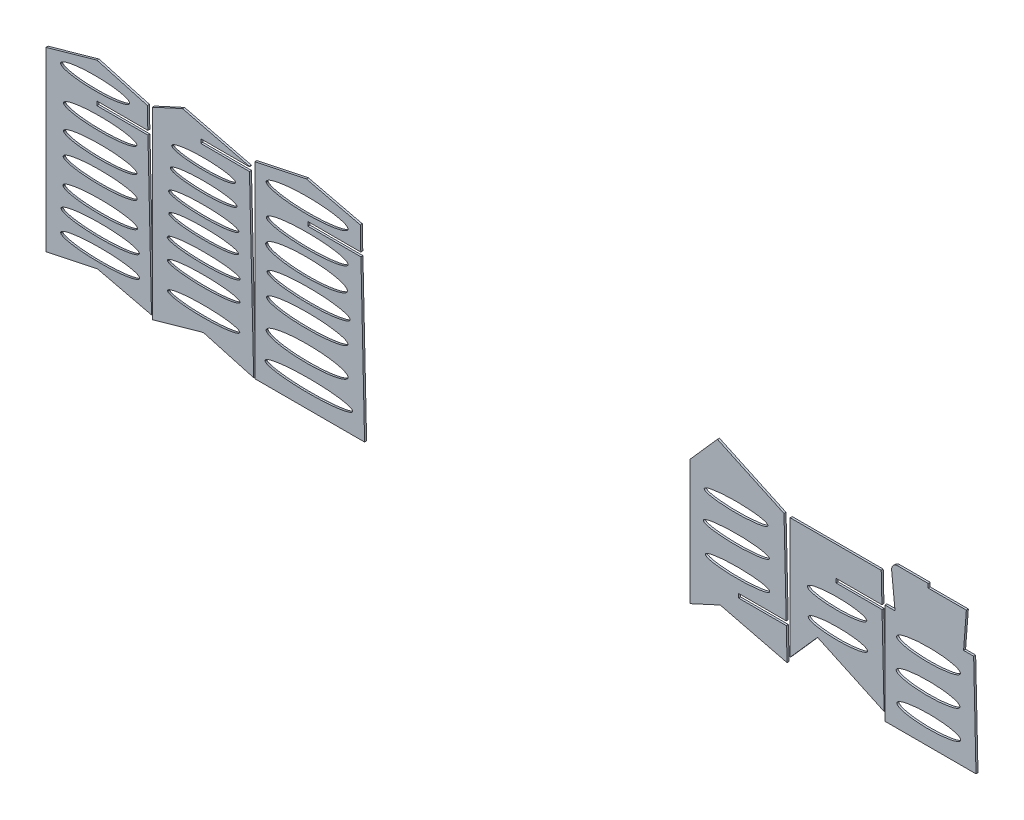
SolidWorks part; units mm, degrees
ref_plane "前视基准面" through (0, 0, 0) normal (0, 0, 1) x (1, 0, 0)
ref_plane "上视基准面" through (0, 0, 0) normal (0, 1, 0) x (1, 0, 0)
ref_plane "右视基准面" through (0, 0, 0) normal (1, 0, 0) x (0, 0, -1)
sketch "Model" plane through (0, 0, 0) normal (0, 0, 1) x (1, 0, 0)
  line L0 (495.016, 88.9868) -> (495.016, 86.9868)
  line L1 (495.016, 86.9868) -> (513.9529, 86.9868)
  line L2 (479.8484, 88.9868) -> (495.016, 88.9868)
  line L3 (518.7316, 18.9868) -> (517.5708, 68.9868)
  line L4 (473.5334, 18.9868) -> (473.5334, 68.9868)
  line L5 (473.5334, 18.9868) -> (518.7316, 18.9868)
  line L6 (473.5334, 68.9868) -> (478.5334, 68.9868)
  line L7 (478.5334, 68.9868) -> (476.8632, 85.6883)
  line L8 (512.5708, 68.9868) -> (513.9529, 86.9868)
  line L9 (512.5708, 68.9868) -> (517.5708, 68.9868)
  line L10 (424.9458, 19.8873) -> (391.7505, 28.0766)
  line L11 (391.7505, 28.0766) -> (376.7986, 21.1847)
  line L12 (424.9458, 19.8873) -> (424.5694, 35.6373)
  line L13 (400.9462, 35.6373) -> (424.5694, 35.6373)
  line L14 (400.9286, 37.6373) -> (424.5216, 37.6373)
  line L15 (400.9462, 35.6373) -> (400.9286, 37.6373)
  line L16 (424.5216, 37.6373) -> (423.4307, 83.2877)
  line L17 (376.7986, 83.2877) -> (390.3773, 98.6376)
  line L18 (390.3773, 98.6376) -> (423.4307, 83.2877)
  line L19 (472.0828, 66.3268) -> (449.3117, 66.3268)
  line L20 (449.3117, 68.3268) -> (472.035, 68.3268)
  line L21 (449.3117, 68.3268) -> (449.3117, 66.3268)
  line L22 (473.1184, 22.9911) -> (472.0828, 66.3268)
  line L23 (426.4863, 82.9911) -> (471.6845, 82.9911)
  line L24 (426.4863, 22.9911) -> (440.0651, 38.341)
  line L25 (440.0651, 38.341) -> (473.1184, 22.9911)
  line L26 (376.7986, 21.1847) -> (376.7986, 83.2877)
  line L27 (426.4863, 22.9911) -> (426.4863, 82.9911)
  line L28 (472.035, 68.3268) -> (471.6845, 82.9911)
  line L29 (82.6758, 17.9977) -> (57.1308, 12.6235)
  line L30 (82.4211, 107.6345) -> (57.0731, 100.5026)
  line L31 (107.6761, 88.0508) -> (109.4473, 11.6329)
  line L32 (82.3743, 90.0508) -> (107.6131, 90.0508)
  line L33 (109.4473, 11.6329) -> (82.6758, 17.9977)
  line L34 (107.4149, 100.6761) -> (82.4211, 107.6345)
  line L35 (107.6131, 90.0508) -> (107.4149, 100.6761)
  line L36 (213.068, 102.1888) -> (213.3369, 90.6067)
  line L37 (213.3951, 88.6067) -> (215.2255, 9.8564)
  line L38 (160.7515, 9.8564) -> (160.7515, 103.1795)
  line L39 (187.0575, 90.6067) -> (213.3369, 90.6067)
  line L40 (215.2255, 9.8564) -> (160.7515, 9.8564)
  line L41 (213.068, 102.1888) -> (186.2965, 108.5536)
  line L42 (186.2965, 108.5536) -> (160.7515, 103.1795)
  line L43 (158.0208, 99.8541) -> (124.8254, 108.0434)
  line L44 (124.8254, 108.0434) -> (109.8782, 101.1536)
  line L45 (109.8268, 9.8061) -> (109.8782, 101.1536)
  line L46 (133.9659, 99.6041) -> (158.0301, 99.6041)
  line L47 (133.9775, 97.6041) -> (158.0768, 97.6041)
  line L48 (160.1687, 9.9795) -> (135.1748, 16.9379)
  line L49 (135.1748, 16.9379) -> (109.8268, 9.8061)
  line L50 (57.0731, 100.5026) -> (57.1308, 12.6235)
  line L51 (158.0768, 97.6041) -> (160.1687, 9.9795)
  line L52 (187.0575, 90.6067) -> (187.0575, 88.6067)
  line L53 (187.0575, 88.6067) -> (213.3951, 88.6067)
  line L54 (82.3743, 88.0508) -> (107.6761, 88.0508)
  line L55 (82.3743, 90.0508) -> (82.3743, 88.0508)
  line L56 (133.9659, 99.6041) -> (133.9775, 97.6041)
  line L57 (158.0208, 99.8541) -> (158.0301, 99.6041)
  line L58 (98.5899, 97.263) -> (98.5699, 97.103)
  line L59 (98.5699, 97.103) -> (98.5099, 96.943)
  line L60 (98.5099, 96.943) -> (98.4099, 96.785)
  line L61 (98.4099, 96.785) -> (98.2599, 96.627)
  line L62 (98.2599, 96.627) -> (98.0799, 96.47)
  line L63 (98.0799, 96.47) -> (97.8499, 96.316)
  line L64 (97.8499, 96.316) -> (97.5899, 96.164)
  line L65 (97.5899, 96.164) -> (97.2899, 96.014)
  line L66 (97.2899, 96.014) -> (96.9399, 95.868)
  line L67 (96.9399, 95.868) -> (96.5699, 95.725)
  line L68 (96.5699, 95.725) -> (96.1499, 95.585)
  line L69 (96.1499, 95.585) -> (95.6999, 95.45)
  line L70 (95.6999, 95.45) -> (95.2199, 95.319)
  line L71 (95.2199, 95.319) -> (94.6999, 95.193)
  line L72 (94.6999, 95.193) -> (94.1499, 95.072)
  line L73 (94.1499, 95.072) -> (93.5699, 94.956)
  line L74 (93.5699, 94.956) -> (92.9599, 94.845)
  line L75 (92.9599, 94.845) -> (92.3199, 94.74)
  line L76 (92.3199, 94.74) -> (91.6599, 94.642)
  line L77 (91.6599, 94.642) -> (90.9699, 94.55)
  line L78 (90.9699, 94.55) -> (90.2599, 94.464)
  line L79 (90.2599, 94.464) -> (89.5199, 94.385)
  line L80 (89.5199, 94.385) -> (88.7699, 94.313)
  line L81 (88.7699, 94.313) -> (87.9999, 94.248)
  line L82 (87.9999, 94.248) -> (87.2199, 94.19)
  line L83 (87.2199, 94.19) -> (86.4199, 94.14)
  line L84 (86.4199, 94.14) -> (85.6099, 94.097)
  line L85 (85.6099, 94.097) -> (84.7899, 94.062)
  line L86 (84.7899, 94.062) -> (83.9599, 94.035)
  line L87 (83.9599, 94.035) -> (83.1199, 94.015)
  line L88 (83.1199, 94.015) -> (82.2799, 94.004)
  line L89 (82.2799, 94.004) -> (81.4399, 94)
  line L90 (81.4399, 94) -> (80.5999, 94.004)
  line L91 (80.5999, 94.004) -> (79.7599, 94.015)
  line L92 (79.7599, 94.015) -> (78.9199, 94.035)
  line L93 (78.9199, 94.035) -> (78.0899, 94.062)
  line L94 (78.0899, 94.062) -> (77.2699, 94.097)
  line L95 (77.2699, 94.097) -> (76.4599, 94.14)
  line L96 (76.4599, 94.14) -> (75.6599, 94.19)
  line L97 (75.6599, 94.19) -> (74.8799, 94.248)
  line L98 (74.8799, 94.248) -> (74.1099, 94.313)
  line L99 (74.1099, 94.313) -> (73.3499, 94.385)
  line L100 (73.3499, 94.385) -> (72.6199, 94.464)
  line L101 (72.6199, 94.464) -> (71.9099, 94.55)
  line L102 (71.9099, 94.55) -> (71.2199, 94.642)
  line L103 (71.2199, 94.642) -> (70.5599, 94.74)
  line L104 (70.5599, 94.74) -> (69.9199, 94.845)
  line L105 (69.9199, 94.845) -> (69.3099, 94.956)
  line L106 (69.3099, 94.956) -> (68.7299, 95.072)
  line L107 (68.7299, 95.072) -> (68.1799, 95.193)
  line L108 (68.1799, 95.193) -> (67.6599, 95.319)
  line L109 (67.6599, 95.319) -> (67.1799, 95.45)
  line L110 (67.1799, 95.45) -> (66.7299, 95.585)
  line L111 (66.7299, 95.585) -> (66.3099, 95.725)
  line L112 (66.3099, 95.725) -> (65.9399, 95.868)
  line L113 (65.9399, 95.868) -> (65.5899, 96.014)
  line L114 (65.5899, 96.014) -> (65.2899, 96.164)
  line L115 (65.2899, 96.164) -> (65.0299, 96.316)
  line L116 (65.0299, 96.316) -> (64.7999, 96.47)
  line L117 (64.7999, 96.47) -> (64.6199, 96.627)
  line L118 (64.6199, 96.627) -> (64.4699, 96.785)
  line L119 (64.4699, 96.785) -> (64.3699, 96.943)
  line L120 (64.3699, 96.943) -> (64.3099, 97.103)
  line L121 (64.3099, 97.103) -> (64.2899, 97.263)
  line L122 (64.2899, 97.263) -> (64.3099, 97.424)
  line L123 (64.3099, 97.424) -> (64.3699, 97.583)
  line L124 (64.3699, 97.583) -> (64.4699, 97.742)
  line L125 (64.4699, 97.742) -> (64.6199, 97.9)
  line L126 (64.6199, 97.9) -> (64.7999, 98.056)
  line L127 (64.7999, 98.056) -> (65.0299, 98.211)
  line L128 (65.0299, 98.211) -> (65.2899, 98.363)
  line L129 (65.2899, 98.363) -> (65.5899, 98.512)
  line L130 (65.5899, 98.512) -> (65.9399, 98.659)
  line L131 (65.9399, 98.659) -> (66.3099, 98.802)
  line L132 (66.3099, 98.802) -> (66.7299, 98.941)
  line L133 (66.7299, 98.941) -> (67.1799, 99.077)
  line L134 (67.1799, 99.077) -> (67.6599, 99.208)
  line L135 (67.6599, 99.208) -> (68.1799, 99.334)
  line L136 (68.1799, 99.334) -> (68.7299, 99.455)
  line L137 (68.7299, 99.455) -> (69.3099, 99.571)
  line L138 (69.3099, 99.571) -> (69.9199, 99.682)
  line L139 (69.9199, 99.682) -> (70.5599, 99.786)
  line L140 (70.5599, 99.786) -> (71.2199, 99.885)
  line L141 (71.2199, 99.885) -> (71.9099, 99.977)
  line L142 (71.9099, 99.977) -> (72.6199, 100.063)
  line L143 (72.6199, 100.063) -> (73.3499, 100.142)
  line L144 (73.3499, 100.142) -> (74.1099, 100.214)
  line L145 (74.1099, 100.214) -> (74.8799, 100.279)
  line L146 (74.8799, 100.279) -> (75.6599, 100.336)
  line L147 (75.6599, 100.336) -> (76.4599, 100.387)
  line L148 (76.4599, 100.387) -> (77.2699, 100.429)
  line L149 (77.2699, 100.429) -> (78.0899, 100.464)
  line L150 (78.0899, 100.464) -> (78.9199, 100.492)
  line L151 (78.9199, 100.492) -> (79.7599, 100.511)
  line L152 (79.7599, 100.511) -> (80.5999, 100.523)
  line L153 (80.5999, 100.523) -> (81.4399, 100.527)
  line L154 (81.4399, 100.527) -> (82.2799, 100.523)
  line L155 (82.2799, 100.523) -> (83.1199, 100.511)
  line L156 (83.1199, 100.511) -> (83.9599, 100.492)
  line L157 (83.9599, 100.492) -> (84.7899, 100.464)
  line L158 (84.7899, 100.464) -> (85.6099, 100.429)
  line L159 (85.6099, 100.429) -> (86.4199, 100.387)
  line L160 (86.4199, 100.387) -> (87.2199, 100.336)
  line L161 (87.2199, 100.336) -> (87.9999, 100.279)
  line L162 (87.9999, 100.279) -> (88.7699, 100.214)
  line L163 (88.7699, 100.214) -> (89.5199, 100.142)
  line L164 (89.5199, 100.142) -> (90.2599, 100.063)
  line L165 (90.2599, 100.063) -> (90.9699, 99.977)
  line L166 (90.9699, 99.977) -> (91.6599, 99.885)
  line L167 (91.6599, 99.885) -> (92.3199, 99.786)
  line L168 (92.3199, 99.786) -> (92.9599, 99.682)
  line L169 (92.9599, 99.682) -> (93.5699, 99.571)
  line L170 (93.5699, 99.571) -> (94.1499, 99.455)
  line L171 (94.1499, 99.455) -> (94.6999, 99.334)
  line L172 (94.6999, 99.334) -> (95.2199, 99.208)
  line L173 (95.2199, 99.208) -> (95.6999, 99.077)
  line L174 (95.6999, 99.077) -> (96.1499, 98.941)
  line L175 (96.1499, 98.941) -> (96.5699, 98.802)
  line L176 (96.5699, 98.802) -> (96.9399, 98.659)
  line L177 (96.9399, 98.659) -> (97.2899, 98.512)
  line L178 (97.2899, 98.512) -> (97.5899, 98.363)
  line L179 (97.5899, 98.363) -> (97.8499, 98.211)
  line L180 (97.8499, 98.211) -> (98.0799, 98.056)
  line L181 (98.0799, 98.056) -> (98.2599, 97.9)
  line L182 (98.2599, 97.9) -> (98.4099, 97.742)
  line L183 (98.4099, 97.742) -> (98.5099, 97.583)
  line L184 (98.5099, 97.583) -> (98.5699, 97.424)
  line L185 (98.5699, 97.424) -> (98.5899, 97.263)
  line L186 (102.1799, 80.965) -> (102.1599, 80.804)
  line L187 (102.1599, 80.804) -> (102.0899, 80.645)
  line L188 (102.0899, 80.645) -> (101.9799, 80.486)
  line L189 (101.9799, 80.486) -> (101.8299, 80.328)
  line L190 (101.8299, 80.328) -> (101.6399, 80.172)
  line L191 (101.6399, 80.172) -> (101.3999, 80.017)
  line L192 (101.3999, 80.017) -> (101.1199, 79.865)
  line L193 (101.1199, 79.865) -> (100.7899, 79.716)
  line L194 (100.7899, 79.716) -> (100.4299, 79.569)
  line L195 (100.4299, 79.569) -> (100.0299, 79.426)
  line L196 (100.0299, 79.426) -> (99.5899, 79.287)
  line L197 (99.5899, 79.287) -> (99.1099, 79.151)
  line L198 (99.1099, 79.151) -> (98.5999, 79.02)
  line L199 (98.5999, 79.02) -> (98.0499, 78.894)
  line L200 (98.0499, 78.894) -> (97.4599, 78.773)
  line L201 (97.4599, 78.773) -> (96.8499, 78.657)
  line L202 (96.8499, 78.657) -> (96.1999, 78.546)
  line L203 (96.1999, 78.546) -> (95.5199, 78.442)
  line L204 (95.5199, 78.442) -> (94.8199, 78.343)
  line L205 (94.8199, 78.343) -> (94.0899, 78.251)
  line L206 (94.0899, 78.251) -> (93.3299, 78.165)
  line L207 (93.3299, 78.165) -> (92.5599, 78.086)
  line L208 (92.5599, 78.086) -> (91.7599, 78.014)
  line L209 (91.7599, 78.014) -> (90.9399, 77.949)
  line L210 (90.9399, 77.949) -> (90.1099, 77.892)
  line L211 (90.1099, 77.892) -> (89.2599, 77.841)
  line L212 (89.2599, 77.841) -> (88.3999, 77.799)
  line L213 (88.3999, 77.799) -> (87.5299, 77.763)
  line L214 (87.5299, 77.763) -> (86.6499, 77.736)
  line L215 (86.6499, 77.736) -> (85.7599, 77.716)
  line L216 (85.7599, 77.716) -> (84.8699, 77.705)
  line L217 (84.8699, 77.705) -> (83.9699, 77.701)
  line L218 (83.9699, 77.701) -> (83.0799, 77.705)
  line L219 (83.0799, 77.705) -> (82.1899, 77.716)
  line L220 (82.1899, 77.716) -> (81.2999, 77.736)
  line L221 (81.2999, 77.736) -> (80.4199, 77.763)
  line L222 (80.4199, 77.763) -> (79.5499, 77.799)
  line L223 (79.5499, 77.799) -> (78.6899, 77.841)
  line L224 (78.6899, 77.841) -> (77.8399, 77.892)
  line L225 (77.8399, 77.892) -> (77.0099, 77.949)
  line L226 (77.0099, 77.949) -> (76.1899, 78.014)
  line L227 (76.1899, 78.014) -> (75.3899, 78.086)
  line L228 (75.3899, 78.086) -> (74.6099, 78.165)
  line L229 (74.6099, 78.165) -> (73.8599, 78.251)
  line L230 (73.8599, 78.251) -> (73.1299, 78.343)
  line L231 (73.1299, 78.343) -> (72.4199, 78.442)
  line L232 (72.4199, 78.442) -> (71.7499, 78.546)
  line L233 (71.7499, 78.546) -> (71.0999, 78.657)
  line L234 (71.0999, 78.657) -> (70.4799, 78.773)
  line L235 (70.4799, 78.773) -> (69.8999, 78.894)
  line L236 (69.8999, 78.894) -> (69.3499, 79.02)
  line L237 (69.3499, 79.02) -> (68.8399, 79.151)
  line L238 (68.8399, 79.151) -> (68.3599, 79.287)
  line L239 (68.3599, 79.287) -> (67.9199, 79.426)
  line L240 (67.9199, 79.426) -> (67.5199, 79.569)
  line L241 (67.5199, 79.569) -> (67.1499, 79.716)
  line L242 (67.1499, 79.716) -> (66.8299, 79.865)
  line L243 (66.8299, 79.865) -> (66.5499, 80.017)
  line L244 (66.5499, 80.017) -> (66.3099, 80.172)
  line L245 (66.3099, 80.172) -> (66.1199, 80.328)
  line L246 (66.1199, 80.328) -> (65.9699, 80.486)
  line L247 (65.9699, 80.486) -> (65.8599, 80.645)
  line L248 (65.8599, 80.645) -> (65.7899, 80.804)
  line L249 (65.7899, 80.804) -> (65.7699, 80.965)
  line L250 (65.7699, 80.965) -> (65.7899, 81.125)
  line L251 (65.7899, 81.125) -> (65.8599, 81.284)
  line L252 (65.8599, 81.284) -> (65.9699, 81.443)
  line L253 (65.9699, 81.443) -> (66.1199, 81.601)
  line L254 (66.1199, 81.601) -> (66.3099, 81.758)
  line L255 (66.3099, 81.758) -> (66.5499, 81.912)
  line L256 (66.5499, 81.912) -> (66.8299, 82.064)
  line L257 (66.8299, 82.064) -> (67.1499, 82.214)
  line L258 (67.1499, 82.214) -> (67.5199, 82.36)
  line L259 (67.5199, 82.36) -> (67.9199, 82.503)
  line L260 (67.9199, 82.503) -> (68.3599, 82.642)
  line L261 (68.3599, 82.642) -> (68.8399, 82.778)
  line L262 (68.8399, 82.778) -> (69.3499, 82.909)
  line L263 (69.3499, 82.909) -> (69.8999, 83.035)
  line L264 (69.8999, 83.035) -> (70.4799, 83.156)
  line L265 (70.4799, 83.156) -> (71.0999, 83.272)
  line L266 (71.0999, 83.272) -> (71.7499, 83.383)
  line L267 (71.7499, 83.383) -> (72.4199, 83.487)
  line L268 (72.4199, 83.487) -> (73.1299, 83.586)
  line L269 (73.1299, 83.586) -> (73.8599, 83.678)
  line L270 (73.8599, 83.678) -> (74.6099, 83.764)
  line L271 (74.6099, 83.764) -> (75.3899, 83.843)
  line L272 (75.3899, 83.843) -> (76.1899, 83.915)
  line L273 (76.1899, 83.915) -> (77.0099, 83.98)
  line L274 (77.0099, 83.98) -> (77.8399, 84.038)
  line L275 (77.8399, 84.038) -> (78.6899, 84.088)
  line L276 (78.6899, 84.088) -> (79.5499, 84.131)
  line L277 (79.5499, 84.131) -> (80.4199, 84.166)
  line L278 (80.4199, 84.166) -> (81.2999, 84.193)
  line L279 (81.2999, 84.193) -> (82.1899, 84.213)
  line L280 (82.1899, 84.213) -> (83.0799, 84.224)
  line L281 (83.0799, 84.224) -> (83.9699, 84.228)
  line L282 (83.9699, 84.228) -> (84.8699, 84.224)
  line L283 (84.8699, 84.224) -> (85.7599, 84.213)
  line L284 (85.7599, 84.213) -> (86.6499, 84.193)
  line L285 (86.6499, 84.193) -> (87.5299, 84.166)
  line L286 (87.5299, 84.166) -> (88.3999, 84.131)
  line L287 (88.3999, 84.131) -> (89.2599, 84.088)
  line L288 (89.2599, 84.088) -> (90.1099, 84.038)
  line L289 (90.1099, 84.038) -> (90.9399, 83.98)
  line L290 (90.9399, 83.98) -> (91.7599, 83.915)
  line L291 (91.7599, 83.915) -> (92.5599, 83.843)
  line L292 (92.5599, 83.843) -> (93.3299, 83.764)
  line L293 (93.3299, 83.764) -> (94.0899, 83.678)
  line L294 (94.0899, 83.678) -> (94.8199, 83.586)
  line L295 (94.8199, 83.586) -> (95.5199, 83.487)
  line L296 (95.5199, 83.487) -> (96.1999, 83.383)
  line L297 (96.1999, 83.383) -> (96.8499, 83.272)
  line L298 (96.8499, 83.272) -> (97.4599, 83.156)
  line L299 (97.4599, 83.156) -> (98.0499, 83.035)
  line L300 (98.0499, 83.035) -> (98.5999, 82.909)
  line L301 (98.5999, 82.909) -> (99.1099, 82.778)
  line L302 (99.1099, 82.778) -> (99.5899, 82.642)
  line L303 (99.5899, 82.642) -> (100.0299, 82.503)
  line L304 (100.0299, 82.503) -> (100.4299, 82.36)
  line L305 (100.4299, 82.36) -> (100.7899, 82.214)
  line L306 (100.7899, 82.214) -> (101.1199, 82.064)
  line L307 (101.1199, 82.064) -> (101.3999, 81.912)
  line L308 (101.3999, 81.912) -> (101.6399, 81.758)
  line L309 (101.6399, 81.758) -> (101.8299, 81.601)
  line L310 (101.8299, 81.601) -> (101.9799, 81.443)
  line L311 (101.9799, 81.443) -> (102.0899, 81.284)
  line L312 (102.0899, 81.284) -> (102.1599, 81.125)
  line L313 (102.1599, 81.125) -> (102.1799, 80.965)
  line L314 (102.1799, 68.906) -> (102.1599, 68.746)
  line L315 (102.1599, 68.746) -> (102.0899, 68.586)
  line L316 (102.0899, 68.586) -> (101.9799, 68.428)
  line L317 (101.9799, 68.428) -> (101.8299, 68.27)
  line L318 (101.8299, 68.27) -> (101.6399, 68.113)
  line L319 (101.6399, 68.113) -> (101.3999, 67.959)
  line L320 (101.3999, 67.959) -> (101.1199, 67.807)
  line L321 (101.1199, 67.807) -> (100.7899, 67.657)
  line L322 (100.7899, 67.657) -> (100.4299, 67.511)
  line L323 (100.4299, 67.511) -> (100.0299, 67.368)
  line L324 (100.0299, 67.368) -> (99.5899, 67.228)
  line L325 (99.5899, 67.228) -> (99.1099, 67.093)
  line L326 (99.1099, 67.093) -> (98.5999, 66.962)
  line L327 (98.5999, 66.962) -> (98.0499, 66.836)
  line L328 (98.0499, 66.836) -> (97.4599, 66.715)
  line L329 (97.4599, 66.715) -> (96.8499, 66.599)
  line L330 (96.8499, 66.599) -> (96.1999, 66.488)
  line L331 (96.1999, 66.488) -> (95.5199, 66.383)
  line L332 (95.5199, 66.383) -> (94.8199, 66.285)
  line L333 (94.8199, 66.285) -> (94.0899, 66.193)
  line L334 (94.0899, 66.193) -> (93.3299, 66.107)
  line L335 (93.3299, 66.107) -> (92.5599, 66.028)
  line L336 (92.5599, 66.028) -> (91.7599, 65.956)
  line L337 (91.7599, 65.956) -> (90.9399, 65.891)
  line L338 (90.9399, 65.891) -> (90.1099, 65.833)
  line L339 (90.1099, 65.833) -> (89.2599, 65.783)
  line L340 (89.2599, 65.783) -> (88.3999, 65.74)
  line L341 (88.3999, 65.74) -> (87.5299, 65.705)
  line L342 (87.5299, 65.705) -> (86.6499, 65.678)
  line L343 (86.6499, 65.678) -> (85.7599, 65.658)
  line L344 (85.7599, 65.658) -> (84.8699, 65.647)
  line L345 (84.8699, 65.647) -> (83.9699, 65.643)
  line L346 (83.9699, 65.643) -> (83.0799, 65.647)
  line L347 (83.0799, 65.647) -> (82.1899, 65.658)
  line L348 (82.1899, 65.658) -> (81.2999, 65.678)
  line L349 (81.2999, 65.678) -> (80.4199, 65.705)
  line L350 (80.4199, 65.705) -> (79.5499, 65.74)
  line L351 (79.5499, 65.74) -> (78.6899, 65.783)
  line L352 (78.6899, 65.783) -> (77.8399, 65.833)
  line L353 (77.8399, 65.833) -> (77.0099, 65.891)
  line L354 (77.0099, 65.891) -> (76.1899, 65.956)
  line L355 (76.1899, 65.956) -> (75.3899, 66.028)
  line L356 (75.3899, 66.028) -> (74.6099, 66.107)
  line L357 (74.6099, 66.107) -> (73.8599, 66.193)
  line L358 (73.8599, 66.193) -> (73.1299, 66.285)
  line L359 (73.1299, 66.285) -> (72.4199, 66.383)
  line L360 (72.4199, 66.383) -> (71.7499, 66.488)
  line L361 (71.7499, 66.488) -> (71.0999, 66.599)
  line L362 (71.0999, 66.599) -> (70.4799, 66.715)
  line L363 (70.4799, 66.715) -> (69.8999, 66.836)
  line L364 (69.8999, 66.836) -> (69.3499, 66.962)
  line L365 (69.3499, 66.962) -> (68.8399, 67.093)
  line L366 (68.8399, 67.093) -> (68.3599, 67.228)
  line L367 (68.3599, 67.228) -> (67.9199, 67.368)
  line L368 (67.9199, 67.368) -> (67.5199, 67.511)
  line L369 (67.5199, 67.511) -> (67.1499, 67.657)
  line L370 (67.1499, 67.657) -> (66.8299, 67.807)
  line L371 (66.8299, 67.807) -> (66.5499, 67.959)
  line L372 (66.5499, 67.959) -> (66.3099, 68.113)
  line L373 (66.3099, 68.113) -> (66.1199, 68.27)
  line L374 (66.1199, 68.27) -> (65.9699, 68.428)
  line L375 (65.9699, 68.428) -> (65.8599, 68.586)
  line L376 (65.8599, 68.586) -> (65.7899, 68.746)
  line L377 (65.7899, 68.746) -> (65.7699, 68.906)
  line L378 (65.7699, 68.906) -> (65.7899, 69.067)
  line L379 (65.7899, 69.067) -> (65.8599, 69.226)
  line L380 (65.8599, 69.226) -> (65.9699, 69.385)
  line L381 (65.9699, 69.385) -> (66.1199, 69.543)
  line L382 (66.1199, 69.543) -> (66.3099, 69.699)
  line L383 (66.3099, 69.699) -> (66.5499, 69.854)
  line L384 (66.5499, 69.854) -> (66.8299, 70.006)
  line L385 (66.8299, 70.006) -> (67.1499, 70.155)
  line L386 (67.1499, 70.155) -> (67.5199, 70.302)
  line L387 (67.5199, 70.302) -> (67.9199, 70.445)
  line L388 (67.9199, 70.445) -> (68.3599, 70.584)
  line L389 (68.3599, 70.584) -> (68.8399, 70.72)
  line L390 (68.8399, 70.72) -> (69.3499, 70.851)
  line L391 (69.3499, 70.851) -> (69.8999, 70.977)
  line L392 (69.8999, 70.977) -> (70.4799, 71.098)
  line L393 (70.4799, 71.098) -> (71.0999, 71.214)
  line L394 (71.0999, 71.214) -> (71.7499, 71.325)
  line L395 (71.7499, 71.325) -> (72.4199, 71.429)
  line L396 (72.4199, 71.429) -> (73.1299, 71.528)
  line L397 (73.1299, 71.528) -> (73.8599, 71.62)
  line L398 (73.8599, 71.62) -> (74.6099, 71.706)
  line L399 (74.6099, 71.706) -> (75.3899, 71.785)
  line L400 (75.3899, 71.785) -> (76.1899, 71.857)
  line L401 (76.1899, 71.857) -> (77.0099, 71.922)
  line L402 (77.0099, 71.922) -> (77.8399, 71.979)
  line L403 (77.8399, 71.979) -> (78.6899, 72.03)
  line L404 (78.6899, 72.03) -> (79.5499, 72.072)
  line L405 (79.5499, 72.072) -> (80.4199, 72.107)
  line L406 (80.4199, 72.107) -> (81.2999, 72.135)
  line L407 (81.2999, 72.135) -> (82.1899, 72.154)
  line L408 (82.1899, 72.154) -> (83.0799, 72.166)
  line L409 (83.0799, 72.166) -> (83.9699, 72.17)
  line L410 (83.9699, 72.17) -> (84.8699, 72.166)
  line L411 (84.8699, 72.166) -> (85.7599, 72.154)
  line L412 (85.7599, 72.154) -> (86.6499, 72.135)
  line L413 (86.6499, 72.135) -> (87.5299, 72.107)
  line L414 (87.5299, 72.107) -> (88.3999, 72.072)
  line L415 (88.3999, 72.072) -> (89.2599, 72.03)
  line L416 (89.2599, 72.03) -> (90.1099, 71.979)
  line L417 (90.1099, 71.979) -> (90.9399, 71.922)
  line L418 (90.9399, 71.922) -> (91.7599, 71.857)
  line L419 (91.7599, 71.857) -> (92.5599, 71.785)
  line L420 (92.5599, 71.785) -> (93.3299, 71.706)
  line L421 (93.3299, 71.706) -> (94.0899, 71.62)
  line L422 (94.0899, 71.62) -> (94.8199, 71.528)
  line L423 (94.8199, 71.528) -> (95.5199, 71.429)
  line L424 (95.5199, 71.429) -> (96.1999, 71.325)
  line L425 (96.1999, 71.325) -> (96.8499, 71.214)
  line L426 (96.8499, 71.214) -> (97.4599, 71.098)
  line L427 (97.4599, 71.098) -> (98.0499, 70.977)
  line L428 (98.0499, 70.977) -> (98.5999, 70.851)
  line L429 (98.5999, 70.851) -> (99.1099, 70.72)
  line L430 (99.1099, 70.72) -> (99.5899, 70.584)
  line L431 (99.5899, 70.584) -> (100.0299, 70.445)
  line L432 (100.0299, 70.445) -> (100.4299, 70.302)
  line L433 (100.4299, 70.302) -> (100.7899, 70.155)
  line L434 (100.7899, 70.155) -> (101.1199, 70.006)
  line L435 (101.1199, 70.006) -> (101.3999, 69.854)
  line L436 (101.3999, 69.854) -> (101.6399, 69.699)
  line L437 (101.6399, 69.699) -> (101.8299, 69.543)
  line L438 (101.8299, 69.543) -> (101.9799, 69.385)
  line L439 (101.9799, 69.385) -> (102.0899, 69.226)
  line L440 (102.0899, 69.226) -> (102.1599, 69.067)
  line L441 (102.1599, 69.067) -> (102.1799, 68.906)
  line L442 (102.3499, 57.871) -> (102.3299, 57.71)
  line L443 (102.3299, 57.71) -> (102.2599, 57.551)
  line L444 (102.2599, 57.551) -> (102.1499, 57.392)
  line L445 (102.1499, 57.392) -> (101.9899, 57.234)
  line L446 (101.9899, 57.234) -> (101.7999, 57.078)
  line L447 (101.7999, 57.078) -> (101.5599, 56.923)
  line L448 (101.5599, 56.923) -> (101.2699, 56.771)
  line L449 (101.2699, 56.771) -> (100.9499, 56.622)
  line L450 (100.9499, 56.622) -> (100.5799, 56.475)
  line L451 (100.5799, 56.475) -> (100.1799, 56.332)
  line L452 (100.1799, 56.332) -> (99.7299, 56.193)
  line L453 (99.7299, 56.193) -> (99.2499, 56.057)
  line L454 (99.2499, 56.057) -> (98.7299, 55.926)
  line L455 (98.7299, 55.926) -> (98.1799, 55.8)
  line L456 (98.1799, 55.8) -> (97.5899, 55.679)
  line L457 (97.5899, 55.679) -> (96.9699, 55.563)
  line L458 (96.9699, 55.563) -> (96.3099, 55.452)
  line L459 (96.3099, 55.452) -> (95.6299, 55.348)
  line L460 (95.6299, 55.348) -> (94.9199, 55.249)
  line L461 (94.9199, 55.249) -> (94.1799, 55.157)
  line L462 (94.1799, 55.157) -> (93.4199, 55.071)
  line L463 (93.4199, 55.071) -> (92.6399, 54.992)
  line L464 (92.6399, 54.992) -> (91.8299, 54.92)
  line L465 (91.8299, 54.92) -> (91.0099, 54.855)
  line L466 (91.0099, 54.855) -> (90.1599, 54.798)
  line L467 (90.1599, 54.798) -> (89.3099, 54.747)
  line L468 (89.3099, 54.747) -> (88.4399, 54.705)
  line L469 (88.4399, 54.705) -> (87.5599, 54.67)
  line L470 (87.5599, 54.67) -> (86.6699, 54.642)
  line L471 (86.6699, 54.642) -> (85.7799, 54.623)
  line L472 (85.7799, 54.623) -> (84.8799, 54.611)
  line L473 (84.8799, 54.611) -> (83.9699, 54.607)
  line L474 (83.9699, 54.607) -> (83.0699, 54.611)
  line L475 (83.0699, 54.611) -> (82.1699, 54.623)
  line L476 (82.1699, 54.623) -> (81.2799, 54.642)
  line L477 (81.2799, 54.642) -> (80.3899, 54.67)
  line L478 (80.3899, 54.67) -> (79.5099, 54.705)
  line L479 (79.5099, 54.705) -> (78.6399, 54.747)
  line L480 (78.6399, 54.747) -> (77.7799, 54.798)
  line L481 (77.7799, 54.798) -> (76.9399, 54.855)
  line L482 (76.9399, 54.855) -> (76.1199, 54.92)
  line L483 (76.1199, 54.92) -> (75.3099, 54.992)
  line L484 (75.3099, 54.992) -> (74.5299, 55.071)
  line L485 (74.5299, 55.071) -> (73.7699, 55.157)
  line L486 (73.7699, 55.157) -> (73.0299, 55.249)
  line L487 (73.0299, 55.249) -> (72.3199, 55.348)
  line L488 (72.3199, 55.348) -> (71.6399, 55.452)
  line L489 (71.6399, 55.452) -> (70.9799, 55.563)
  line L490 (70.9799, 55.563) -> (70.3599, 55.679)
  line L491 (70.3599, 55.679) -> (69.7699, 55.8)
  line L492 (69.7699, 55.8) -> (69.2199, 55.926)
  line L493 (69.2199, 55.926) -> (68.6999, 56.057)
  line L494 (68.6999, 56.057) -> (68.2199, 56.193)
  line L495 (68.2199, 56.193) -> (67.7699, 56.332)
  line L496 (67.7699, 56.332) -> (67.3699, 56.475)
  line L497 (67.3699, 56.475) -> (66.9999, 56.622)
  line L498 (66.9999, 56.622) -> (66.6799, 56.771)
  line L499 (66.6799, 56.771) -> (66.3899, 56.923)
  line L500 (66.3899, 56.923) -> (66.1499, 57.078)
  line L501 (66.1499, 57.078) -> (65.9499, 57.234)
  line L502 (65.9499, 57.234) -> (65.7999, 57.392)
  line L503 (65.7999, 57.392) -> (65.6899, 57.551)
  line L504 (65.6899, 57.551) -> (65.6199, 57.71)
  line L505 (65.6199, 57.71) -> (65.5999, 57.871)
  line L506 (65.5999, 57.871) -> (65.6199, 58.031)
  line L507 (65.6199, 58.031) -> (65.6899, 58.19)
  line L508 (65.6899, 58.19) -> (65.7999, 58.349)
  line L509 (65.7999, 58.349) -> (65.9499, 58.507)
  line L510 (65.9499, 58.507) -> (66.1499, 58.664)
  line L511 (66.1499, 58.664) -> (66.3899, 58.818)
  line L512 (66.3899, 58.818) -> (66.6799, 58.97)
  line L513 (66.6799, 58.97) -> (66.9999, 59.12)
  line L514 (66.9999, 59.12) -> (67.3699, 59.266)
  line L515 (67.3699, 59.266) -> (67.7699, 59.409)
  line L516 (67.7699, 59.409) -> (68.2199, 59.548)
  line L517 (68.2199, 59.548) -> (68.6999, 59.684)
  line L518 (68.6999, 59.684) -> (69.2199, 59.815)
  line L519 (69.2199, 59.815) -> (69.7699, 59.941)
  line L520 (69.7699, 59.941) -> (70.3599, 60.062)
  line L521 (70.3599, 60.062) -> (70.9799, 60.178)
  line L522 (70.9799, 60.178) -> (71.6399, 60.289)
  line L523 (71.6399, 60.289) -> (72.3199, 60.393)
  line L524 (72.3199, 60.393) -> (73.0299, 60.492)
  line L525 (73.0299, 60.492) -> (73.7699, 60.584)
  line L526 (73.7699, 60.584) -> (74.5299, 60.67)
  line L527 (74.5299, 60.67) -> (75.3099, 60.749)
  line L528 (75.3099, 60.749) -> (76.1199, 60.821)
  line L529 (76.1199, 60.821) -> (76.9399, 60.886)
  line L530 (76.9399, 60.886) -> (77.7799, 60.944)
  line L531 (77.7799, 60.944) -> (78.6399, 60.994)
  line L532 (78.6399, 60.994) -> (79.5099, 61.037)
  line L533 (79.5099, 61.037) -> (80.3899, 61.072)
  line L534 (80.3899, 61.072) -> (81.2799, 61.099)
  line L535 (81.2799, 61.099) -> (82.1699, 61.119)
  line L536 (82.1699, 61.119) -> (83.0699, 61.13)
  line L537 (83.0699, 61.13) -> (83.9699, 61.134)
  line L538 (83.9699, 61.134) -> (84.8799, 61.13)
  line L539 (84.8799, 61.13) -> (85.7799, 61.119)
  line L540 (85.7799, 61.119) -> (86.6699, 61.099)
  line L541 (86.6699, 61.099) -> (87.5599, 61.072)
  line L542 (87.5599, 61.072) -> (88.4399, 61.037)
  line L543 (88.4399, 61.037) -> (89.3099, 60.994)
  line L544 (89.3099, 60.994) -> (90.1599, 60.944)
  line L545 (90.1599, 60.944) -> (91.0099, 60.886)
  line L546 (91.0099, 60.886) -> (91.8299, 60.821)
  line L547 (91.8299, 60.821) -> (92.6399, 60.749)
  line L548 (92.6399, 60.749) -> (93.4199, 60.67)
  line L549 (93.4199, 60.67) -> (94.1799, 60.584)
  line L550 (94.1799, 60.584) -> (94.9199, 60.492)
  line L551 (94.9199, 60.492) -> (95.6299, 60.393)
  line L552 (95.6299, 60.393) -> (96.3099, 60.289)
  line L553 (96.3099, 60.289) -> (96.9699, 60.178)
  line L554 (96.9699, 60.178) -> (97.5899, 60.062)
  line L555 (97.5899, 60.062) -> (98.1799, 59.941)
  line L556 (98.1799, 59.941) -> (98.7299, 59.815)
  line L557 (98.7299, 59.815) -> (99.2499, 59.684)
  line L558 (99.2499, 59.684) -> (99.7299, 59.548)
  line L559 (99.7299, 59.548) -> (100.1799, 59.409)
  line L560 (100.1799, 59.409) -> (100.5799, 59.266)
  line L561 (100.5799, 59.266) -> (100.9499, 59.12)
  line L562 (100.9499, 59.12) -> (101.2699, 58.97)
  line L563 (101.2699, 58.97) -> (101.5599, 58.818)
  line L564 (101.5599, 58.818) -> (101.7999, 58.664)
  line L565 (101.7999, 58.664) -> (101.9899, 58.507)
  line L566 (101.9899, 58.507) -> (102.1499, 58.349)
  line L567 (102.1499, 58.349) -> (102.2599, 58.19)
  line L568 (102.2599, 58.19) -> (102.3299, 58.031)
  line L569 (102.3299, 58.031) -> (102.3499, 57.871)
  line L570 (102.5099, 45.332) -> (102.4899, 45.172)
  line L571 (102.4899, 45.172) -> (102.4299, 45.012)
  line L572 (102.4299, 45.012) -> (102.3099, 44.853)
  line L573 (102.3099, 44.853) -> (102.1599, 44.695)
  line L574 (102.1599, 44.695) -> (101.9599, 44.539)
  line L575 (101.9599, 44.539) -> (101.7199, 44.385)
  line L576 (101.7199, 44.385) -> (101.4299, 44.232)
  line L577 (101.4299, 44.232) -> (101.0999, 44.083)
  line L578 (101.0999, 44.083) -> (100.7299, 43.937)
  line L579 (100.7299, 43.937) -> (100.3299, 43.793)
  line L580 (100.3299, 43.793) -> (99.8799, 43.654)
  line L581 (99.8799, 43.654) -> (99.3899, 43.519)
  line L582 (99.3899, 43.519) -> (98.8699, 43.388)
  line L583 (98.8699, 43.388) -> (98.3099, 43.262)
  line L584 (98.3099, 43.262) -> (97.7099, 43.14)
  line L585 (97.7099, 43.14) -> (97.0799, 43.024)
  line L586 (97.0799, 43.024) -> (96.4299, 42.914)
  line L587 (96.4299, 42.914) -> (95.7399, 42.809)
  line L588 (95.7399, 42.809) -> (95.0199, 42.711)
  line L589 (95.0199, 42.711) -> (94.2699, 42.618)
  line L590 (94.2699, 42.618) -> (93.5099, 42.533)
  line L591 (93.5099, 42.533) -> (92.7099, 42.454)
  line L592 (92.7099, 42.454) -> (91.8999, 42.382)
  line L593 (91.8999, 42.382) -> (91.0699, 42.317)
  line L594 (91.0699, 42.317) -> (90.2199, 42.259)
  line L595 (90.2199, 42.259) -> (89.3599, 42.209)
  line L596 (89.3599, 42.209) -> (88.4799, 42.166)
  line L597 (88.4799, 42.166) -> (87.5899, 42.131)
  line L598 (87.5899, 42.131) -> (86.6899, 42.104)
  line L599 (86.6899, 42.104) -> (85.7899, 42.084)
  line L600 (85.7899, 42.084) -> (84.8799, 42.072)
  line L601 (84.8799, 42.072) -> (83.9699, 42.068)
  line L602 (83.9699, 42.068) -> (83.0599, 42.072)
  line L603 (83.0599, 42.072) -> (82.1599, 42.084)
  line L604 (82.1599, 42.084) -> (81.2499, 42.104)
  line L605 (81.2499, 42.104) -> (80.3599, 42.131)
  line L606 (80.3599, 42.131) -> (79.4699, 42.166)
  line L607 (79.4699, 42.166) -> (78.5899, 42.209)
  line L608 (78.5899, 42.209) -> (77.7299, 42.259)
  line L609 (77.7299, 42.259) -> (76.8799, 42.317)
  line L610 (76.8799, 42.317) -> (76.0499, 42.382)
  line L611 (76.0499, 42.382) -> (75.2299, 42.454)
  line L612 (75.2299, 42.454) -> (74.4399, 42.533)
  line L613 (74.4399, 42.533) -> (73.6699, 42.618)
  line L614 (73.6699, 42.618) -> (72.9299, 42.711)
  line L615 (72.9299, 42.711) -> (72.2099, 42.809)
  line L616 (72.2099, 42.809) -> (71.5199, 42.914)
  line L617 (71.5199, 42.914) -> (70.8599, 43.024)
  line L618 (70.8599, 43.024) -> (70.2399, 43.14)
  line L619 (70.2399, 43.14) -> (69.6399, 43.262)
  line L620 (69.6399, 43.262) -> (69.0799, 43.388)
  line L621 (69.0799, 43.388) -> (68.5599, 43.519)
  line L622 (68.5599, 43.519) -> (68.0699, 43.654)
  line L623 (68.0699, 43.654) -> (67.6199, 43.793)
  line L624 (67.6199, 43.793) -> (67.2099, 43.937)
  line L625 (67.2099, 43.937) -> (66.8499, 44.083)
  line L626 (66.8499, 44.083) -> (66.5199, 44.232)
  line L627 (66.5199, 44.232) -> (66.2299, 44.385)
  line L628 (66.2299, 44.385) -> (65.9899, 44.539)
  line L629 (65.9899, 44.539) -> (65.7899, 44.695)
  line L630 (65.7899, 44.695) -> (65.6399, 44.853)
  line L631 (65.6399, 44.853) -> (65.5199, 45.012)
  line L632 (65.5199, 45.012) -> (65.4599, 45.172)
  line L633 (65.4599, 45.172) -> (65.4299, 45.332)
  line L634 (65.4299, 45.332) -> (65.4599, 45.492)
  line L635 (65.4599, 45.492) -> (65.5199, 45.652)
  line L636 (65.5199, 45.652) -> (65.6399, 45.811)
  line L637 (65.6399, 45.811) -> (65.7899, 45.969)
  line L638 (65.7899, 45.969) -> (65.9899, 46.125)
  line L639 (65.9899, 46.125) -> (66.2299, 46.279)
  line L640 (66.2299, 46.279) -> (66.5199, 46.432)
  line L641 (66.5199, 46.432) -> (66.8499, 46.581)
  line L642 (66.8499, 46.581) -> (67.2099, 46.727)
  line L643 (67.2099, 46.727) -> (67.6199, 46.871)
  line L644 (67.6199, 46.871) -> (68.0699, 47.01)
  line L645 (68.0699, 47.01) -> (68.5599, 47.145)
  line L646 (68.5599, 47.145) -> (69.0799, 47.276)
  line L647 (69.0799, 47.276) -> (69.6399, 47.403)
  line L648 (69.6399, 47.403) -> (70.2399, 47.524)
  line L649 (70.2399, 47.524) -> (70.8599, 47.64)
  line L650 (70.8599, 47.64) -> (71.5199, 47.75)
  line L651 (71.5199, 47.75) -> (72.2099, 47.855)
  line L652 (72.2099, 47.855) -> (72.9299, 47.954)
  line L653 (72.9299, 47.954) -> (73.6699, 48.046)
  line L654 (73.6699, 48.046) -> (74.4399, 48.131)
  line L655 (74.4399, 48.131) -> (75.2299, 48.21)
  line L656 (75.2299, 48.21) -> (76.0499, 48.282)
  line L657 (76.0499, 48.282) -> (76.8799, 48.347)
  line L658 (76.8799, 48.347) -> (77.7299, 48.405)
  line L659 (77.7299, 48.405) -> (78.5899, 48.455)
  line L660 (78.5899, 48.455) -> (79.4699, 48.498)
  line L661 (79.4699, 48.498) -> (80.3599, 48.533)
  line L662 (80.3599, 48.533) -> (81.2499, 48.56)
  line L663 (81.2499, 48.56) -> (82.1599, 48.58)
  line L664 (82.1599, 48.58) -> (83.0599, 48.592)
  line L665 (83.0599, 48.592) -> (83.9699, 48.596)
  line L666 (83.9699, 48.596) -> (84.8799, 48.592)
  line L667 (84.8799, 48.592) -> (85.7899, 48.58)
  line L668 (85.7899, 48.58) -> (86.6899, 48.56)
  line L669 (86.6899, 48.56) -> (87.5899, 48.533)
  line L670 (87.5899, 48.533) -> (88.4799, 48.498)
  line L671 (88.4799, 48.498) -> (89.3599, 48.455)
  line L672 (89.3599, 48.455) -> (90.2199, 48.405)
  line L673 (90.2199, 48.405) -> (91.0699, 48.347)
  line L674 (91.0699, 48.347) -> (91.8999, 48.282)
  line L675 (91.8999, 48.282) -> (92.7099, 48.21)
  line L676 (92.7099, 48.21) -> (93.5099, 48.131)
  line L677 (93.5099, 48.131) -> (94.2699, 48.046)
  line L678 (94.2699, 48.046) -> (95.0199, 47.954)
  line L679 (95.0199, 47.954) -> (95.7399, 47.855)
  line L680 (95.7399, 47.855) -> (96.4299, 47.75)
  line L681 (96.4299, 47.75) -> (97.0799, 47.64)
  line L682 (97.0799, 47.64) -> (97.7099, 47.524)
  line L683 (97.7099, 47.524) -> (98.3099, 47.403)
  line L684 (98.3099, 47.403) -> (98.8699, 47.276)
  line L685 (98.8699, 47.276) -> (99.3899, 47.145)
  line L686 (99.3899, 47.145) -> (99.8799, 47.01)
  line L687 (99.8799, 47.01) -> (100.3299, 46.871)
  line L688 (100.3299, 46.871) -> (100.7299, 46.727)
  line L689 (100.7299, 46.727) -> (101.0999, 46.581)
  line L690 (101.0999, 46.581) -> (101.4299, 46.432)
  line L691 (101.4299, 46.432) -> (101.7199, 46.279)
  line L692 (101.7199, 46.279) -> (101.9599, 46.125)
  line L693 (101.9599, 46.125) -> (102.1599, 45.969)
  line L694 (102.1599, 45.969) -> (102.3099, 45.811)
  line L695 (102.3099, 45.811) -> (102.4299, 45.652)
  line L696 (102.4299, 45.652) -> (102.4899, 45.492)
  line L697 (102.4899, 45.492) -> (102.5099, 45.332)
  line L698 (103.4099, 35.007) -> (103.3799, 34.847)
  line L699 (103.3799, 34.847) -> (103.3099, 34.688)
  line L700 (103.3099, 34.688) -> (103.1899, 34.529)
  line L701 (103.1899, 34.529) -> (103.0299, 34.371)
  line L702 (103.0299, 34.371) -> (102.8199, 34.214)
  line L703 (102.8199, 34.214) -> (102.5699, 34.06)
  line L704 (102.5699, 34.06) -> (102.2699, 33.908)
  line L705 (102.2699, 33.908) -> (101.9299, 33.758)
  line L706 (101.9299, 33.758) -> (101.5399, 33.612)
  line L707 (101.5399, 33.612) -> (101.1099, 33.469)
  line L708 (101.1099, 33.469) -> (100.6399, 33.33)
  line L709 (100.6399, 33.33) -> (100.1299, 33.194)
  line L710 (100.1299, 33.194) -> (99.5799, 33.063)
  line L711 (99.5799, 33.063) -> (98.9899, 32.937)
  line L712 (98.9899, 32.937) -> (98.3699, 32.816)
  line L713 (98.3699, 32.816) -> (97.7099, 32.7)
  line L714 (97.7099, 32.7) -> (97.0199, 32.589)
  line L715 (97.0199, 32.589) -> (96.2999, 32.485)
  line L716 (96.2999, 32.485) -> (95.5499, 32.386)
  line L717 (95.5499, 32.386) -> (94.7699, 32.294)
  line L718 (94.7699, 32.294) -> (93.9599, 32.208)
  line L719 (93.9599, 32.208) -> (93.1299, 32.129)
  line L720 (93.1299, 32.129) -> (92.2799, 32.057)
  line L721 (92.2799, 32.057) -> (91.4099, 31.992)
  line L722 (91.4099, 31.992) -> (90.5199, 31.934)
  line L723 (90.5199, 31.934) -> (89.6099, 31.884)
  line L724 (89.6099, 31.884) -> (88.6999, 31.842)
  line L725 (88.6999, 31.842) -> (87.7699, 31.806)
  line L726 (87.7699, 31.806) -> (86.8299, 31.779)
  line L727 (86.8299, 31.779) -> (85.8799, 31.759)
  line L728 (85.8799, 31.759) -> (84.9299, 31.748)
  line L729 (84.9299, 31.748) -> (83.9699, 31.744)
  line L730 (83.9699, 31.744) -> (83.0199, 31.748)
  line L731 (83.0199, 31.748) -> (82.0699, 31.759)
  line L732 (82.0699, 31.759) -> (81.1199, 31.779)
  line L733 (81.1199, 31.779) -> (80.1799, 31.806)
  line L734 (80.1799, 31.806) -> (79.2499, 31.842)
  line L735 (79.2499, 31.842) -> (78.3299, 31.884)
  line L736 (78.3299, 31.884) -> (77.4299, 31.934)
  line L737 (77.4299, 31.934) -> (76.5399, 31.992)
  line L738 (76.5399, 31.992) -> (75.6699, 32.057)
  line L739 (75.6699, 32.057) -> (74.8199, 32.129)
  line L740 (74.8199, 32.129) -> (73.9899, 32.208)
  line L741 (73.9899, 32.208) -> (73.1799, 32.294)
  line L742 (73.1799, 32.294) -> (72.3999, 32.386)
  line L743 (72.3999, 32.386) -> (71.6499, 32.485)
  line L744 (71.6499, 32.485) -> (70.9299, 32.589)
  line L745 (70.9299, 32.589) -> (70.2399, 32.7)
  line L746 (70.2399, 32.7) -> (69.5799, 32.816)
  line L747 (69.5799, 32.816) -> (68.9499, 32.937)
  line L748 (68.9499, 32.937) -> (68.3699, 33.063)
  line L749 (68.3699, 33.063) -> (67.8199, 33.194)
  line L750 (67.8199, 33.194) -> (67.3099, 33.33)
  line L751 (67.3099, 33.33) -> (66.8399, 33.469)
  line L752 (66.8399, 33.469) -> (66.4099, 33.612)
  line L753 (66.4099, 33.612) -> (66.0199, 33.758)
  line L754 (66.0199, 33.758) -> (65.6799, 33.908)
  line L755 (65.6799, 33.908) -> (65.3799, 34.06)
  line L756 (65.3799, 34.06) -> (65.1299, 34.214)
  line L757 (65.1299, 34.214) -> (64.9199, 34.371)
  line L758 (64.9199, 34.371) -> (64.7499, 34.529)
  line L759 (64.7499, 34.529) -> (64.6399, 34.688)
  line L760 (64.6399, 34.688) -> (64.5699, 34.847)
  line L761 (64.5699, 34.847) -> (64.5399, 35.007)
  line L762 (64.5399, 35.007) -> (64.5699, 35.168)
  line L763 (64.5699, 35.168) -> (64.6399, 35.327)
  line L764 (64.6399, 35.327) -> (64.7499, 35.486)
  line L765 (64.7499, 35.486) -> (64.9199, 35.644)
  line L766 (64.9199, 35.644) -> (65.1299, 35.8)
  line L767 (65.1299, 35.8) -> (65.3799, 35.955)
  line L768 (65.3799, 35.955) -> (65.6799, 36.107)
  line L769 (65.6799, 36.107) -> (66.0199, 36.256)
  line L770 (66.0199, 36.256) -> (66.4099, 36.403)
  line L771 (66.4099, 36.403) -> (66.8399, 36.546)
  line L772 (66.8399, 36.546) -> (67.3099, 36.685)
  line L773 (67.3099, 36.685) -> (67.8199, 36.821)
  line L774 (67.8199, 36.821) -> (68.3699, 36.952)
  line L775 (68.3699, 36.952) -> (68.9499, 37.078)
  line L776 (68.9499, 37.078) -> (69.5799, 37.199)
  line L777 (69.5799, 37.199) -> (70.2399, 37.315)
  line L778 (70.2399, 37.315) -> (70.9299, 37.426)
  line L779 (70.9299, 37.426) -> (71.6499, 37.53)
  line L780 (71.6499, 37.53) -> (72.3999, 37.629)
  line L781 (72.3999, 37.629) -> (73.1799, 37.721)
  line L782 (73.1799, 37.721) -> (73.9899, 37.807)
  line L783 (73.9899, 37.807) -> (74.8199, 37.886)
  line L784 (74.8199, 37.886) -> (75.6699, 37.958)
  line L785 (75.6699, 37.958) -> (76.5399, 38.023)
  line L786 (76.5399, 38.023) -> (77.4299, 38.08)
  line L787 (77.4299, 38.08) -> (78.3299, 38.131)
  line L788 (78.3299, 38.131) -> (79.2499, 38.173)
  line L789 (79.2499, 38.173) -> (80.1799, 38.209)
  line L790 (80.1799, 38.209) -> (81.1199, 38.236)
  line L791 (81.1199, 38.236) -> (82.0699, 38.256)
  line L792 (82.0699, 38.256) -> (83.0199, 38.267)
  line L793 (83.0199, 38.267) -> (83.9699, 38.271)
  line L794 (83.9699, 38.271) -> (84.9299, 38.267)
  line L795 (84.9299, 38.267) -> (85.8799, 38.256)
  line L796 (85.8799, 38.256) -> (86.8299, 38.236)
  line L797 (86.8299, 38.236) -> (87.7699, 38.209)
  line L798 (87.7699, 38.209) -> (88.6999, 38.173)
  line L799 (88.6999, 38.173) -> (89.6099, 38.131)
  line L800 (89.6099, 38.131) -> (90.5199, 38.08)
  line L801 (90.5199, 38.08) -> (91.4099, 38.023)
  line L802 (91.4099, 38.023) -> (92.2799, 37.958)
  line L803 (92.2799, 37.958) -> (93.1299, 37.886)
  line L804 (93.1299, 37.886) -> (93.9599, 37.807)
  line L805 (93.9599, 37.807) -> (94.7699, 37.721)
  line L806 (94.7699, 37.721) -> (95.5499, 37.629)
  line L807 (95.5499, 37.629) -> (96.2999, 37.53)
  line L808 (96.2999, 37.53) -> (97.0199, 37.426)
  line L809 (97.0199, 37.426) -> (97.7099, 37.315)
  line L810 (97.7099, 37.315) -> (98.3699, 37.199)
  line L811 (98.3699, 37.199) -> (98.9899, 37.078)
  line L812 (98.9899, 37.078) -> (99.5799, 36.952)
  line L813 (99.5799, 36.952) -> (100.1299, 36.821)
  line L814 (100.1299, 36.821) -> (100.6399, 36.685)
  line L815 (100.6399, 36.685) -> (101.1099, 36.546)
  line L816 (101.1099, 36.546) -> (101.5399, 36.403)
  line L817 (101.5399, 36.403) -> (101.9299, 36.256)
  line L818 (101.9299, 36.256) -> (102.2699, 36.107)
  line L819 (102.2699, 36.107) -> (102.5699, 35.955)
  line L820 (102.5699, 35.955) -> (102.8199, 35.8)
  line L821 (102.8199, 35.8) -> (103.0299, 35.644)
  line L822 (103.0299, 35.644) -> (103.1899, 35.486)
  line L823 (103.1899, 35.486) -> (103.3099, 35.327)
  line L824 (103.3099, 35.327) -> (103.3799, 35.168)
  line L825 (103.3799, 35.168) -> (103.4099, 35.007)
  line L826 (103.5999, 24.467) -> (103.5799, 24.307)
  line L827 (103.5799, 24.307) -> (103.5099, 24.147)
  line L828 (103.5099, 24.147) -> (103.3899, 23.988)
  line L829 (103.3899, 23.988) -> (103.2299, 23.831)
  line L830 (103.2299, 23.831) -> (103.0199, 23.674)
  line L831 (103.0199, 23.674) -> (102.7599, 23.52)
  line L832 (102.7599, 23.52) -> (102.4599, 23.368)
  line L833 (102.4599, 23.368) -> (102.1099, 23.218)
  line L834 (102.1099, 23.218) -> (101.7199, 23.072)
  line L835 (101.7199, 23.072) -> (101.2899, 22.929)
  line L836 (101.2899, 22.929) -> (100.8099, 22.789)
  line L837 (100.8099, 22.789) -> (100.2999, 22.654)
  line L838 (100.2999, 22.654) -> (99.7399, 22.523)
  line L839 (99.7399, 22.523) -> (99.1499, 22.397)
  line L840 (99.1499, 22.397) -> (98.5199, 22.276)
  line L841 (98.5199, 22.276) -> (97.8499, 22.16)
  line L842 (97.8499, 22.16) -> (97.1599, 22.049)
  line L843 (97.1599, 22.049) -> (96.4299, 21.944)
  line L844 (96.4299, 21.944) -> (95.6699, 21.846)
  line L845 (95.6699, 21.846) -> (94.8799, 21.754)
  line L846 (94.8799, 21.754) -> (94.0699, 21.668)
  line L847 (94.0699, 21.668) -> (93.2299, 21.589)
  line L848 (93.2299, 21.589) -> (92.3699, 21.517)
  line L849 (92.3699, 21.517) -> (91.4899, 21.452)
  line L850 (91.4899, 21.452) -> (90.5899, 21.394)
  line L851 (90.5899, 21.394) -> (89.6699, 21.344)
  line L852 (89.6699, 21.344) -> (88.7399, 21.301)
  line L853 (88.7399, 21.301) -> (87.7999, 21.266)
  line L854 (87.7999, 21.266) -> (86.8499, 21.239)
  line L855 (86.8499, 21.239) -> (85.8999, 21.219)
  line L856 (85.8999, 21.219) -> (84.9399, 21.208)
  line L857 (84.9399, 21.208) -> (83.9699, 21.204)
  line L858 (83.9699, 21.204) -> (83.0099, 21.208)
  line L859 (83.0099, 21.208) -> (82.0499, 21.219)
  line L860 (82.0499, 21.219) -> (81.0899, 21.239)
  line L861 (81.0899, 21.239) -> (80.1499, 21.266)
  line L862 (80.1499, 21.266) -> (79.2099, 21.301)
  line L863 (79.2099, 21.301) -> (78.2799, 21.344)
  line L864 (78.2799, 21.344) -> (77.3599, 21.394)
  line L865 (77.3599, 21.394) -> (76.4599, 21.452)
  line L866 (76.4599, 21.452) -> (75.5799, 21.517)
  line L867 (75.5799, 21.517) -> (74.7199, 21.589)
  line L868 (74.7199, 21.589) -> (73.8799, 21.668)
  line L869 (73.8799, 21.668) -> (73.0699, 21.754)
  line L870 (73.0699, 21.754) -> (72.2799, 21.846)
  line L871 (72.2799, 21.846) -> (71.5199, 21.944)
  line L872 (71.5199, 21.944) -> (70.7899, 22.049)
  line L873 (70.7899, 22.049) -> (70.0899, 22.16)
  line L874 (70.0899, 22.16) -> (69.4299, 22.276)
  line L875 (69.4299, 22.276) -> (68.7999, 22.397)
  line L876 (68.7999, 22.397) -> (68.2099, 22.523)
  line L877 (68.2099, 22.523) -> (67.6499, 22.654)
  line L878 (67.6499, 22.654) -> (67.1399, 22.789)
  line L879 (67.1399, 22.789) -> (66.6599, 22.929)
  line L880 (66.6599, 22.929) -> (66.2299, 23.072)
  line L881 (66.2299, 23.072) -> (65.8399, 23.218)
  line L882 (65.8399, 23.218) -> (65.4899, 23.368)
  line L883 (65.4899, 23.368) -> (65.1899, 23.52)
  line L884 (65.1899, 23.52) -> (64.9299, 23.674)
  line L885 (64.9299, 23.674) -> (64.7199, 23.831)
  line L886 (64.7199, 23.831) -> (64.5599, 23.988)
  line L887 (64.5599, 23.988) -> (64.4399, 24.147)
  line L888 (64.4399, 24.147) -> (64.3699, 24.307)
  line L889 (64.3699, 24.307) -> (64.3499, 24.467)
  line L890 (64.3499, 24.467) -> (64.3699, 24.627)
  line L891 (64.3699, 24.627) -> (64.4399, 24.787)
  line L892 (64.4399, 24.787) -> (64.5599, 24.946)
  line L893 (64.5599, 24.946) -> (64.7199, 25.104)
  line L894 (64.7199, 25.104) -> (64.9299, 25.26)
  line L895 (64.9299, 25.26) -> (65.1899, 25.415)
  line L896 (65.1899, 25.415) -> (65.4899, 25.567)
  line L897 (65.4899, 25.567) -> (65.8399, 25.716)
  line L898 (65.8399, 25.716) -> (66.2299, 25.863)
  line L899 (66.2299, 25.863) -> (66.6599, 26.006)
  line L900 (66.6599, 26.006) -> (67.1399, 26.145)
  line L901 (67.1399, 26.145) -> (67.6499, 26.281)
  line L902 (67.6499, 26.281) -> (68.2099, 26.412)
  line L903 (68.2099, 26.412) -> (68.7999, 26.538)
  line L904 (68.7999, 26.538) -> (69.4299, 26.659)
  line L905 (69.4299, 26.659) -> (70.0899, 26.775)
  line L906 (70.0899, 26.775) -> (70.7899, 26.886)
  line L907 (70.7899, 26.886) -> (71.5199, 26.99)
  line L908 (71.5199, 26.99) -> (72.2799, 27.089)
  line L909 (72.2799, 27.089) -> (73.0699, 27.181)
  line L910 (73.0699, 27.181) -> (73.8799, 27.267)
  line L911 (73.8799, 27.267) -> (74.7199, 27.346)
  line L912 (74.7199, 27.346) -> (75.5799, 27.418)
  line L913 (75.5799, 27.418) -> (76.4599, 27.483)
  line L914 (76.4599, 27.483) -> (77.3599, 27.54)
  line L915 (77.3599, 27.54) -> (78.2799, 27.591)
  line L916 (78.2799, 27.591) -> (79.2099, 27.633)
  line L917 (79.2099, 27.633) -> (80.1499, 27.668)
  line L918 (80.1499, 27.668) -> (81.0899, 27.696)
  line L919 (81.0899, 27.696) -> (82.0499, 27.715)
  line L920 (82.0499, 27.715) -> (83.0099, 27.727)
  line L921 (83.0099, 27.727) -> (83.9699, 27.731)
  line L922 (83.9699, 27.731) -> (84.9399, 27.727)
  line L923 (84.9399, 27.727) -> (85.8999, 27.715)
  line L924 (85.8999, 27.715) -> (86.8499, 27.696)
  line L925 (86.8499, 27.696) -> (87.7999, 27.668)
  line L926 (87.7999, 27.668) -> (88.7399, 27.633)
  line L927 (88.7399, 27.633) -> (89.6699, 27.591)
  line L928 (89.6699, 27.591) -> (90.5899, 27.54)
  line L929 (90.5899, 27.54) -> (91.4899, 27.483)
  line L930 (91.4899, 27.483) -> (92.3699, 27.418)
  line L931 (92.3699, 27.418) -> (93.2299, 27.346)
  line L932 (93.2299, 27.346) -> (94.0699, 27.267)
  line L933 (94.0699, 27.267) -> (94.8799, 27.181)
  line L934 (94.8799, 27.181) -> (95.6699, 27.089)
  line L935 (95.6699, 27.089) -> (96.4299, 26.99)
  line L936 (96.4299, 26.99) -> (97.1599, 26.886)
  line L937 (97.1599, 26.886) -> (97.8499, 26.775)
  line L938 (97.8499, 26.775) -> (98.5199, 26.659)
  line L939 (98.5199, 26.659) -> (99.1499, 26.538)
  line L940 (99.1499, 26.538) -> (99.7399, 26.412)
  line L941 (99.7399, 26.412) -> (100.2999, 26.281)
  line L942 (100.2999, 26.281) -> (100.8099, 26.145)
  line L943 (100.8099, 26.145) -> (101.2899, 26.006)
  line L944 (101.2899, 26.006) -> (101.7199, 25.863)
  line L945 (101.7199, 25.863) -> (102.1099, 25.716)
  line L946 (102.1099, 25.716) -> (102.4599, 25.567)
  line L947 (102.4599, 25.567) -> (102.7599, 25.415)
  line L948 (102.7599, 25.415) -> (103.0199, 25.26)
  line L949 (103.0199, 25.26) -> (103.2299, 25.104)
  line L950 (103.2299, 25.104) -> (103.3899, 24.946)
  line L951 (103.3899, 24.946) -> (103.5099, 24.787)
  line L952 (103.5099, 24.787) -> (103.5799, 24.627)
  line L953 (103.5799, 24.627) -> (103.5999, 24.467)
  line L954 (166.3388, 97.3247) -> (166.3588, 97.5117)
  line L955 (166.3588, 97.5117) -> (166.4388, 97.6977)
  line L956 (166.4388, 97.6977) -> (166.5588, 97.8837)
  line L957 (166.5588, 97.8837) -> (166.7288, 98.0677)
  line L958 (166.7288, 98.0677) -> (166.9488, 98.2507)
  line L959 (166.9488, 98.2507) -> (167.2188, 98.4307)
  line L960 (167.2188, 98.4307) -> (167.5288, 98.6087)
  line L961 (167.5288, 98.6087) -> (167.8888, 98.7837)
  line L962 (167.8888, 98.7837) -> (168.2888, 98.9547)
  line L963 (168.2888, 98.9547) -> (168.7388, 99.1217)
  line L964 (168.7388, 99.1217) -> (169.2288, 99.2847)
  line L965 (169.2288, 99.2847) -> (169.7688, 99.4427)
  line L966 (169.7688, 99.4427) -> (170.3388, 99.5957)
  line L967 (170.3388, 99.5957) -> (170.9588, 99.7427)
  line L968 (170.9588, 99.7427) -> (171.6088, 99.8847)
  line L969 (171.6088, 99.8847) -> (172.2988, 100.0207)
  line L970 (172.2988, 100.0207) -> (173.0188, 100.1497)
  line L971 (173.0188, 100.1497) -> (173.7788, 100.2717)
  line L972 (173.7788, 100.2717) -> (174.5688, 100.3867)
  line L973 (174.5688, 100.3867) -> (175.3788, 100.4947)
  line L974 (175.3788, 100.4947) -> (176.2288, 100.5947)
  line L975 (176.2288, 100.5947) -> (177.0988, 100.6867)
  line L976 (177.0988, 100.6867) -> (177.9888, 100.7707)
  line L977 (177.9888, 100.7707) -> (178.8988, 100.8467)
  line L978 (178.8988, 100.8467) -> (179.8288, 100.9137)
  line L979 (179.8288, 100.9137) -> (180.7788, 100.9727)
  line L980 (180.7788, 100.9727) -> (181.7388, 101.0227)
  line L981 (181.7388, 101.0227) -> (182.7188, 101.0637)
  line L982 (182.7188, 101.0637) -> (183.6988, 101.0957)
  line L983 (183.6988, 101.0957) -> (184.6888, 101.1187)
  line L984 (184.6888, 101.1187) -> (185.6888, 101.1327)
  line L985 (185.6888, 101.1327) -> (186.6888, 101.1367)
  line L986 (186.6888, 101.1367) -> (187.6888, 101.1327)
  line L987 (187.6888, 101.1327) -> (188.6788, 101.1187)
  line L988 (188.6788, 101.1187) -> (189.6688, 101.0957)
  line L989 (189.6688, 101.0957) -> (190.6588, 101.0637)
  line L990 (190.6588, 101.0637) -> (191.6288, 101.0227)
  line L991 (191.6288, 101.0227) -> (192.5988, 100.9727)
  line L992 (192.5988, 100.9727) -> (193.5388, 100.9137)
  line L993 (193.5388, 100.9137) -> (194.4788, 100.8467)
  line L994 (194.4788, 100.8467) -> (195.3888, 100.7707)
  line L995 (195.3888, 100.7707) -> (196.2788, 100.6867)
  line L996 (196.2788, 100.6867) -> (197.1488, 100.5947)
  line L997 (197.1488, 100.5947) -> (197.9888, 100.4947)
  line L998 (197.9888, 100.4947) -> (198.8088, 100.3867)
  line L999 (198.8088, 100.3867) -> (199.5988, 100.2717)
  line L1000 (199.5988, 100.2717) -> (200.3488, 100.1497)
  line L1001 (200.3488, 100.1497) -> (201.0788, 100.0207)
  line L1002 (201.0788, 100.0207) -> (201.7688, 99.8847)
  line L1003 (201.7688, 99.8847) -> (202.4188, 99.7427)
  line L1004 (202.4188, 99.7427) -> (203.0288, 99.5957)
  line L1005 (203.0288, 99.5957) -> (203.6088, 99.4427)
  line L1006 (203.6088, 99.4427) -> (204.1388, 99.2847)
  line L1007 (204.1388, 99.2847) -> (204.6288, 99.1217)
  line L1008 (204.6288, 99.1217) -> (205.0788, 98.9547)
  line L1009 (205.0788, 98.9547) -> (205.4888, 98.7837)
  line L1010 (205.4888, 98.7837) -> (205.8488, 98.6087)
  line L1011 (205.8488, 98.6087) -> (206.1588, 98.4307)
  line L1012 (206.1588, 98.4307) -> (206.4288, 98.2507)
  line L1013 (206.4288, 98.2507) -> (206.6488, 98.0677)
  line L1014 (206.6488, 98.0677) -> (206.8188, 97.8837)
  line L1015 (206.8188, 97.8837) -> (206.9388, 97.6977)
  line L1016 (206.9388, 97.6977) -> (207.0088, 97.5117)
  line L1017 (207.0088, 97.5117) -> (207.0388, 97.3247)
  line L1018 (207.0388, 97.3247) -> (207.0088, 97.1377)
  line L1019 (207.0088, 97.1377) -> (206.9388, 96.9507)
  line L1020 (206.9388, 96.9507) -> (206.8188, 96.7647)
  line L1021 (206.8188, 96.7647) -> (206.6488, 96.5807)
  line L1022 (206.6488, 96.5807) -> (206.4288, 96.3977)
  line L1023 (206.4288, 96.3977) -> (206.1588, 96.2177)
  line L1024 (206.1588, 96.2177) -> (205.8488, 96.0397)
  line L1025 (205.8488, 96.0397) -> (205.4888, 95.8657)
  line L1026 (205.4888, 95.8657) -> (205.0788, 95.6937)
  line L1027 (205.0788, 95.6937) -> (204.6288, 95.5267)
  line L1028 (204.6288, 95.5267) -> (204.1388, 95.3647)
  line L1029 (204.1388, 95.3647) -> (203.6088, 95.2057)
  line L1030 (203.6088, 95.2057) -> (203.0288, 95.0527)
  line L1031 (203.0288, 95.0527) -> (202.4188, 94.9057)
  line L1032 (202.4188, 94.9057) -> (201.7688, 94.7637)
  line L1033 (201.7688, 94.7637) -> (201.0788, 94.6287)
  line L1034 (201.0788, 94.6287) -> (200.3488, 94.4997)
  line L1035 (200.3488, 94.4997) -> (199.5988, 94.3767)
  line L1036 (199.5988, 94.3767) -> (198.8088, 94.2617)
  line L1037 (198.8088, 94.2617) -> (197.9888, 94.1547)
  line L1038 (197.9888, 94.1547) -> (197.1488, 94.0537)
  line L1039 (197.1488, 94.0537) -> (196.2788, 93.9617)
  line L1040 (196.2788, 93.9617) -> (195.3888, 93.8777)
  line L1041 (195.3888, 93.8777) -> (194.4788, 93.8017)
  line L1042 (194.4788, 93.8017) -> (193.5388, 93.7347)
  line L1043 (193.5388, 93.7347) -> (192.5988, 93.6757)
  line L1044 (192.5988, 93.6757) -> (191.6288, 93.6257)
  line L1045 (191.6288, 93.6257) -> (190.6588, 93.5847)
  line L1046 (190.6588, 93.5847) -> (189.6688, 93.5527)
  line L1047 (189.6688, 93.5527) -> (188.6788, 93.5297)
  line L1048 (188.6788, 93.5297) -> (187.6888, 93.5167)
  line L1049 (187.6888, 93.5167) -> (186.6888, 93.5117)
  line L1050 (186.6888, 93.5117) -> (185.6888, 93.5167)
  line L1051 (185.6888, 93.5167) -> (184.6888, 93.5297)
  line L1052 (184.6888, 93.5297) -> (183.6988, 93.5527)
  line L1053 (183.6988, 93.5527) -> (182.7188, 93.5847)
  line L1054 (182.7188, 93.5847) -> (181.7388, 93.6257)
  line L1055 (181.7388, 93.6257) -> (180.7788, 93.6757)
  line L1056 (180.7788, 93.6757) -> (179.8288, 93.7347)
  line L1057 (179.8288, 93.7347) -> (178.8988, 93.8017)
  line L1058 (178.8988, 93.8017) -> (177.9888, 93.8777)
  line L1059 (177.9888, 93.8777) -> (177.0988, 93.9617)
  line L1060 (177.0988, 93.9617) -> (176.2288, 94.0537)
  line L1061 (176.2288, 94.0537) -> (175.3788, 94.1547)
  line L1062 (175.3788, 94.1547) -> (174.5688, 94.2617)
  line L1063 (174.5688, 94.2617) -> (173.7788, 94.3767)
  line L1064 (173.7788, 94.3767) -> (173.0188, 94.4997)
  line L1065 (173.0188, 94.4997) -> (172.2988, 94.6287)
  line L1066 (172.2988, 94.6287) -> (171.6088, 94.7637)
  line L1067 (171.6088, 94.7637) -> (170.9588, 94.9057)
  line L1068 (170.9588, 94.9057) -> (170.3388, 95.0527)
  line L1069 (170.3388, 95.0527) -> (169.7688, 95.2057)
  line L1070 (169.7688, 95.2057) -> (169.2288, 95.3647)
  line L1071 (169.2288, 95.3647) -> (168.7388, 95.5267)
  line L1072 (168.7388, 95.5267) -> (168.2888, 95.6937)
  line L1073 (168.2888, 95.6937) -> (167.8888, 95.8657)
  line L1074 (167.8888, 95.8657) -> (167.5288, 96.0397)
  line L1075 (167.5288, 96.0397) -> (167.2188, 96.2177)
  line L1076 (167.2188, 96.2177) -> (166.9488, 96.3977)
  line L1077 (166.9488, 96.3977) -> (166.7288, 96.5807)
  line L1078 (166.7288, 96.5807) -> (166.5588, 96.7647)
  line L1079 (166.5588, 96.7647) -> (166.4388, 96.9507)
  line L1080 (166.4388, 96.9507) -> (166.3588, 97.1377)
  line L1081 (166.3588, 97.1377) -> (166.3388, 97.3247)
  line L1082 (166.4388, 82.1047) -> (166.4688, 82.2817)
  line L1083 (166.4688, 82.2817) -> (166.5388, 82.4577)
  line L1084 (166.5388, 82.4577) -> (166.6588, 82.6337)
  line L1085 (166.6588, 82.6337) -> (166.8288, 82.8077)
  line L1086 (166.8288, 82.8077) -> (167.0488, 82.9797)
  line L1087 (167.0488, 82.9797) -> (167.3188, 83.1507)
  line L1088 (167.3188, 83.1507) -> (167.6288, 83.3187)
  line L1089 (167.6288, 83.3187) -> (167.9888, 83.4837)
  line L1090 (167.9888, 83.4837) -> (168.3888, 83.6457)
  line L1091 (168.3888, 83.6457) -> (168.8388, 83.8037)
  line L1092 (168.8388, 83.8037) -> (169.3288, 83.9577)
  line L1093 (169.3288, 83.9577) -> (169.8588, 84.1067)
  line L1094 (169.8588, 84.1067) -> (170.4388, 84.2517)
  line L1095 (170.4388, 84.2517) -> (171.0488, 84.3907)
  line L1096 (171.0488, 84.3907) -> (171.6988, 84.5247)
  line L1097 (171.6988, 84.5247) -> (172.3888, 84.6527)
  line L1098 (172.3888, 84.6527) -> (173.1088, 84.7747)
  line L1099 (173.1088, 84.7747) -> (173.8588, 84.8907)
  line L1100 (173.8588, 84.8907) -> (174.6488, 84.9987)
  line L1101 (174.6488, 84.9987) -> (175.4588, 85.1007)
  line L1102 (175.4588, 85.1007) -> (176.2988, 85.1957)
  line L1103 (176.2988, 85.1957) -> (177.1688, 85.2827)
  line L1104 (177.1688, 85.2827) -> (178.0588, 85.3627)
  line L1105 (178.0588, 85.3627) -> (178.9688, 85.4337)
  line L1106 (178.9688, 85.4337) -> (179.8988, 85.4977)
  line L1107 (179.8988, 85.4977) -> (180.8488, 85.5527)
  line L1108 (180.8488, 85.5527) -> (181.8088, 85.6007)
  line L1109 (181.8088, 85.6007) -> (182.7788, 85.6387)
  line L1110 (182.7788, 85.6387) -> (183.7588, 85.6697)
  line L1111 (183.7588, 85.6697) -> (184.7488, 85.6907)
  line L1112 (184.7488, 85.6907) -> (185.7388, 85.7037)
  line L1113 (185.7388, 85.7037) -> (186.7388, 85.7087)
  line L1114 (186.7388, 85.7087) -> (187.7388, 85.7037)
  line L1115 (187.7388, 85.7037) -> (188.7288, 85.6907)
  line L1116 (188.7288, 85.6907) -> (189.7188, 85.6697)
  line L1117 (189.7188, 85.6697) -> (190.6988, 85.6387)
  line L1118 (190.6988, 85.6387) -> (191.6688, 85.6007)
  line L1119 (191.6688, 85.6007) -> (192.6288, 85.5527)
  line L1120 (192.6288, 85.5527) -> (193.5788, 85.4977)
  line L1121 (193.5788, 85.4977) -> (194.5088, 85.4337)
  line L1122 (194.5088, 85.4337) -> (195.4188, 85.3627)
  line L1123 (195.4188, 85.3627) -> (196.3088, 85.2827)
  line L1124 (196.3088, 85.2827) -> (197.1688, 85.1957)
  line L1125 (197.1688, 85.1957) -> (198.0188, 85.1007)
  line L1126 (198.0188, 85.1007) -> (198.8288, 84.9987)
  line L1127 (198.8288, 84.9987) -> (199.6188, 84.8907)
  line L1128 (199.6188, 84.8907) -> (200.3688, 84.7747)
  line L1129 (200.3688, 84.7747) -> (201.0888, 84.6527)
  line L1130 (201.0888, 84.6527) -> (201.7788, 84.5247)
  line L1131 (201.7788, 84.5247) -> (202.4288, 84.3907)
  line L1132 (202.4288, 84.3907) -> (203.0388, 84.2517)
  line L1133 (203.0388, 84.2517) -> (203.6188, 84.1067)
  line L1134 (203.6188, 84.1067) -> (204.1488, 83.9577)
  line L1135 (204.1488, 83.9577) -> (204.6388, 83.8037)
  line L1136 (204.6388, 83.8037) -> (205.0888, 83.6457)
  line L1137 (205.0888, 83.6457) -> (205.4888, 83.4837)
  line L1138 (205.4888, 83.4837) -> (205.8488, 83.3187)
  line L1139 (205.8488, 83.3187) -> (206.1588, 83.1507)
  line L1140 (206.1588, 83.1507) -> (206.4288, 82.9797)
  line L1141 (206.4288, 82.9797) -> (206.6488, 82.8077)
  line L1142 (206.6488, 82.8077) -> (206.8188, 82.6337)
  line L1143 (206.8188, 82.6337) -> (206.9388, 82.4577)
  line L1144 (206.9388, 82.4577) -> (207.0088, 82.2817)
  line L1145 (207.0088, 82.2817) -> (207.0388, 82.1047)
  line L1146 (207.0388, 82.1047) -> (207.0088, 81.9277)
  line L1147 (207.0088, 81.9277) -> (206.9388, 81.7517)
  line L1148 (206.9388, 81.7517) -> (206.8188, 81.5757)
  line L1149 (206.8188, 81.5757) -> (206.6488, 81.4017)
  line L1150 (206.6488, 81.4017) -> (206.4288, 81.2287)
  line L1151 (206.4288, 81.2287) -> (206.1588, 81.0587)
  line L1152 (206.1588, 81.0587) -> (205.8488, 80.8907)
  line L1153 (205.8488, 80.8907) -> (205.4888, 80.7257)
  line L1154 (205.4888, 80.7257) -> (205.0888, 80.5637)
  line L1155 (205.0888, 80.5637) -> (204.6388, 80.4057)
  line L1156 (204.6388, 80.4057) -> (204.1488, 80.2517)
  line L1157 (204.1488, 80.2517) -> (203.6188, 80.1027)
  line L1158 (203.6188, 80.1027) -> (203.0388, 79.9577)
  line L1159 (203.0388, 79.9577) -> (202.4288, 79.8187)
  line L1160 (202.4288, 79.8187) -> (201.7788, 79.6847)
  line L1161 (201.7788, 79.6847) -> (201.0888, 79.5567)
  line L1162 (201.0888, 79.5567) -> (200.3688, 79.4347)
  line L1163 (200.3688, 79.4347) -> (199.6188, 79.3187)
  line L1164 (199.6188, 79.3187) -> (198.8288, 79.2097)
  line L1165 (198.8288, 79.2097) -> (198.0188, 79.1077)
  line L1166 (198.0188, 79.1077) -> (197.1688, 79.0137)
  line L1167 (197.1688, 79.0137) -> (196.3088, 78.9267)
  line L1168 (196.3088, 78.9267) -> (195.4188, 78.8467)
  line L1169 (195.4188, 78.8467) -> (194.5088, 78.7747)
  line L1170 (194.5088, 78.7747) -> (193.5788, 78.7117)
  line L1171 (193.5788, 78.7117) -> (192.6288, 78.6557)
  line L1172 (192.6288, 78.6557) -> (191.6688, 78.6087)
  line L1173 (191.6688, 78.6087) -> (190.6988, 78.5697)
  line L1174 (190.6988, 78.5697) -> (189.7188, 78.5397)
  line L1175 (189.7188, 78.5397) -> (188.7288, 78.5177)
  line L1176 (188.7288, 78.5177) -> (187.7388, 78.5047)
  line L1177 (187.7388, 78.5047) -> (186.7388, 78.5007)
  line L1178 (186.7388, 78.5007) -> (185.7388, 78.5047)
  line L1179 (185.7388, 78.5047) -> (184.7488, 78.5177)
  line L1180 (184.7488, 78.5177) -> (183.7588, 78.5397)
  line L1181 (183.7588, 78.5397) -> (182.7788, 78.5697)
  line L1182 (182.7788, 78.5697) -> (181.8088, 78.6087)
  line L1183 (181.8088, 78.6087) -> (180.8488, 78.6557)
  line L1184 (180.8488, 78.6557) -> (179.8988, 78.7117)
  line L1185 (179.8988, 78.7117) -> (178.9688, 78.7747)
  line L1186 (178.9688, 78.7747) -> (178.0588, 78.8467)
  line L1187 (178.0588, 78.8467) -> (177.1688, 78.9267)
  line L1188 (177.1688, 78.9267) -> (176.2988, 79.0137)
  line L1189 (176.2988, 79.0137) -> (175.4588, 79.1077)
  line L1190 (175.4588, 79.1077) -> (174.6488, 79.2097)
  line L1191 (174.6488, 79.2097) -> (173.8588, 79.3187)
  line L1192 (173.8588, 79.3187) -> (173.1088, 79.4347)
  line L1193 (173.1088, 79.4347) -> (172.3888, 79.5567)
  line L1194 (172.3888, 79.5567) -> (171.6988, 79.6847)
  line L1195 (171.6988, 79.6847) -> (171.0488, 79.8187)
  line L1196 (171.0488, 79.8187) -> (170.4388, 79.9577)
  line L1197 (170.4388, 79.9577) -> (169.8588, 80.1027)
  line L1198 (169.8588, 80.1027) -> (169.3288, 80.2517)
  line L1199 (169.3288, 80.2517) -> (168.8388, 80.4057)
  line L1200 (168.8388, 80.4057) -> (168.3888, 80.5637)
  line L1201 (168.3888, 80.5637) -> (167.9888, 80.7257)
  line L1202 (167.9888, 80.7257) -> (167.6288, 80.8907)
  line L1203 (167.6288, 80.8907) -> (167.3188, 81.0587)
  line L1204 (167.3188, 81.0587) -> (167.0488, 81.2287)
  line L1205 (167.0488, 81.2287) -> (166.8288, 81.4017)
  line L1206 (166.8288, 81.4017) -> (166.6588, 81.5757)
  line L1207 (166.6588, 81.5757) -> (166.5388, 81.7517)
  line L1208 (166.5388, 81.7517) -> (166.4688, 81.9277)
  line L1209 (166.4688, 81.9277) -> (166.4388, 82.1047)
  line L1210 (166.1088, 70.6197) -> (166.1388, 70.8347)
  line L1211 (166.1388, 70.8347) -> (166.2088, 71.0487)
  line L1212 (166.2088, 71.0487) -> (166.3288, 71.2607)
  line L1213 (166.3288, 71.2607) -> (166.4988, 71.4727)
  line L1214 (166.4988, 71.4727) -> (166.7188, 71.6817)
  line L1215 (166.7188, 71.6817) -> (166.9888, 71.8887)
  line L1216 (166.9888, 71.8887) -> (167.2988, 72.0917)
  line L1217 (167.2988, 72.0917) -> (167.6588, 72.2917)
  line L1218 (167.6588, 72.2917) -> (168.0588, 72.4877)
  line L1219 (168.0588, 72.4877) -> (168.5088, 72.6797)
  line L1220 (168.5088, 72.6797) -> (168.9988, 72.8657)
  line L1221 (168.9988, 72.8657) -> (169.5288, 73.0467)
  line L1222 (169.5288, 73.0467) -> (170.1088, 73.2227)
  line L1223 (170.1088, 73.2227) -> (170.7188, 73.3917)
  line L1224 (170.7188, 73.3917) -> (171.3688, 73.5537)
  line L1225 (171.3688, 73.5537) -> (172.0588, 73.7087)
  line L1226 (172.0588, 73.7087) -> (172.7788, 73.8567)
  line L1227 (172.7788, 73.8567) -> (173.5288, 73.9967)
  line L1228 (173.5288, 73.9967) -> (174.3188, 74.1287)
  line L1229 (174.3188, 74.1287) -> (175.1288, 74.2527)
  line L1230 (175.1288, 74.2527) -> (175.9788, 74.3667)
  line L1231 (175.9788, 74.3667) -> (176.8388, 74.4727)
  line L1232 (176.8388, 74.4727) -> (177.7288, 74.5687)
  line L1233 (177.7288, 74.5687) -> (178.6388, 74.6557)
  line L1234 (178.6388, 74.6557) -> (179.5688, 74.7327)
  line L1235 (179.5688, 74.7327) -> (180.5188, 74.8007)
  line L1236 (180.5188, 74.8007) -> (181.4788, 74.8577)
  line L1237 (181.4788, 74.8577) -> (182.4488, 74.9047)
  line L1238 (182.4488, 74.9047) -> (183.4288, 74.9417)
  line L1239 (183.4288, 74.9417) -> (184.4188, 74.9677)
  line L1240 (184.4188, 74.9677) -> (185.4088, 74.9837)
  line L1241 (185.4088, 74.9837) -> (186.4088, 74.9887)
  line L1242 (186.4088, 74.9887) -> (187.4088, 74.9837)
  line L1243 (187.4088, 74.9837) -> (188.3988, 74.9677)
  line L1244 (188.3988, 74.9677) -> (189.3888, 74.9417)
  line L1245 (189.3888, 74.9417) -> (190.3688, 74.9047)
  line L1246 (190.3688, 74.9047) -> (191.3388, 74.8577)
  line L1247 (191.3388, 74.8577) -> (192.2988, 74.8007)
  line L1248 (192.2988, 74.8007) -> (193.2488, 74.7327)
  line L1249 (193.2488, 74.7327) -> (194.1788, 74.6557)
  line L1250 (194.1788, 74.6557) -> (195.0888, 74.5687)
  line L1251 (195.0888, 74.5687) -> (195.9788, 74.4727)
  line L1252 (195.9788, 74.4727) -> (196.8488, 74.3667)
  line L1253 (196.8488, 74.3667) -> (197.6888, 74.2527)
  line L1254 (197.6888, 74.2527) -> (198.4988, 74.1287)
  line L1255 (198.4988, 74.1287) -> (199.2888, 73.9967)
  line L1256 (199.2888, 73.9967) -> (200.0388, 73.8567)
  line L1257 (200.0388, 73.8567) -> (200.7588, 73.7087)
  line L1258 (200.7588, 73.7087) -> (201.4488, 73.5537)
  line L1259 (201.4488, 73.5537) -> (202.0988, 73.3917)
  line L1260 (202.0988, 73.3917) -> (202.7088, 73.2227)
  line L1261 (202.7088, 73.2227) -> (203.2888, 73.0467)
  line L1262 (203.2888, 73.0467) -> (203.8188, 72.8657)
  line L1263 (203.8188, 72.8657) -> (204.3088, 72.6797)
  line L1264 (204.3088, 72.6797) -> (204.7588, 72.4877)
  line L1265 (204.7588, 72.4877) -> (205.1588, 72.2917)
  line L1266 (205.1588, 72.2917) -> (205.5188, 72.0917)
  line L1267 (205.5188, 72.0917) -> (205.8288, 71.8887)
  line L1268 (205.8288, 71.8887) -> (206.0988, 71.6817)
  line L1269 (206.0988, 71.6817) -> (206.3188, 71.4727)
  line L1270 (206.3188, 71.4727) -> (206.4888, 71.2607)
  line L1271 (206.4888, 71.2607) -> (206.6088, 71.0487)
  line L1272 (206.6088, 71.0487) -> (206.6788, 70.8347)
  line L1273 (206.6788, 70.8347) -> (206.7088, 70.6197)
  line L1274 (206.7088, 70.6197) -> (206.6788, 70.4057)
  line L1275 (206.6788, 70.4057) -> (206.6088, 70.1917)
  line L1276 (206.6088, 70.1917) -> (206.4888, 69.9797)
  line L1277 (206.4888, 69.9797) -> (206.3188, 69.7677)
  line L1278 (206.3188, 69.7677) -> (206.0988, 69.5587)
  line L1279 (206.0988, 69.5587) -> (205.8288, 69.3517)
  line L1280 (205.8288, 69.3517) -> (205.5188, 69.1487)
  line L1281 (205.5188, 69.1487) -> (205.1588, 68.9487)
  line L1282 (205.1588, 68.9487) -> (204.7588, 68.7527)
  line L1283 (204.7588, 68.7527) -> (204.3088, 68.5607)
  line L1284 (204.3088, 68.5607) -> (203.8188, 68.3747)
  line L1285 (203.8188, 68.3747) -> (203.2888, 68.1937)
  line L1286 (203.2888, 68.1937) -> (202.7088, 68.0177)
  line L1287 (202.7088, 68.0177) -> (202.0988, 67.8487)
  line L1288 (202.0988, 67.8487) -> (201.4488, 67.6867)
  line L1289 (201.4488, 67.6867) -> (200.7588, 67.5317)
  line L1290 (200.7588, 67.5317) -> (200.0388, 67.3837)
  line L1291 (200.0388, 67.3837) -> (199.2888, 67.2437)
  line L1292 (199.2888, 67.2437) -> (198.4988, 67.1117)
  line L1293 (198.4988, 67.1117) -> (197.6888, 66.9877)
  line L1294 (197.6888, 66.9877) -> (196.8488, 66.8737)
  line L1295 (196.8488, 66.8737) -> (195.9788, 66.7677)
  line L1296 (195.9788, 66.7677) -> (195.0888, 66.6717)
  line L1297 (195.0888, 66.6717) -> (194.1788, 66.5847)
  line L1298 (194.1788, 66.5847) -> (193.2488, 66.5077)
  line L1299 (193.2488, 66.5077) -> (192.2988, 66.4397)
  line L1300 (192.2988, 66.4397) -> (191.3388, 66.3827)
  line L1301 (191.3388, 66.3827) -> (190.3688, 66.3357)
  line L1302 (190.3688, 66.3357) -> (189.3888, 66.2987)
  line L1303 (189.3888, 66.2987) -> (188.3988, 66.2727)
  line L1304 (188.3988, 66.2727) -> (187.4088, 66.2567)
  line L1305 (187.4088, 66.2567) -> (186.4088, 66.2517)
  line L1306 (186.4088, 66.2517) -> (185.4088, 66.2567)
  line L1307 (185.4088, 66.2567) -> (184.4188, 66.2727)
  line L1308 (184.4188, 66.2727) -> (183.4288, 66.2987)
  line L1309 (183.4288, 66.2987) -> (182.4488, 66.3357)
  line L1310 (182.4488, 66.3357) -> (181.4788, 66.3827)
  line L1311 (181.4788, 66.3827) -> (180.5188, 66.4397)
  line L1312 (180.5188, 66.4397) -> (179.5688, 66.5077)
  line L1313 (179.5688, 66.5077) -> (178.6388, 66.5847)
  line L1314 (178.6388, 66.5847) -> (177.7288, 66.6717)
  line L1315 (177.7288, 66.6717) -> (176.8388, 66.7677)
  line L1316 (176.8388, 66.7677) -> (175.9788, 66.8737)
  line L1317 (175.9788, 66.8737) -> (175.1288, 66.9877)
  line L1318 (175.1288, 66.9877) -> (174.3188, 67.1117)
  line L1319 (174.3188, 67.1117) -> (173.5288, 67.2437)
  line L1320 (173.5288, 67.2437) -> (172.7788, 67.3837)
  line L1321 (172.7788, 67.3837) -> (172.0588, 67.5317)
  line L1322 (172.0588, 67.5317) -> (171.3688, 67.6867)
  line L1323 (171.3688, 67.6867) -> (170.7188, 67.8487)
  line L1324 (170.7188, 67.8487) -> (170.1088, 68.0177)
  line L1325 (170.1088, 68.0177) -> (169.5288, 68.1937)
  line L1326 (169.5288, 68.1937) -> (168.9988, 68.3747)
  line L1327 (168.9988, 68.3747) -> (168.5088, 68.5607)
  line L1328 (168.5088, 68.5607) -> (168.0588, 68.7527)
  line L1329 (168.0588, 68.7527) -> (167.6588, 68.9487)
  line L1330 (167.6588, 68.9487) -> (167.2988, 69.1487)
  line L1331 (167.2988, 69.1487) -> (166.9888, 69.3517)
  line L1332 (166.9888, 69.3517) -> (166.7188, 69.5587)
  line L1333 (166.7188, 69.5587) -> (166.4988, 69.7677)
  line L1334 (166.4988, 69.7677) -> (166.3288, 69.9797)
  line L1335 (166.3288, 69.9797) -> (166.2088, 70.1917)
  line L1336 (166.2088, 70.1917) -> (166.1388, 70.4057)
  line L1337 (166.1388, 70.4057) -> (166.1088, 70.6197)
  line L1338 (166.8088, 58.8917) -> (166.8388, 59.0627)
  line L1339 (166.8388, 59.0627) -> (166.9088, 59.2337)
  line L1340 (166.9088, 59.2337) -> (167.0288, 59.4047)
  line L1341 (167.0288, 59.4047) -> (167.2088, 59.5737)
  line L1342 (167.2088, 59.5737) -> (167.4288, 59.7407)
  line L1343 (167.4288, 59.7407) -> (167.6988, 59.9057)
  line L1344 (167.6988, 59.9057) -> (168.0188, 60.0687)
  line L1345 (168.0188, 60.0687) -> (168.3788, 60.2287)
  line L1346 (168.3788, 60.2287) -> (168.7888, 60.3857)
  line L1347 (168.7888, 60.3857) -> (169.2388, 60.5387)
  line L1348 (169.2388, 60.5387) -> (169.7388, 60.6877)
  line L1349 (169.7388, 60.6877) -> (170.2788, 60.8327)
  line L1350 (170.2788, 60.8327) -> (170.8688, 60.9727)
  line L1351 (170.8688, 60.9727) -> (171.4888, 61.1087)
  line L1352 (171.4888, 61.1087) -> (172.1488, 61.2387)
  line L1353 (172.1488, 61.2387) -> (172.8488, 61.3627)
  line L1354 (172.8488, 61.3627) -> (173.5788, 61.4807)
  line L1355 (173.5788, 61.4807) -> (174.3388, 61.5927)
  line L1356 (174.3388, 61.5927) -> (175.1388, 61.6987)
  line L1357 (175.1388, 61.6987) -> (175.9688, 61.7967)
  line L1358 (175.9688, 61.7967) -> (176.8188, 61.8887)
  line L1359 (176.8188, 61.8887) -> (177.6988, 61.9737)
  line L1360 (177.6988, 61.9737) -> (178.6088, 62.0507)
  line L1361 (178.6088, 62.0507) -> (179.5288, 62.1197)
  line L1362 (179.5288, 62.1197) -> (180.4688, 62.1817)
  line L1363 (180.4688, 62.1817) -> (181.4288, 62.2357)
  line L1364 (181.4288, 62.2357) -> (182.4088, 62.2817)
  line L1365 (182.4088, 62.2817) -> (183.3888, 62.3187)
  line L1366 (183.3888, 62.3187) -> (184.3888, 62.3477)
  line L1367 (184.3888, 62.3477) -> (185.3888, 62.3687)
  line L1368 (185.3888, 62.3687) -> (186.3988, 62.3817)
  line L1369 (186.3988, 62.3817) -> (187.4088, 62.3857)
  line L1370 (187.4088, 62.3857) -> (188.4288, 62.3817)
  line L1371 (188.4288, 62.3817) -> (189.4288, 62.3687)
  line L1372 (189.4288, 62.3687) -> (190.4388, 62.3477)
  line L1373 (190.4388, 62.3477) -> (191.4288, 62.3187)
  line L1374 (191.4288, 62.3187) -> (192.4188, 62.2817)
  line L1375 (192.4188, 62.2817) -> (193.3888, 62.2357)
  line L1376 (193.3888, 62.2357) -> (194.3588, 62.1817)
  line L1377 (194.3588, 62.1817) -> (195.2988, 62.1197)
  line L1378 (195.2988, 62.1197) -> (196.2188, 62.0507)
  line L1379 (196.2188, 62.0507) -> (197.1288, 61.9737)
  line L1380 (197.1288, 61.9737) -> (198.0088, 61.8887)
  line L1381 (198.0088, 61.8887) -> (198.8588, 61.7967)
  line L1382 (198.8588, 61.7967) -> (199.6888, 61.6987)
  line L1383 (199.6888, 61.6987) -> (200.4788, 61.5927)
  line L1384 (200.4788, 61.5927) -> (201.2488, 61.4807)
  line L1385 (201.2488, 61.4807) -> (201.9788, 61.3627)
  line L1386 (201.9788, 61.3627) -> (202.6788, 61.2387)
  line L1387 (202.6788, 61.2387) -> (203.3388, 61.1087)
  line L1388 (203.3388, 61.1087) -> (203.9588, 60.9727)
  line L1389 (203.9588, 60.9727) -> (204.5388, 60.8327)
  line L1390 (204.5388, 60.8327) -> (205.0888, 60.6877)
  line L1391 (205.0888, 60.6877) -> (205.5788, 60.5387)
  line L1392 (205.5788, 60.5387) -> (206.0388, 60.3857)
  line L1393 (206.0388, 60.3857) -> (206.4488, 60.2287)
  line L1394 (206.4488, 60.2287) -> (206.8088, 60.0687)
  line L1395 (206.8088, 60.0687) -> (207.1288, 59.9057)
  line L1396 (207.1288, 59.9057) -> (207.3988, 59.7407)
  line L1397 (207.3988, 59.7407) -> (207.6188, 59.5737)
  line L1398 (207.6188, 59.5737) -> (207.7888, 59.4047)
  line L1399 (207.7888, 59.4047) -> (207.9188, 59.2337)
  line L1400 (207.9188, 59.2337) -> (207.9888, 59.0627)
  line L1401 (207.9888, 59.0627) -> (208.0188, 58.8917)
  line L1402 (208.0188, 58.8917) -> (207.9888, 58.7197)
  line L1403 (207.9888, 58.7197) -> (207.9188, 58.5487)
  line L1404 (207.9188, 58.5487) -> (207.7888, 58.3787)
  line L1405 (207.7888, 58.3787) -> (207.6188, 58.2097)
  line L1406 (207.6188, 58.2097) -> (207.3988, 58.0427)
  line L1407 (207.3988, 58.0427) -> (207.1288, 57.8767)
  line L1408 (207.1288, 57.8767) -> (206.8088, 57.7137)
  line L1409 (206.8088, 57.7137) -> (206.4488, 57.5537)
  line L1410 (206.4488, 57.5537) -> (206.0388, 57.3977)
  line L1411 (206.0388, 57.3977) -> (205.5788, 57.2437)
  line L1412 (205.5788, 57.2437) -> (205.0888, 57.0947)
  line L1413 (205.0888, 57.0947) -> (204.5388, 56.9497)
  line L1414 (204.5388, 56.9497) -> (203.9588, 56.8097)
  line L1415 (203.9588, 56.8097) -> (203.3388, 56.6747)
  line L1416 (203.3388, 56.6747) -> (202.6788, 56.5447)
  line L1417 (202.6788, 56.5447) -> (201.9788, 56.4207)
  line L1418 (201.9788, 56.4207) -> (201.2488, 56.3017)
  line L1419 (201.2488, 56.3017) -> (200.4788, 56.1897)
  line L1420 (200.4788, 56.1897) -> (199.6888, 56.0847)
  line L1421 (199.6888, 56.0847) -> (198.8588, 55.9857)
  line L1422 (198.8588, 55.9857) -> (198.0088, 55.8937)
  line L1423 (198.0088, 55.8937) -> (197.1288, 55.8097)
  line L1424 (197.1288, 55.8097) -> (196.2188, 55.7327)
  line L1425 (196.2188, 55.7327) -> (195.2988, 55.6627)
  line L1426 (195.2988, 55.6627) -> (194.3588, 55.6017)
  line L1427 (194.3588, 55.6017) -> (193.3888, 55.5477)
  line L1428 (193.3888, 55.5477) -> (192.4188, 55.5017)
  line L1429 (192.4188, 55.5017) -> (191.4288, 55.4637)
  line L1430 (191.4288, 55.4637) -> (190.4388, 55.4347)
  line L1431 (190.4388, 55.4347) -> (189.4288, 55.4137)
  line L1432 (189.4288, 55.4137) -> (188.4288, 55.4007)
  line L1433 (188.4288, 55.4007) -> (187.4088, 55.3967)
  line L1434 (187.4088, 55.3967) -> (186.3988, 55.4007)
  line L1435 (186.3988, 55.4007) -> (185.3888, 55.4137)
  line L1436 (185.3888, 55.4137) -> (184.3888, 55.4347)
  line L1437 (184.3888, 55.4347) -> (183.3888, 55.4637)
  line L1438 (183.3888, 55.4637) -> (182.4088, 55.5017)
  line L1439 (182.4088, 55.5017) -> (181.4288, 55.5477)
  line L1440 (181.4288, 55.5477) -> (180.4688, 55.6017)
  line L1441 (180.4688, 55.6017) -> (179.5288, 55.6627)
  line L1442 (179.5288, 55.6627) -> (178.6088, 55.7327)
  line L1443 (178.6088, 55.7327) -> (177.6988, 55.8097)
  line L1444 (177.6988, 55.8097) -> (176.8188, 55.8937)
  line L1445 (176.8188, 55.8937) -> (175.9688, 55.9857)
  line L1446 (175.9688, 55.9857) -> (175.1388, 56.0847)
  line L1447 (175.1388, 56.0847) -> (174.3388, 56.1897)
  line L1448 (174.3388, 56.1897) -> (173.5788, 56.3017)
  line L1449 (173.5788, 56.3017) -> (172.8488, 56.4207)
  line L1450 (172.8488, 56.4207) -> (172.1488, 56.5447)
  line L1451 (172.1488, 56.5447) -> (171.4888, 56.6747)
  line L1452 (171.4888, 56.6747) -> (170.8688, 56.8097)
  line L1453 (170.8688, 56.8097) -> (170.2788, 56.9497)
  line L1454 (170.2788, 56.9497) -> (169.7388, 57.0947)
  line L1455 (169.7388, 57.0947) -> (169.2388, 57.2437)
  line L1456 (169.2388, 57.2437) -> (168.7888, 57.3977)
  line L1457 (168.7888, 57.3977) -> (168.3788, 57.5537)
  line L1458 (168.3788, 57.5537) -> (168.0188, 57.7137)
  line L1459 (168.0188, 57.7137) -> (167.6988, 57.8767)
  line L1460 (167.6988, 57.8767) -> (167.4288, 58.0427)
  line L1461 (167.4288, 58.0427) -> (167.2088, 58.2097)
  line L1462 (167.2088, 58.2097) -> (167.0288, 58.3787)
  line L1463 (167.0288, 58.3787) -> (166.9088, 58.5487)
  line L1464 (166.9088, 58.5487) -> (166.8388, 58.7197)
  line L1465 (166.8388, 58.7197) -> (166.8088, 58.8917)
  line L1466 (166.5588, 47.7997) -> (166.5888, 47.9747)
  line L1467 (166.5888, 47.9747) -> (166.6588, 48.1487)
  line L1468 (166.6588, 48.1487) -> (166.7788, 48.3227)
  line L1469 (166.7788, 48.3227) -> (166.9488, 48.4947)
  line L1470 (166.9488, 48.4947) -> (167.1688, 48.6657)
  line L1471 (167.1688, 48.6657) -> (167.4288, 48.8347)
  line L1472 (167.4288, 48.8347) -> (167.7388, 49.0007)
  line L1473 (167.7388, 49.0007) -> (168.0988, 49.1637)
  line L1474 (168.0988, 49.1637) -> (168.4988, 49.3237)
  line L1475 (168.4988, 49.3237) -> (168.9488, 49.4807)
  line L1476 (168.9488, 49.4807) -> (169.4388, 49.6327)
  line L1477 (169.4388, 49.6327) -> (169.9688, 49.7807)
  line L1478 (169.9688, 49.7807) -> (170.5388, 49.9237)
  line L1479 (170.5388, 49.9237) -> (171.1488, 50.0617)
  line L1480 (171.1488, 50.0617) -> (171.7888, 50.1937)
  line L1481 (171.7888, 50.1937) -> (172.4788, 50.3207)
  line L1482 (172.4788, 50.3207) -> (173.1988, 50.4417)
  line L1483 (173.1988, 50.4417) -> (173.9488, 50.5557)
  line L1484 (173.9488, 50.5557) -> (174.7288, 50.6637)
  line L1485 (174.7288, 50.6637) -> (175.5388, 50.7647)
  line L1486 (175.5388, 50.7647) -> (176.3688, 50.8577)
  line L1487 (176.3688, 50.8577) -> (177.2388, 50.9437)
  line L1488 (177.2388, 50.9437) -> (178.1188, 51.0227)
  line L1489 (178.1188, 51.0227) -> (179.0288, 51.0937)
  line L1490 (179.0288, 51.0937) -> (179.9488, 51.1567)
  line L1491 (179.9488, 51.1567) -> (180.8888, 51.2117)
  line L1492 (180.8888, 51.2117) -> (181.8488, 51.2587)
  line L1493 (181.8488, 51.2587) -> (182.8188, 51.2967)
  line L1494 (182.8188, 51.2967) -> (183.7888, 51.3267)
  line L1495 (183.7888, 51.3267) -> (184.7788, 51.3477)
  line L1496 (184.7788, 51.3477) -> (185.7588, 51.3607)
  line L1497 (185.7588, 51.3607) -> (186.7488, 51.3647)
  line L1498 (186.7488, 51.3647) -> (187.7388, 51.3607)
  line L1499 (187.7388, 51.3607) -> (188.7288, 51.3477)
  line L1500 (188.7288, 51.3477) -> (189.7188, 51.3267)
  line L1501 (189.7188, 51.3267) -> (190.6888, 51.2967)
  line L1502 (190.6888, 51.2967) -> (191.6588, 51.2587)
  line L1503 (191.6588, 51.2587) -> (192.6088, 51.2117)
  line L1504 (192.6088, 51.2117) -> (193.5588, 51.1567)
  line L1505 (193.5588, 51.1567) -> (194.4788, 51.0937)
  line L1506 (194.4788, 51.0937) -> (195.3888, 51.0227)
  line L1507 (195.3888, 51.0227) -> (196.2688, 50.9437)
  line L1508 (196.2688, 50.9437) -> (197.1288, 50.8577)
  line L1509 (197.1288, 50.8577) -> (197.9688, 50.7647)
  line L1510 (197.9688, 50.7647) -> (198.7788, 50.6637)
  line L1511 (198.7788, 50.6637) -> (199.5588, 50.5557)
  line L1512 (199.5588, 50.5557) -> (200.3088, 50.4417)
  line L1513 (200.3088, 50.4417) -> (201.0288, 50.3207)
  line L1514 (201.0288, 50.3207) -> (201.7088, 50.1937)
  line L1515 (201.7088, 50.1937) -> (202.3588, 50.0617)
  line L1516 (202.3588, 50.0617) -> (202.9688, 49.9237)
  line L1517 (202.9688, 49.9237) -> (203.5388, 49.7807)
  line L1518 (203.5388, 49.7807) -> (204.0688, 49.6327)
  line L1519 (204.0688, 49.6327) -> (204.5588, 49.4807)
  line L1520 (204.5588, 49.4807) -> (205.0088, 49.3237)
  line L1521 (205.0088, 49.3237) -> (205.4088, 49.1637)
  line L1522 (205.4088, 49.1637) -> (205.7588, 49.0007)
  line L1523 (205.7588, 49.0007) -> (206.0688, 48.8347)
  line L1524 (206.0688, 48.8347) -> (206.3388, 48.6657)
  line L1525 (206.3388, 48.6657) -> (206.5588, 48.4947)
  line L1526 (206.5588, 48.4947) -> (206.7288, 48.3227)
  line L1527 (206.7288, 48.3227) -> (206.8488, 48.1487)
  line L1528 (206.8488, 48.1487) -> (206.9188, 47.9747)
  line L1529 (206.9188, 47.9747) -> (206.9388, 47.7997)
  line L1530 (206.9388, 47.7997) -> (206.9188, 47.6247)
  line L1531 (206.9188, 47.6247) -> (206.8488, 47.4497)
  line L1532 (206.8488, 47.4497) -> (206.7288, 47.2767)
  line L1533 (206.7288, 47.2767) -> (206.5588, 47.1037)
  line L1534 (206.5588, 47.1037) -> (206.3388, 46.9327)
  line L1535 (206.3388, 46.9327) -> (206.0688, 46.7647)
  line L1536 (206.0688, 46.7647) -> (205.7588, 46.5977)
  line L1537 (205.7588, 46.5977) -> (205.4088, 46.4347)
  line L1538 (205.4088, 46.4347) -> (205.0088, 46.2747)
  line L1539 (205.0088, 46.2747) -> (204.5588, 46.1187)
  line L1540 (204.5588, 46.1187) -> (204.0688, 45.9667)
  line L1541 (204.0688, 45.9667) -> (203.5388, 45.8187)
  line L1542 (203.5388, 45.8187) -> (202.9688, 45.6757)
  line L1543 (202.9688, 45.6757) -> (202.3588, 45.5377)
  line L1544 (202.3588, 45.5377) -> (201.7088, 45.4047)
  line L1545 (201.7088, 45.4047) -> (201.0288, 45.2777)
  line L1546 (201.0288, 45.2777) -> (200.3088, 45.1577)
  line L1547 (200.3088, 45.1577) -> (199.5588, 45.0427)
  line L1548 (199.5588, 45.0427) -> (198.7788, 44.9357)
  line L1549 (198.7788, 44.9357) -> (197.9688, 44.8347)
  line L1550 (197.9688, 44.8347) -> (197.1288, 44.7407)
  line L1551 (197.1288, 44.7407) -> (196.2688, 44.6547)
  line L1552 (196.2688, 44.6547) -> (195.3888, 44.5757)
  line L1553 (195.3888, 44.5757) -> (194.4788, 44.5047)
  line L1554 (194.4788, 44.5047) -> (193.5588, 44.4417)
  line L1555 (193.5588, 44.4417) -> (192.6088, 44.3877)
  line L1556 (192.6088, 44.3877) -> (191.6588, 44.3407)
  line L1557 (191.6588, 44.3407) -> (190.6888, 44.3017)
  line L1558 (190.6888, 44.3017) -> (189.7188, 44.2727)
  line L1559 (189.7188, 44.2727) -> (188.7288, 44.2507)
  line L1560 (188.7288, 44.2507) -> (187.7388, 44.2377)
  line L1561 (187.7388, 44.2377) -> (186.7488, 44.2337)
  line L1562 (186.7488, 44.2337) -> (185.7588, 44.2377)
  line L1563 (185.7588, 44.2377) -> (184.7788, 44.2507)
  line L1564 (184.7788, 44.2507) -> (183.7888, 44.2727)
  line L1565 (183.7888, 44.2727) -> (182.8188, 44.3017)
  line L1566 (182.8188, 44.3017) -> (181.8488, 44.3407)
  line L1567 (181.8488, 44.3407) -> (180.8888, 44.3877)
  line L1568 (180.8888, 44.3877) -> (179.9488, 44.4417)
  line L1569 (179.9488, 44.4417) -> (179.0288, 44.5047)
  line L1570 (179.0288, 44.5047) -> (178.1188, 44.5757)
  line L1571 (178.1188, 44.5757) -> (177.2388, 44.6547)
  line L1572 (177.2388, 44.6547) -> (176.3688, 44.7407)
  line L1573 (176.3688, 44.7407) -> (175.5388, 44.8347)
  line L1574 (175.5388, 44.8347) -> (174.7288, 44.9357)
  line L1575 (174.7288, 44.9357) -> (173.9488, 45.0427)
  line L1576 (173.9488, 45.0427) -> (173.1988, 45.1577)
  line L1577 (173.1988, 45.1577) -> (172.4788, 45.2777)
  line L1578 (172.4788, 45.2777) -> (171.7888, 45.4047)
  line L1579 (171.7888, 45.4047) -> (171.1488, 45.5377)
  line L1580 (171.1488, 45.5377) -> (170.5388, 45.6757)
  line L1581 (170.5388, 45.6757) -> (169.9688, 45.8187)
  line L1582 (169.9688, 45.8187) -> (169.4388, 45.9667)
  line L1583 (169.4388, 45.9667) -> (168.9488, 46.1187)
  line L1584 (168.9488, 46.1187) -> (168.4988, 46.2747)
  line L1585 (168.4988, 46.2747) -> (168.0988, 46.4347)
  line L1586 (168.0988, 46.4347) -> (167.7388, 46.5977)
  line L1587 (167.7388, 46.5977) -> (167.4288, 46.7647)
  line L1588 (167.4288, 46.7647) -> (167.1688, 46.9327)
  line L1589 (167.1688, 46.9327) -> (166.9488, 47.1037)
  line L1590 (166.9488, 47.1037) -> (166.7788, 47.2767)
  line L1591 (166.7788, 47.2767) -> (166.6588, 47.4497)
  line L1592 (166.6588, 47.4497) -> (166.5888, 47.6247)
  line L1593 (166.5888, 47.6247) -> (166.5588, 47.7997)
  line L1594 (166.3288, 33.5667) -> (166.3588, 33.7697)
  line L1595 (166.3588, 33.7697) -> (166.4288, 33.9717)
  line L1596 (166.4288, 33.9717) -> (166.5488, 34.1737)
  line L1597 (166.5488, 34.1737) -> (166.7288, 34.3737)
  line L1598 (166.7288, 34.3737) -> (166.9388, 34.5717)
  line L1599 (166.9388, 34.5717) -> (167.2088, 34.7677)
  line L1600 (167.2088, 34.7677) -> (167.5188, 34.9607)
  line L1601 (167.5188, 34.9607) -> (167.8788, 35.1507)
  line L1602 (167.8788, 35.1507) -> (168.2888, 35.3357)
  line L1603 (168.2888, 35.3357) -> (168.7388, 35.5177)
  line L1604 (168.7388, 35.5177) -> (169.2288, 35.6937)
  line L1605 (169.2288, 35.6937) -> (169.7688, 35.8657)
  line L1606 (169.7688, 35.8657) -> (170.3388, 36.0317)
  line L1607 (170.3388, 36.0317) -> (170.9588, 36.1917)
  line L1608 (170.9588, 36.1917) -> (171.6088, 36.3457)
  line L1609 (171.6088, 36.3457) -> (172.2988, 36.4927)
  line L1610 (172.2988, 36.4927) -> (173.0188, 36.6327)
  line L1611 (173.0188, 36.6327) -> (173.7788, 36.7657)
  line L1612 (173.7788, 36.7657) -> (174.5688, 36.8907)
  line L1613 (174.5688, 36.8907) -> (175.3788, 37.0077)
  line L1614 (175.3788, 37.0077) -> (176.2288, 37.1157)
  line L1615 (176.2288, 37.1157) -> (177.0988, 37.2157)
  line L1616 (177.0988, 37.2157) -> (177.9888, 37.3077)
  line L1617 (177.9888, 37.3077) -> (178.8988, 37.3897)
  line L1618 (178.8988, 37.3897) -> (179.8288, 37.4627)
  line L1619 (179.8288, 37.4627) -> (180.7788, 37.5267)
  line L1620 (180.7788, 37.5267) -> (181.7488, 37.5807)
  line L1621 (181.7488, 37.5807) -> (182.7188, 37.6257)
  line L1622 (182.7188, 37.6257) -> (183.7088, 37.6597)
  line L1623 (183.7088, 37.6597) -> (184.6988, 37.6847)
  line L1624 (184.6988, 37.6847) -> (185.6888, 37.6997)
  line L1625 (185.6888, 37.6997) -> (186.6888, 37.7047)
  line L1626 (186.6888, 37.7047) -> (187.6888, 37.6997)
  line L1627 (187.6888, 37.6997) -> (188.6888, 37.6847)
  line L1628 (188.6888, 37.6847) -> (189.6788, 37.6597)
  line L1629 (189.6788, 37.6597) -> (190.6588, 37.6257)
  line L1630 (190.6588, 37.6257) -> (191.6388, 37.5807)
  line L1631 (191.6388, 37.5807) -> (192.5988, 37.5267)
  line L1632 (192.5988, 37.5267) -> (193.5488, 37.4627)
  line L1633 (193.5488, 37.4627) -> (194.4788, 37.3897)
  line L1634 (194.4788, 37.3897) -> (195.3988, 37.3077)
  line L1635 (195.3988, 37.3077) -> (196.2888, 37.2157)
  line L1636 (196.2888, 37.2157) -> (197.1588, 37.1157)
  line L1637 (197.1588, 37.1157) -> (197.9988, 37.0077)
  line L1638 (197.9988, 37.0077) -> (198.8188, 36.8907)
  line L1639 (198.8188, 36.8907) -> (199.6088, 36.7657)
  line L1640 (199.6088, 36.7657) -> (200.3588, 36.6327)
  line L1641 (200.3588, 36.6327) -> (201.0888, 36.4927)
  line L1642 (201.0888, 36.4927) -> (201.7788, 36.3457)
  line L1643 (201.7788, 36.3457) -> (202.4288, 36.1917)
  line L1644 (202.4288, 36.1917) -> (203.0388, 36.0317)
  line L1645 (203.0388, 36.0317) -> (203.6188, 35.8657)
  line L1646 (203.6188, 35.8657) -> (204.1488, 35.6937)
  line L1647 (204.1488, 35.6937) -> (204.6488, 35.5177)
  line L1648 (204.6488, 35.5177) -> (205.0988, 35.3357)
  line L1649 (205.0988, 35.3357) -> (205.4988, 35.1507)
  line L1650 (205.4988, 35.1507) -> (205.8588, 34.9607)
  line L1651 (205.8588, 34.9607) -> (206.1688, 34.7677)
  line L1652 (206.1688, 34.7677) -> (206.4388, 34.5717)
  line L1653 (206.4388, 34.5717) -> (206.6588, 34.3737)
  line L1654 (206.6588, 34.3737) -> (206.8288, 34.1737)
  line L1655 (206.8288, 34.1737) -> (206.9488, 33.9717)
  line L1656 (206.9488, 33.9717) -> (207.0288, 33.7697)
  line L1657 (207.0288, 33.7697) -> (207.0488, 33.5667)
  line L1658 (207.0488, 33.5667) -> (207.0288, 33.3637)
  line L1659 (207.0288, 33.3637) -> (206.9488, 33.1607)
  line L1660 (206.9488, 33.1607) -> (206.8288, 32.9597)
  line L1661 (206.8288, 32.9597) -> (206.6588, 32.7597)
  line L1662 (206.6588, 32.7597) -> (206.4388, 32.5607)
  line L1663 (206.4388, 32.5607) -> (206.1688, 32.3657)
  line L1664 (206.1688, 32.3657) -> (205.8588, 32.1727)
  line L1665 (205.8588, 32.1727) -> (205.4988, 31.9827)
  line L1666 (205.4988, 31.9827) -> (205.0988, 31.7977)
  line L1667 (205.0988, 31.7977) -> (204.6488, 31.6157)
  line L1668 (204.6488, 31.6157) -> (204.1488, 31.4387)
  line L1669 (204.1488, 31.4387) -> (203.6188, 31.2677)
  line L1670 (203.6188, 31.2677) -> (203.0388, 31.1017)
  line L1671 (203.0388, 31.1017) -> (202.4288, 30.9417)
  line L1672 (202.4288, 30.9417) -> (201.7788, 30.7877)
  line L1673 (201.7788, 30.7877) -> (201.0888, 30.6407)
  line L1674 (201.0888, 30.6407) -> (200.3588, 30.5007)
  line L1675 (200.3588, 30.5007) -> (199.6088, 30.3677)
  line L1676 (199.6088, 30.3677) -> (198.8188, 30.2427)
  line L1677 (198.8188, 30.2427) -> (197.9988, 30.1257)
  line L1678 (197.9988, 30.1257) -> (197.1588, 30.0167)
  line L1679 (197.1588, 30.0167) -> (196.2888, 29.9167)
  line L1680 (196.2888, 29.9167) -> (195.3988, 29.8257)
  line L1681 (195.3988, 29.8257) -> (194.4788, 29.7437)
  line L1682 (194.4788, 29.7437) -> (193.5488, 29.6707)
  line L1683 (193.5488, 29.6707) -> (192.5988, 29.6067)
  line L1684 (192.5988, 29.6067) -> (191.6388, 29.5527)
  line L1685 (191.6388, 29.5527) -> (190.6588, 29.5077)
  line L1686 (190.6588, 29.5077) -> (189.6788, 29.4727)
  line L1687 (189.6788, 29.4727) -> (188.6888, 29.4487)
  line L1688 (188.6888, 29.4487) -> (187.6888, 29.4337)
  line L1689 (187.6888, 29.4337) -> (186.6888, 29.4287)
  line L1690 (186.6888, 29.4287) -> (185.6888, 29.4337)
  line L1691 (185.6888, 29.4337) -> (184.6988, 29.4487)
  line L1692 (184.6988, 29.4487) -> (183.7088, 29.4727)
  line L1693 (183.7088, 29.4727) -> (182.7188, 29.5077)
  line L1694 (182.7188, 29.5077) -> (181.7488, 29.5527)
  line L1695 (181.7488, 29.5527) -> (180.7788, 29.6067)
  line L1696 (180.7788, 29.6067) -> (179.8288, 29.6707)
  line L1697 (179.8288, 29.6707) -> (178.8988, 29.7437)
  line L1698 (178.8988, 29.7437) -> (177.9888, 29.8257)
  line L1699 (177.9888, 29.8257) -> (177.0988, 29.9167)
  line L1700 (177.0988, 29.9167) -> (176.2288, 30.0167)
  line L1701 (176.2288, 30.0167) -> (175.3788, 30.1257)
  line L1702 (175.3788, 30.1257) -> (174.5688, 30.2427)
  line L1703 (174.5688, 30.2427) -> (173.7788, 30.3677)
  line L1704 (173.7788, 30.3677) -> (173.0188, 30.5007)
  line L1705 (173.0188, 30.5007) -> (172.2988, 30.6407)
  line L1706 (172.2988, 30.6407) -> (171.6088, 30.7877)
  line L1707 (171.6088, 30.7877) -> (170.9588, 30.9417)
  line L1708 (170.9588, 30.9417) -> (170.3388, 31.1017)
  line L1709 (170.3388, 31.1017) -> (169.7688, 31.2677)
  line L1710 (169.7688, 31.2677) -> (169.2288, 31.4387)
  line L1711 (169.2288, 31.4387) -> (168.7388, 31.6157)
  line L1712 (168.7388, 31.6157) -> (168.2888, 31.7977)
  line L1713 (168.2888, 31.7977) -> (167.8788, 31.9827)
  line L1714 (167.8788, 31.9827) -> (167.5188, 32.1727)
  line L1715 (167.5188, 32.1727) -> (167.2088, 32.3657)
  line L1716 (167.2088, 32.3657) -> (166.9388, 32.5607)
  line L1717 (166.9388, 32.5607) -> (166.7288, 32.7597)
  line L1718 (166.7288, 32.7597) -> (166.5488, 32.9597)
  line L1719 (166.5488, 32.9597) -> (166.4288, 33.1607)
  line L1720 (166.4288, 33.1607) -> (166.3588, 33.3637)
  line L1721 (166.3588, 33.3637) -> (166.3288, 33.5667)
  line L1722 (165.7588, 20.1637) -> (165.7788, 20.3227)
  line L1723 (165.7788, 20.3227) -> (165.8588, 20.4807)
  line L1724 (165.8588, 20.4807) -> (165.9888, 20.6377)
  line L1725 (165.9888, 20.6377) -> (166.1788, 20.7937)
  line L1726 (166.1788, 20.7937) -> (166.4088, 20.9487)
  line L1727 (166.4088, 20.9487) -> (166.6988, 21.1017)
  line L1728 (166.6988, 21.1017) -> (167.0288, 21.2517)
  line L1729 (167.0288, 21.2517) -> (167.4188, 21.3997)
  line L1730 (167.4188, 21.3997) -> (167.8488, 21.5447)
  line L1731 (167.8488, 21.5447) -> (168.3288, 21.6867)
  line L1732 (168.3288, 21.6867) -> (168.8588, 21.8237)
  line L1733 (168.8588, 21.8237) -> (169.4288, 21.9577)
  line L1734 (169.4288, 21.9577) -> (170.0388, 22.0877)
  line L1735 (170.0388, 22.0877) -> (170.6988, 22.2127)
  line L1736 (170.6988, 22.2127) -> (171.3988, 22.3327)
  line L1737 (171.3988, 22.3327) -> (172.1388, 22.4477)
  line L1738 (172.1388, 22.4477) -> (172.9088, 22.5567)
  line L1739 (172.9088, 22.5567) -> (173.7188, 22.6607)
  line L1740 (173.7188, 22.6607) -> (174.5588, 22.7577)
  line L1741 (174.5588, 22.7577) -> (175.4388, 22.8487)
  line L1742 (175.4388, 22.8487) -> (176.3388, 22.9337)
  line L1743 (176.3388, 22.9337) -> (177.2688, 23.0117)
  line L1744 (177.2688, 23.0117) -> (178.2288, 23.0837)
  line L1745 (178.2288, 23.0837) -> (179.1988, 23.1477)
  line L1746 (179.1988, 23.1477) -> (180.1988, 23.2047)
  line L1747 (180.1988, 23.2047) -> (181.2188, 23.2547)
  line L1748 (181.2188, 23.2547) -> (182.2488, 23.2967)
  line L1749 (182.2488, 23.2967) -> (183.2888, 23.3317)
  line L1750 (183.2888, 23.3317) -> (184.3388, 23.3587)
  line L1751 (184.3388, 23.3587) -> (185.3988, 23.3777)
  line L1752 (185.3988, 23.3777) -> (186.4688, 23.3897)
  line L1753 (186.4688, 23.3897) -> (187.5388, 23.3937)
  line L1754 (187.5388, 23.3937) -> (188.6088, 23.3897)
  line L1755 (188.6088, 23.3897) -> (189.6688, 23.3777)
  line L1756 (189.6688, 23.3777) -> (190.7288, 23.3587)
  line L1757 (190.7288, 23.3587) -> (191.7888, 23.3317)
  line L1758 (191.7888, 23.3317) -> (192.8288, 23.2967)
  line L1759 (192.8288, 23.2967) -> (193.8588, 23.2547)
  line L1760 (193.8588, 23.2547) -> (194.8788, 23.2047)
  line L1761 (194.8788, 23.2047) -> (195.8688, 23.1477)
  line L1762 (195.8688, 23.1477) -> (196.8488, 23.0837)
  line L1763 (196.8488, 23.0837) -> (197.7988, 23.0117)
  line L1764 (197.7988, 23.0117) -> (198.7388, 22.9337)
  line L1765 (198.7388, 22.9337) -> (199.6388, 22.8487)
  line L1766 (199.6388, 22.8487) -> (200.5088, 22.7577)
  line L1767 (200.5088, 22.7577) -> (201.3488, 22.6607)
  line L1768 (201.3488, 22.6607) -> (202.1588, 22.5567)
  line L1769 (202.1588, 22.5567) -> (202.9388, 22.4477)
  line L1770 (202.9388, 22.4477) -> (203.6788, 22.3327)
  line L1771 (203.6788, 22.3327) -> (204.3688, 22.2127)
  line L1772 (204.3688, 22.2127) -> (205.0288, 22.0877)
  line L1773 (205.0288, 22.0877) -> (205.6488, 21.9577)
  line L1774 (205.6488, 21.9577) -> (206.2188, 21.8237)
  line L1775 (206.2188, 21.8237) -> (206.7488, 21.6867)
  line L1776 (206.7488, 21.6867) -> (207.2288, 21.5447)
  line L1777 (207.2288, 21.5447) -> (207.6588, 21.3997)
  line L1778 (207.6588, 21.3997) -> (208.0388, 21.2517)
  line L1779 (208.0388, 21.2517) -> (208.3788, 21.1017)
  line L1780 (208.3788, 21.1017) -> (208.6688, 20.9487)
  line L1781 (208.6688, 20.9487) -> (208.8988, 20.7937)
  line L1782 (208.8988, 20.7937) -> (209.0788, 20.6377)
  line L1783 (209.0788, 20.6377) -> (209.2088, 20.4807)
  line L1784 (209.2088, 20.4807) -> (209.2888, 20.3227)
  line L1785 (209.2888, 20.3227) -> (209.3188, 20.1637)
  line L1786 (209.3188, 20.1637) -> (209.2888, 20.0057)
  line L1787 (209.2888, 20.0057) -> (209.2088, 19.8477)
  line L1788 (209.2088, 19.8477) -> (209.0788, 19.6897)
  line L1789 (209.0788, 19.6897) -> (208.8988, 19.5337)
  line L1790 (208.8988, 19.5337) -> (208.6688, 19.3787)
  line L1791 (208.6688, 19.3787) -> (208.3788, 19.2267)
  line L1792 (208.3788, 19.2267) -> (208.0388, 19.0757)
  line L1793 (208.0388, 19.0757) -> (207.6588, 18.9277)
  line L1794 (207.6588, 18.9277) -> (207.2288, 18.7827)
  line L1795 (207.2288, 18.7827) -> (206.7488, 18.6417)
  line L1796 (206.7488, 18.6417) -> (206.2188, 18.5037)
  line L1797 (206.2188, 18.5037) -> (205.6488, 18.3697)
  line L1798 (205.6488, 18.3697) -> (205.0288, 18.2397)
  line L1799 (205.0288, 18.2397) -> (204.3688, 18.1147)
  line L1800 (204.3688, 18.1147) -> (203.6788, 17.9947)
  line L1801 (203.6788, 17.9947) -> (202.9388, 17.8797)
  line L1802 (202.9388, 17.8797) -> (202.1588, 17.7707)
  line L1803 (202.1588, 17.7707) -> (201.3488, 17.6677)
  line L1804 (201.3488, 17.6677) -> (200.5088, 17.5697)
  line L1805 (200.5088, 17.5697) -> (199.6388, 17.4787)
  line L1806 (199.6388, 17.4787) -> (198.7388, 17.3937)
  line L1807 (198.7388, 17.3937) -> (197.7988, 17.3157)
  line L1808 (197.7988, 17.3157) -> (196.8488, 17.2447)
  line L1809 (196.8488, 17.2447) -> (195.8688, 17.1797)
  line L1810 (195.8688, 17.1797) -> (194.8788, 17.1227)
  line L1811 (194.8788, 17.1227) -> (193.8588, 17.0737)
  line L1812 (193.8588, 17.0737) -> (192.8288, 17.0307)
  line L1813 (192.8288, 17.0307) -> (191.7888, 16.9957)
  line L1814 (191.7888, 16.9957) -> (190.7288, 16.9687)
  line L1815 (190.7288, 16.9687) -> (189.6688, 16.9497)
  line L1816 (189.6688, 16.9497) -> (188.6088, 16.9377)
  line L1817 (188.6088, 16.9377) -> (187.5388, 16.9337)
  line L1818 (187.5388, 16.9337) -> (186.4688, 16.9377)
  line L1819 (186.4688, 16.9377) -> (185.3988, 16.9497)
  line L1820 (185.3988, 16.9497) -> (184.3388, 16.9687)
  line L1821 (184.3388, 16.9687) -> (183.2888, 16.9957)
  line L1822 (183.2888, 16.9957) -> (182.2488, 17.0307)
  line L1823 (182.2488, 17.0307) -> (181.2188, 17.0737)
  line L1824 (181.2188, 17.0737) -> (180.1988, 17.1227)
  line L1825 (180.1988, 17.1227) -> (179.1988, 17.1797)
  line L1826 (179.1988, 17.1797) -> (178.2288, 17.2447)
  line L1827 (178.2288, 17.2447) -> (177.2688, 17.3157)
  line L1828 (177.2688, 17.3157) -> (176.3388, 17.3937)
  line L1829 (176.3388, 17.3937) -> (175.4388, 17.4787)
  line L1830 (175.4388, 17.4787) -> (174.5588, 17.5697)
  line L1831 (174.5588, 17.5697) -> (173.7188, 17.6677)
  line L1832 (173.7188, 17.6677) -> (172.9088, 17.7707)
  line L1833 (172.9088, 17.7707) -> (172.1388, 17.8797)
  line L1834 (172.1388, 17.8797) -> (171.3988, 17.9947)
  line L1835 (171.3988, 17.9947) -> (170.6988, 18.1147)
  line L1836 (170.6988, 18.1147) -> (170.0388, 18.2397)
  line L1837 (170.0388, 18.2397) -> (169.4288, 18.3697)
  line L1838 (169.4288, 18.3697) -> (168.8588, 18.5037)
  line L1839 (168.8588, 18.5037) -> (168.3288, 18.6417)
  line L1840 (168.3288, 18.6417) -> (167.8488, 18.7827)
  line L1841 (167.8488, 18.7827) -> (167.4188, 18.9277)
  line L1842 (167.4188, 18.9277) -> (167.0288, 19.0757)
  line L1843 (167.0288, 19.0757) -> (166.6988, 19.2267)
  line L1844 (166.6988, 19.2267) -> (166.4088, 19.3787)
  line L1845 (166.4088, 19.3787) -> (166.1788, 19.5337)
  line L1846 (166.1788, 19.5337) -> (165.9888, 19.6897)
  line L1847 (165.9888, 19.6897) -> (165.8588, 19.8477)
  line L1848 (165.8588, 19.8477) -> (165.7788, 20.0057)
  line L1849 (165.7788, 20.0057) -> (165.7588, 20.1637)
  line L1850 (119.4898, 89.4348) -> (119.5098, 89.5678)
  line L1851 (119.5098, 89.5678) -> (119.5598, 89.6998)
  line L1852 (119.5598, 89.6998) -> (119.6598, 89.8308)
  line L1853 (119.6598, 89.8308) -> (119.7898, 89.9618)
  line L1854 (119.7898, 89.9618) -> (119.9598, 90.0908)
  line L1855 (119.9598, 90.0908) -> (120.1698, 90.2188)
  line L1856 (120.1698, 90.2188) -> (120.4098, 90.3448)
  line L1857 (120.4098, 90.3448) -> (120.6898, 90.4678)
  line L1858 (120.6898, 90.4678) -> (121.0098, 90.5898)
  line L1859 (121.0098, 90.5898) -> (121.3598, 90.7078)
  line L1860 (121.3598, 90.7078) -> (121.7398, 90.8228)
  line L1861 (121.7398, 90.8228) -> (122.1598, 90.9348)
  line L1862 (122.1598, 90.9348) -> (122.6098, 91.0438)
  line L1863 (122.6098, 91.0438) -> (123.0798, 91.1478)
  line L1864 (123.0798, 91.1478) -> (123.5898, 91.2478)
  line L1865 (123.5898, 91.2478) -> (124.1298, 91.3438)
  line L1866 (124.1298, 91.3438) -> (124.6898, 91.4358)
  line L1867 (124.6898, 91.4358) -> (125.2798, 91.5218)
  line L1868 (125.2798, 91.5218) -> (125.8898, 91.6038)
  line L1869 (125.8898, 91.6038) -> (126.5298, 91.6798)
  line L1870 (126.5298, 91.6798) -> (127.1898, 91.7508)
  line L1871 (127.1898, 91.7508) -> (127.8598, 91.8158)
  line L1872 (127.8598, 91.8158) -> (128.5598, 91.8758)
  line L1873 (128.5598, 91.8758) -> (129.2698, 91.9288)
  line L1874 (129.2698, 91.9288) -> (129.9898, 91.9768)
  line L1875 (129.9898, 91.9768) -> (130.7298, 92.0188)
  line L1876 (130.7298, 92.0188) -> (131.4798, 92.0538)
  line L1877 (131.4798, 92.0538) -> (132.2398, 92.0828)
  line L1878 (132.2398, 92.0828) -> (132.9998, 92.1058)
  line L1879 (132.9998, 92.1058) -> (133.7798, 92.1218)
  line L1880 (133.7798, 92.1218) -> (134.5498, 92.1318)
  line L1881 (134.5498, 92.1318) -> (135.3298, 92.1348)
  line L1882 (135.3298, 92.1348) -> (136.1098, 92.1318)
  line L1883 (136.1098, 92.1318) -> (136.8798, 92.1218)
  line L1884 (136.8798, 92.1218) -> (137.6498, 92.1058)
  line L1885 (137.6498, 92.1058) -> (138.4198, 92.0828)
  line L1886 (138.4198, 92.0828) -> (139.1798, 92.0538)
  line L1887 (139.1798, 92.0538) -> (139.9298, 92.0188)
  line L1888 (139.9298, 92.0188) -> (140.6698, 91.9768)
  line L1889 (140.6698, 91.9768) -> (141.3898, 91.9288)
  line L1890 (141.3898, 91.9288) -> (142.0998, 91.8758)
  line L1891 (142.0998, 91.8758) -> (142.7998, 91.8158)
  line L1892 (142.7998, 91.8158) -> (143.4698, 91.7508)
  line L1893 (143.4698, 91.7508) -> (144.1298, 91.6798)
  line L1894 (144.1298, 91.6798) -> (144.7598, 91.6038)
  line L1895 (144.7598, 91.6038) -> (145.3798, 91.5218)
  line L1896 (145.3798, 91.5218) -> (145.9698, 91.4358)
  line L1897 (145.9698, 91.4358) -> (146.5298, 91.3438)
  line L1898 (146.5298, 91.3438) -> (147.0698, 91.2478)
  line L1899 (147.0698, 91.2478) -> (147.5698, 91.1478)
  line L1900 (147.5698, 91.1478) -> (148.0498, 91.0438)
  line L1901 (148.0498, 91.0438) -> (148.4998, 90.9348)
  line L1902 (148.4998, 90.9348) -> (148.9198, 90.8228)
  line L1903 (148.9198, 90.8228) -> (149.2998, 90.7078)
  line L1904 (149.2998, 90.7078) -> (149.6498, 90.5898)
  line L1905 (149.6498, 90.5898) -> (149.9598, 90.4678)
  line L1906 (149.9598, 90.4678) -> (150.2398, 90.3448)
  line L1907 (150.2398, 90.3448) -> (150.4898, 90.2188)
  line L1908 (150.4898, 90.2188) -> (150.6898, 90.0908)
  line L1909 (150.6898, 90.0908) -> (150.8598, 89.9618)
  line L1910 (150.8598, 89.9618) -> (150.9998, 89.8308)
  line L1911 (150.9998, 89.8308) -> (151.0898, 89.6998)
  line L1912 (151.0898, 89.6998) -> (151.1498, 89.5678)
  line L1913 (151.1498, 89.5678) -> (151.1698, 89.4348)
  line L1914 (151.1698, 89.4348) -> (151.1498, 89.3028)
  line L1915 (151.1498, 89.3028) -> (151.0898, 89.1708)
  line L1916 (151.0898, 89.1708) -> (150.9998, 89.0388)
  line L1917 (150.9998, 89.0388) -> (150.8598, 88.9088)
  line L1918 (150.8598, 88.9088) -> (150.6898, 88.7788)
  line L1919 (150.6898, 88.7788) -> (150.4898, 88.6518)
  line L1920 (150.4898, 88.6518) -> (150.2398, 88.5258)
  line L1921 (150.2398, 88.5258) -> (149.9598, 88.4018)
  line L1922 (149.9598, 88.4018) -> (149.6498, 88.2808)
  line L1923 (149.6498, 88.2808) -> (149.2998, 88.1628)
  line L1924 (149.2998, 88.1628) -> (148.9198, 88.0468)
  line L1925 (148.9198, 88.0468) -> (148.4998, 87.9358)
  line L1926 (148.4998, 87.9358) -> (148.0498, 87.8268)
  line L1927 (148.0498, 87.8268) -> (147.5698, 87.7228)
  line L1928 (147.5698, 87.7228) -> (147.0698, 87.6218)
  line L1929 (147.0698, 87.6218) -> (146.5298, 87.5258)
  line L1930 (146.5298, 87.5258) -> (145.9698, 87.4348)
  line L1931 (145.9698, 87.4348) -> (145.3798, 87.3488)
  line L1932 (145.3798, 87.3488) -> (144.7598, 87.2668)
  line L1933 (144.7598, 87.2668) -> (144.1298, 87.1908)
  line L1934 (144.1298, 87.1908) -> (143.4698, 87.1198)
  line L1935 (143.4698, 87.1198) -> (142.7998, 87.0548)
  line L1936 (142.7998, 87.0548) -> (142.0998, 86.9948)
  line L1937 (142.0998, 86.9948) -> (141.3898, 86.9408)
  line L1938 (141.3898, 86.9408) -> (140.6698, 86.8938)
  line L1939 (140.6698, 86.8938) -> (139.9298, 86.8518)
  line L1940 (139.9298, 86.8518) -> (139.1798, 86.8168)
  line L1941 (139.1798, 86.8168) -> (138.4198, 86.7878)
  line L1942 (138.4198, 86.7878) -> (137.6498, 86.7648)
  line L1943 (137.6498, 86.7648) -> (136.8798, 86.7488)
  line L1944 (136.8798, 86.7488) -> (136.1098, 86.7388)
  line L1945 (136.1098, 86.7388) -> (135.3298, 86.7358)
  line L1946 (135.3298, 86.7358) -> (134.5498, 86.7388)
  line L1947 (134.5498, 86.7388) -> (133.7798, 86.7488)
  line L1948 (133.7798, 86.7488) -> (132.9998, 86.7648)
  line L1949 (132.9998, 86.7648) -> (132.2398, 86.7878)
  line L1950 (132.2398, 86.7878) -> (131.4798, 86.8168)
  line L1951 (131.4798, 86.8168) -> (130.7298, 86.8518)
  line L1952 (130.7298, 86.8518) -> (129.9898, 86.8938)
  line L1953 (129.9898, 86.8938) -> (129.2698, 86.9408)
  line L1954 (129.2698, 86.9408) -> (128.5598, 86.9948)
  line L1955 (128.5598, 86.9948) -> (127.8598, 87.0548)
  line L1956 (127.8598, 87.0548) -> (127.1898, 87.1198)
  line L1957 (127.1898, 87.1198) -> (126.5298, 87.1908)
  line L1958 (126.5298, 87.1908) -> (125.8898, 87.2668)
  line L1959 (125.8898, 87.2668) -> (125.2798, 87.3488)
  line L1960 (125.2798, 87.3488) -> (124.6898, 87.4348)
  line L1961 (124.6898, 87.4348) -> (124.1298, 87.5258)
  line L1962 (124.1298, 87.5258) -> (123.5898, 87.6218)
  line L1963 (123.5898, 87.6218) -> (123.0798, 87.7228)
  line L1964 (123.0798, 87.7228) -> (122.6098, 87.8268)
  line L1965 (122.6098, 87.8268) -> (122.1598, 87.9358)
  line L1966 (122.1598, 87.9358) -> (121.7398, 88.0468)
  line L1967 (121.7398, 88.0468) -> (121.3598, 88.1628)
  line L1968 (121.3598, 88.1628) -> (121.0098, 88.2808)
  line L1969 (121.0098, 88.2808) -> (120.6898, 88.4018)
  line L1970 (120.6898, 88.4018) -> (120.4098, 88.5258)
  line L1971 (120.4098, 88.5258) -> (120.1698, 88.6518)
  line L1972 (120.1698, 88.6518) -> (119.9598, 88.7788)
  line L1973 (119.9598, 88.7788) -> (119.7898, 88.9088)
  line L1974 (119.7898, 88.9088) -> (119.6598, 89.0388)
  line L1975 (119.6598, 89.0388) -> (119.5598, 89.1708)
  line L1976 (119.5598, 89.1708) -> (119.5098, 89.3028)
  line L1977 (119.5098, 89.3028) -> (119.4898, 89.4348)
  line L1978 (118.7898, 79.4818) -> (118.7998, 79.6138)
  line L1979 (118.7998, 79.6138) -> (118.8598, 79.7458)
  line L1980 (118.8598, 79.7458) -> (118.9598, 79.8778)
  line L1981 (118.9598, 79.8778) -> (119.0998, 80.0078)
  line L1982 (119.0998, 80.0078) -> (119.2798, 80.1378)
  line L1983 (119.2798, 80.1378) -> (119.4998, 80.2648)
  line L1984 (119.4998, 80.2648) -> (119.7498, 80.3908)
  line L1985 (119.7498, 80.3908) -> (120.0398, 80.5148)
  line L1986 (120.0398, 80.5148) -> (120.3698, 80.6358)
  line L1987 (120.3698, 80.6358) -> (120.7398, 80.7538)
  line L1988 (120.7398, 80.7538) -> (121.1398, 80.8698)
  line L1989 (121.1398, 80.8698) -> (121.5698, 80.9818)
  line L1990 (121.5698, 80.9818) -> (122.0398, 81.0898)
  line L1991 (122.0398, 81.0898) -> (122.5398, 81.1938)
  line L1992 (122.5398, 81.1938) -> (123.0698, 81.2948)
  line L1993 (123.0698, 81.2948) -> (123.6298, 81.3908)
  line L1994 (123.6298, 81.3908) -> (124.2198, 81.4818)
  line L1995 (124.2198, 81.4818) -> (124.8298, 81.5688)
  line L1996 (124.8298, 81.5688) -> (125.4698, 81.6498)
  line L1997 (125.4698, 81.6498) -> (126.1398, 81.7258)
  line L1998 (126.1398, 81.7258) -> (126.8198, 81.7968)
  line L1999 (126.8198, 81.7968) -> (127.5298, 81.8628)
  line L2000 (127.5298, 81.8628) -> (128.2598, 81.9218)
  line L2001 (128.2598, 81.9218) -> (128.9998, 81.9758)
  line L2002 (128.9998, 81.9758) -> (129.7598, 82.0238)
  line L2003 (129.7598, 82.0238) -> (130.5298, 82.0648)
  line L2004 (130.5298, 82.0648) -> (131.3098, 82.0998)
  line L2005 (131.3098, 82.0998) -> (132.0998, 82.1288)
  line L2006 (132.0998, 82.1288) -> (132.8998, 82.1518)
  line L2007 (132.8998, 82.1518) -> (133.7098, 82.1678)
  line L2008 (133.7098, 82.1678) -> (134.5198, 82.1778)
  line L2009 (134.5198, 82.1778) -> (135.3298, 82.1808)
  line L2010 (135.3298, 82.1808) -> (136.1398, 82.1778)
  line L2011 (136.1398, 82.1778) -> (136.9498, 82.1678)
  line L2012 (136.9498, 82.1678) -> (137.7598, 82.1518)
  line L2013 (137.7598, 82.1518) -> (138.5598, 82.1288)
  line L2014 (138.5598, 82.1288) -> (139.3498, 82.0998)
  line L2015 (139.3498, 82.0998) -> (140.1298, 82.0648)
  line L2016 (140.1298, 82.0648) -> (140.8998, 82.0238)
  line L2017 (140.8998, 82.0238) -> (141.6598, 81.9758)
  line L2018 (141.6598, 81.9758) -> (142.3998, 81.9218)
  line L2019 (142.3998, 81.9218) -> (143.1298, 81.8628)
  line L2020 (143.1298, 81.8628) -> (143.8298, 81.7968)
  line L2021 (143.8298, 81.7968) -> (144.5198, 81.7258)
  line L2022 (144.5198, 81.7258) -> (145.1798, 81.6498)
  line L2023 (145.1798, 81.6498) -> (145.8198, 81.5688)
  line L2024 (145.8198, 81.5688) -> (146.4398, 81.4818)
  line L2025 (146.4398, 81.4818) -> (147.0298, 81.3908)
  line L2026 (147.0298, 81.3908) -> (147.5898, 81.2948)
  line L2027 (147.5898, 81.2948) -> (148.1198, 81.1938)
  line L2028 (148.1198, 81.1938) -> (148.6198, 81.0898)
  line L2029 (148.6198, 81.0898) -> (149.0798, 80.9818)
  line L2030 (149.0798, 80.9818) -> (149.5198, 80.8698)
  line L2031 (149.5198, 80.8698) -> (149.9198, 80.7538)
  line L2032 (149.9198, 80.7538) -> (150.2798, 80.6358)
  line L2033 (150.2798, 80.6358) -> (150.6098, 80.5148)
  line L2034 (150.6098, 80.5148) -> (150.9098, 80.3908)
  line L2035 (150.9098, 80.3908) -> (151.1598, 80.2648)
  line L2036 (151.1598, 80.2648) -> (151.3798, 80.1378)
  line L2037 (151.3798, 80.1378) -> (151.5498, 80.0078)
  line L2038 (151.5498, 80.0078) -> (151.6898, 79.8778)
  line L2039 (151.6898, 79.8778) -> (151.7898, 79.7458)
  line L2040 (151.7898, 79.7458) -> (151.8498, 79.6138)
  line L2041 (151.8498, 79.6138) -> (151.8698, 79.4818)
  line L2042 (151.8698, 79.4818) -> (151.8498, 79.3488)
  line L2043 (151.8498, 79.3488) -> (151.7898, 79.2168)
  line L2044 (151.7898, 79.2168) -> (151.6898, 79.0858)
  line L2045 (151.6898, 79.0858) -> (151.5498, 78.9548)
  line L2046 (151.5498, 78.9548) -> (151.3798, 78.8258)
  line L2047 (151.3798, 78.8258) -> (151.1598, 78.6978)
  line L2048 (151.1598, 78.6978) -> (150.9098, 78.5718)
  line L2049 (150.9098, 78.5718) -> (150.6098, 78.4488)
  line L2050 (150.6098, 78.4488) -> (150.2798, 78.3268)
  line L2051 (150.2798, 78.3268) -> (149.9198, 78.2088)
  line L2052 (149.9198, 78.2088) -> (149.5198, 78.0938)
  line L2053 (149.5198, 78.0938) -> (149.0798, 77.9818)
  line L2054 (149.0798, 77.9818) -> (148.6198, 77.8738)
  line L2055 (148.6198, 77.8738) -> (148.1198, 77.7688)
  line L2056 (148.1198, 77.7688) -> (147.5898, 77.6688)
  line L2057 (147.5898, 77.6688) -> (147.0298, 77.5728)
  line L2058 (147.0298, 77.5728) -> (146.4398, 77.4808)
  line L2059 (146.4398, 77.4808) -> (145.8198, 77.3948)
  line L2060 (145.8198, 77.3948) -> (145.1798, 77.3128)
  line L2061 (145.1798, 77.3128) -> (144.5198, 77.2368)
  line L2062 (144.5198, 77.2368) -> (143.8298, 77.1658)
  line L2063 (143.8298, 77.1658) -> (143.1298, 77.1008)
  line L2064 (143.1298, 77.1008) -> (142.3998, 77.0408)
  line L2065 (142.3998, 77.0408) -> (141.6598, 76.9878)
  line L2066 (141.6598, 76.9878) -> (140.8998, 76.9398)
  line L2067 (140.8998, 76.9398) -> (140.1298, 76.8978)
  line L2068 (140.1298, 76.8978) -> (139.3498, 76.8628)
  line L2069 (139.3498, 76.8628) -> (138.5598, 76.8338)
  line L2070 (138.5598, 76.8338) -> (137.7598, 76.8108)
  line L2071 (137.7598, 76.8108) -> (136.9498, 76.7948)
  line L2072 (136.9498, 76.7948) -> (136.1398, 76.7848)
  line L2073 (136.1398, 76.7848) -> (135.3298, 76.7818)
  line L2074 (135.3298, 76.7818) -> (134.5198, 76.7848)
  line L2075 (134.5198, 76.7848) -> (133.7098, 76.7948)
  line L2076 (133.7098, 76.7948) -> (132.8998, 76.8108)
  line L2077 (132.8998, 76.8108) -> (132.0998, 76.8338)
  line L2078 (132.0998, 76.8338) -> (131.3098, 76.8628)
  line L2079 (131.3098, 76.8628) -> (130.5298, 76.8978)
  line L2080 (130.5298, 76.8978) -> (129.7598, 76.9398)
  line L2081 (129.7598, 76.9398) -> (128.9998, 76.9878)
  line L2082 (128.9998, 76.9878) -> (128.2598, 77.0408)
  line L2083 (128.2598, 77.0408) -> (127.5298, 77.1008)
  line L2084 (127.5298, 77.1008) -> (126.8198, 77.1658)
  line L2085 (126.8198, 77.1658) -> (126.1398, 77.2368)
  line L2086 (126.1398, 77.2368) -> (125.4698, 77.3128)
  line L2087 (125.4698, 77.3128) -> (124.8298, 77.3948)
  line L2088 (124.8298, 77.3948) -> (124.2198, 77.4808)
  line L2089 (124.2198, 77.4808) -> (123.6298, 77.5728)
  line L2090 (123.6298, 77.5728) -> (123.0698, 77.6688)
  line L2091 (123.0698, 77.6688) -> (122.5398, 77.7688)
  line L2092 (122.5398, 77.7688) -> (122.0398, 77.8738)
  line L2093 (122.0398, 77.8738) -> (121.5698, 77.9818)
  line L2094 (121.5698, 77.9818) -> (121.1398, 78.0938)
  line L2095 (121.1398, 78.0938) -> (120.7398, 78.2088)
  line L2096 (120.7398, 78.2088) -> (120.3698, 78.3268)
  line L2097 (120.3698, 78.3268) -> (120.0398, 78.4488)
  line L2098 (120.0398, 78.4488) -> (119.7498, 78.5718)
  line L2099 (119.7498, 78.5718) -> (119.4998, 78.6978)
  line L2100 (119.4998, 78.6978) -> (119.2798, 78.8258)
  line L2101 (119.2798, 78.8258) -> (119.0998, 78.9548)
  line L2102 (119.0998, 78.9548) -> (118.9598, 79.0858)
  line L2103 (118.9598, 79.0858) -> (118.8598, 79.2168)
  line L2104 (118.8598, 79.2168) -> (118.7998, 79.3488)
  line L2105 (118.7998, 79.3488) -> (118.7898, 79.4818)
  line L2106 (117.8698, 69.1448) -> (117.8898, 69.2778)
  line L2107 (117.8898, 69.2778) -> (117.9498, 69.4098)
  line L2108 (117.9498, 69.4098) -> (118.0598, 69.5418)
  line L2109 (118.0598, 69.5418) -> (118.2098, 69.6718)
  line L2110 (118.2098, 69.6718) -> (118.3898, 69.8008)
  line L2111 (118.3898, 69.8008) -> (118.6198, 69.9288)
  line L2112 (118.6198, 69.9288) -> (118.8898, 70.0548)
  line L2113 (118.8898, 70.0548) -> (119.1998, 70.1778)
  line L2114 (119.1998, 70.1778) -> (119.5498, 70.2998)
  line L2115 (119.5498, 70.2998) -> (119.9298, 70.4178)
  line L2116 (119.9298, 70.4178) -> (120.3498, 70.5328)
  line L2117 (120.3498, 70.5328) -> (120.8098, 70.6448)
  line L2118 (120.8098, 70.6448) -> (121.3098, 70.7538)
  line L2119 (121.3098, 70.7538) -> (121.8298, 70.8578)
  line L2120 (121.8298, 70.8578) -> (122.3898, 70.9578)
  line L2121 (122.3898, 70.9578) -> (122.9798, 71.0538)
  line L2122 (122.9798, 71.0538) -> (123.5998, 71.1458)
  line L2123 (123.5998, 71.1458) -> (124.2498, 71.2318)
  line L2124 (124.2498, 71.2318) -> (124.9298, 71.3138)
  line L2125 (124.9298, 71.3138) -> (125.6298, 71.3898)
  line L2126 (125.6298, 71.3898) -> (126.3498, 71.4608)
  line L2127 (126.3498, 71.4608) -> (127.0998, 71.5258)
  line L2128 (127.0998, 71.5258) -> (127.8598, 71.5858)
  line L2129 (127.8598, 71.5858) -> (128.6498, 71.6398)
  line L2130 (128.6498, 71.6398) -> (129.4498, 71.6868)
  line L2131 (129.4498, 71.6868) -> (130.2598, 71.7288)
  line L2132 (130.2598, 71.7288) -> (131.0898, 71.7638)
  line L2133 (131.0898, 71.7638) -> (131.9198, 71.7928)
  line L2134 (131.9198, 71.7928) -> (132.7698, 71.8158)
  line L2135 (132.7698, 71.8158) -> (133.6198, 71.8318)
  line L2136 (133.6198, 71.8318) -> (134.4698, 71.8418)
  line L2137 (134.4698, 71.8418) -> (135.3298, 71.8448)
  line L2138 (135.3298, 71.8448) -> (136.1898, 71.8418)
  line L2139 (136.1898, 71.8418) -> (137.0398, 71.8318)
  line L2140 (137.0398, 71.8318) -> (137.8898, 71.8158)
  line L2141 (137.8898, 71.8158) -> (138.7298, 71.7928)
  line L2142 (138.7298, 71.7928) -> (139.5698, 71.7638)
  line L2143 (139.5698, 71.7638) -> (140.3998, 71.7288)
  line L2144 (140.3998, 71.7288) -> (141.2098, 71.6868)
  line L2145 (141.2098, 71.6868) -> (142.0098, 71.6398)
  line L2146 (142.0098, 71.6398) -> (142.7898, 71.5858)
  line L2147 (142.7898, 71.5858) -> (143.5598, 71.5258)
  line L2148 (143.5598, 71.5258) -> (144.2998, 71.4608)
  line L2149 (144.2998, 71.4608) -> (145.0298, 71.3898)
  line L2150 (145.0298, 71.3898) -> (145.7298, 71.3138)
  line L2151 (145.7298, 71.3138) -> (146.3998, 71.2318)
  line L2152 (146.3998, 71.2318) -> (147.0498, 71.1458)
  line L2153 (147.0498, 71.1458) -> (147.6698, 71.0538)
  line L2154 (147.6698, 71.0538) -> (148.2598, 70.9578)
  line L2155 (148.2598, 70.9578) -> (148.8198, 70.8578)
  line L2156 (148.8198, 70.8578) -> (149.3498, 70.7538)
  line L2157 (149.3498, 70.7538) -> (149.8398, 70.6448)
  line L2158 (149.8398, 70.6448) -> (150.2998, 70.5328)
  line L2159 (150.2998, 70.5328) -> (150.7298, 70.4178)
  line L2160 (150.7298, 70.4178) -> (151.1098, 70.2998)
  line L2161 (151.1098, 70.2998) -> (151.4598, 70.1778)
  line L2162 (151.4598, 70.1778) -> (151.7698, 70.0548)
  line L2163 (151.7698, 70.0548) -> (152.0398, 69.9288)
  line L2164 (152.0398, 69.9288) -> (152.2598, 69.8008)
  line L2165 (152.2598, 69.8008) -> (152.4498, 69.6718)
  line L2166 (152.4498, 69.6718) -> (152.5998, 69.5418)
  line L2167 (152.5998, 69.5418) -> (152.6998, 69.4098)
  line L2168 (152.6998, 69.4098) -> (152.7698, 69.2778)
  line L2169 (152.7698, 69.2778) -> (152.7898, 69.1448)
  line L2170 (152.7898, 69.1448) -> (152.7698, 69.0128)
  line L2171 (152.7698, 69.0128) -> (152.6998, 68.8808)
  line L2172 (152.6998, 68.8808) -> (152.5998, 68.7488)
  line L2173 (152.5998, 68.7488) -> (152.4498, 68.6188)
  line L2174 (152.4498, 68.6188) -> (152.2598, 68.4888)
  line L2175 (152.2598, 68.4888) -> (152.0398, 68.3618)
  line L2176 (152.0398, 68.3618) -> (151.7698, 68.2358)
  line L2177 (151.7698, 68.2358) -> (151.4598, 68.1118)
  line L2178 (151.4598, 68.1118) -> (151.1098, 67.9908)
  line L2179 (151.1098, 67.9908) -> (150.7298, 67.8728)
  line L2180 (150.7298, 67.8728) -> (150.2998, 67.7578)
  line L2181 (150.2998, 67.7578) -> (149.8398, 67.6458)
  line L2182 (149.8398, 67.6458) -> (149.3498, 67.5368)
  line L2183 (149.3498, 67.5368) -> (148.8198, 67.4328)
  line L2184 (148.8198, 67.4328) -> (148.2598, 67.3318)
  line L2185 (148.2598, 67.3318) -> (147.6698, 67.2358)
  line L2186 (147.6698, 67.2358) -> (147.0498, 67.1448)
  line L2187 (147.0498, 67.1448) -> (146.3998, 67.0588)
  line L2188 (146.3998, 67.0588) -> (145.7298, 66.9768)
  line L2189 (145.7298, 66.9768) -> (145.0298, 66.9008)
  line L2190 (145.0298, 66.9008) -> (144.2998, 66.8298)
  line L2191 (144.2998, 66.8298) -> (143.5598, 66.7648)
  line L2192 (143.5598, 66.7648) -> (142.7898, 66.7048)
  line L2193 (142.7898, 66.7048) -> (142.0098, 66.6508)
  line L2194 (142.0098, 66.6508) -> (141.2098, 66.6038)
  line L2195 (141.2098, 66.6038) -> (140.3998, 66.5618)
  line L2196 (140.3998, 66.5618) -> (139.5698, 66.5268)
  line L2197 (139.5698, 66.5268) -> (138.7298, 66.4978)
  line L2198 (138.7298, 66.4978) -> (137.8898, 66.4748)
  line L2199 (137.8898, 66.4748) -> (137.0398, 66.4588)
  line L2200 (137.0398, 66.4588) -> (136.1898, 66.4488)
  line L2201 (136.1898, 66.4488) -> (135.3298, 66.4458)
  line L2202 (135.3298, 66.4458) -> (134.4698, 66.4488)
  line L2203 (134.4698, 66.4488) -> (133.6198, 66.4588)
  line L2204 (133.6198, 66.4588) -> (132.7698, 66.4748)
  line L2205 (132.7698, 66.4748) -> (131.9198, 66.4978)
  line L2206 (131.9198, 66.4978) -> (131.0898, 66.5268)
  line L2207 (131.0898, 66.5268) -> (130.2598, 66.5618)
  line L2208 (130.2598, 66.5618) -> (129.4498, 66.6038)
  line L2209 (129.4498, 66.6038) -> (128.6498, 66.6508)
  line L2210 (128.6498, 66.6508) -> (127.8598, 66.7048)
  line L2211 (127.8598, 66.7048) -> (127.0998, 66.7648)
  line L2212 (127.0998, 66.7648) -> (126.3498, 66.8298)
  line L2213 (126.3498, 66.8298) -> (125.6298, 66.9008)
  line L2214 (125.6298, 66.9008) -> (124.9298, 66.9768)
  line L2215 (124.9298, 66.9768) -> (124.2498, 67.0588)
  line L2216 (124.2498, 67.0588) -> (123.5998, 67.1448)
  line L2217 (123.5998, 67.1448) -> (122.9798, 67.2358)
  line L2218 (122.9798, 67.2358) -> (122.3898, 67.3318)
  line L2219 (122.3898, 67.3318) -> (121.8298, 67.4328)
  line L2220 (121.8298, 67.4328) -> (121.3098, 67.5368)
  line L2221 (121.3098, 67.5368) -> (120.8098, 67.6458)
  line L2222 (120.8098, 67.6458) -> (120.3498, 67.7578)
  line L2223 (120.3498, 67.7578) -> (119.9298, 67.8728)
  line L2224 (119.9298, 67.8728) -> (119.5498, 67.9908)
  line L2225 (119.5498, 67.9908) -> (119.1998, 68.1118)
  line L2226 (119.1998, 68.1118) -> (118.8898, 68.2358)
  line L2227 (118.8898, 68.2358) -> (118.6198, 68.3618)
  line L2228 (118.6198, 68.3618) -> (118.3898, 68.4888)
  line L2229 (118.3898, 68.4888) -> (118.2098, 68.6188)
  line L2230 (118.2098, 68.6188) -> (118.0598, 68.7488)
  line L2231 (118.0598, 68.7488) -> (117.9498, 68.8808)
  line L2232 (117.9498, 68.8808) -> (117.8898, 69.0128)
  line L2233 (117.8898, 69.0128) -> (117.8698, 69.1448)
  line L2234 (118.0098, 59.5368) -> (118.0298, 59.6688)
  line L2235 (118.0298, 59.6688) -> (118.0898, 59.8018)
  line L2236 (118.0898, 59.8018) -> (118.1998, 59.9328)
  line L2237 (118.1998, 59.9328) -> (118.3398, 60.0638)
  line L2238 (118.3398, 60.0638) -> (118.5298, 60.1928)
  line L2239 (118.5298, 60.1928) -> (118.7598, 60.3208)
  line L2240 (118.7598, 60.3208) -> (119.0198, 60.4458)
  line L2241 (119.0198, 60.4458) -> (119.3298, 60.5698)
  line L2242 (119.3298, 60.5698) -> (119.6698, 60.6908)
  line L2243 (119.6698, 60.6908) -> (120.0598, 60.8098)
  line L2244 (120.0598, 60.8098) -> (120.4798, 60.9248)
  line L2245 (120.4798, 60.9248) -> (120.9298, 61.0368)
  line L2246 (120.9298, 61.0368) -> (121.4198, 61.1448)
  line L2247 (121.4198, 61.1448) -> (121.9398, 61.2498)
  line L2248 (121.9398, 61.2498) -> (122.4998, 61.3498)
  line L2249 (122.4998, 61.3498) -> (123.0798, 61.4458)
  line L2250 (123.0798, 61.4458) -> (123.6998, 61.5368)
  line L2251 (123.6998, 61.5368) -> (124.3398, 61.6238)
  line L2252 (124.3398, 61.6238) -> (125.0098, 61.7048)
  line L2253 (125.0098, 61.7048) -> (125.7098, 61.7818)
  line L2254 (125.7098, 61.7818) -> (126.4298, 61.8528)
  line L2255 (126.4298, 61.8528) -> (127.1698, 61.9178)
  line L2256 (127.1698, 61.9178) -> (127.9198, 61.9768)
  line L2257 (127.9198, 61.9768) -> (128.6998, 62.0308)
  line L2258 (128.6998, 62.0308) -> (129.4898, 62.0788)
  line L2259 (129.4898, 62.0788) -> (130.2998, 62.1198)
  line L2260 (130.2998, 62.1198) -> (131.1198, 62.1558)
  line L2261 (131.1198, 62.1558) -> (131.9498, 62.1848)
  line L2262 (131.9498, 62.1848) -> (132.7898, 62.2068)
  line L2263 (132.7898, 62.2068) -> (133.6298, 62.2238)
  line L2264 (133.6298, 62.2238) -> (134.4798, 62.2328)
  line L2265 (134.4798, 62.2328) -> (135.3298, 62.2368)
  line L2266 (135.3298, 62.2368) -> (136.1798, 62.2328)
  line L2267 (136.1798, 62.2328) -> (137.0298, 62.2238)
  line L2268 (137.0298, 62.2238) -> (137.8698, 62.2068)
  line L2269 (137.8698, 62.2068) -> (138.7098, 62.1848)
  line L2270 (138.7098, 62.1848) -> (139.5398, 62.1558)
  line L2271 (139.5398, 62.1558) -> (140.3598, 62.1198)
  line L2272 (140.3598, 62.1198) -> (141.1598, 62.0788)
  line L2273 (141.1598, 62.0788) -> (141.9598, 62.0308)
  line L2274 (141.9598, 62.0308) -> (142.7298, 61.9768)
  line L2275 (142.7298, 61.9768) -> (143.4898, 61.9178)
  line L2276 (143.4898, 61.9178) -> (144.2298, 61.8528)
  line L2277 (144.2298, 61.8528) -> (144.9498, 61.7818)
  line L2278 (144.9498, 61.7818) -> (145.6398, 61.7048)
  line L2279 (145.6398, 61.7048) -> (146.3198, 61.6238)
  line L2280 (146.3198, 61.6238) -> (146.9598, 61.5368)
  line L2281 (146.9598, 61.5368) -> (147.5698, 61.4458)
  line L2282 (147.5698, 61.4458) -> (148.1598, 61.3498)
  line L2283 (148.1598, 61.3498) -> (148.7198, 61.2498)
  line L2284 (148.7198, 61.2498) -> (149.2398, 61.1448)
  line L2285 (149.2398, 61.1448) -> (149.7298, 61.0368)
  line L2286 (149.7298, 61.0368) -> (150.1798, 60.9248)
  line L2287 (150.1798, 60.9248) -> (150.5998, 60.8098)
  line L2288 (150.5998, 60.8098) -> (150.9798, 60.6908)
  line L2289 (150.9798, 60.6908) -> (151.3298, 60.5698)
  line L2290 (151.3298, 60.5698) -> (151.6298, 60.4458)
  line L2291 (151.6298, 60.4458) -> (151.8998, 60.3208)
  line L2292 (151.8998, 60.3208) -> (152.1298, 60.1928)
  line L2293 (152.1298, 60.1928) -> (152.3098, 60.0638)
  line L2294 (152.3098, 60.0638) -> (152.4598, 59.9328)
  line L2295 (152.4598, 59.9328) -> (152.5598, 59.8018)
  line L2296 (152.5598, 59.8018) -> (152.6298, 59.6688)
  line L2297 (152.6298, 59.6688) -> (152.6498, 59.5368)
  line L2298 (152.6498, 59.5368) -> (152.6298, 59.4048)
  line L2299 (152.6298, 59.4048) -> (152.5598, 59.2718)
  line L2300 (152.5598, 59.2718) -> (152.4598, 59.1408)
  line L2301 (152.4598, 59.1408) -> (152.3098, 59.0098)
  line L2302 (152.3098, 59.0098) -> (152.1298, 58.8808)
  line L2303 (152.1298, 58.8808) -> (151.8998, 58.7528)
  line L2304 (151.8998, 58.7528) -> (151.6298, 58.6268)
  line L2305 (151.6298, 58.6268) -> (151.3298, 58.5038)
  line L2306 (151.3298, 58.5038) -> (150.9798, 58.3828)
  line L2307 (150.9798, 58.3828) -> (150.5998, 58.2638)
  line L2308 (150.5998, 58.2638) -> (150.1798, 58.1488)
  line L2309 (150.1798, 58.1488) -> (149.7298, 58.0368)
  line L2310 (149.7298, 58.0368) -> (149.2398, 57.9288)
  line L2311 (149.2398, 57.9288) -> (148.7198, 57.8238)
  line L2312 (148.7198, 57.8238) -> (148.1598, 57.7238)
  line L2313 (148.1598, 57.7238) -> (147.5698, 57.6278)
  line L2314 (147.5698, 57.6278) -> (146.9598, 57.5368)
  line L2315 (146.9598, 57.5368) -> (146.3198, 57.4498)
  line L2316 (146.3198, 57.4498) -> (145.6398, 57.3688)
  line L2317 (145.6398, 57.3688) -> (144.9498, 57.2918)
  line L2318 (144.9498, 57.2918) -> (144.2298, 57.2208)
  line L2319 (144.2298, 57.2208) -> (143.4898, 57.1558)
  line L2320 (143.4898, 57.1558) -> (142.7298, 57.0968)
  line L2321 (142.7298, 57.0968) -> (141.9598, 57.0428)
  line L2322 (141.9598, 57.0428) -> (141.1598, 56.9948)
  line L2323 (141.1598, 56.9948) -> (140.3598, 56.9538)
  line L2324 (140.3598, 56.9538) -> (139.5398, 56.9178)
  line L2325 (139.5398, 56.9178) -> (138.7098, 56.8888)
  line L2326 (138.7098, 56.8888) -> (137.8698, 56.8668)
  line L2327 (137.8698, 56.8668) -> (137.0298, 56.8498)
  line L2328 (137.0298, 56.8498) -> (136.1798, 56.8408)
  line L2329 (136.1798, 56.8408) -> (135.3298, 56.8368)
  line L2330 (135.3298, 56.8368) -> (134.4798, 56.8408)
  line L2331 (134.4798, 56.8408) -> (133.6298, 56.8498)
  line L2332 (133.6298, 56.8498) -> (132.7898, 56.8668)
  line L2333 (132.7898, 56.8668) -> (131.9498, 56.8888)
  line L2334 (131.9498, 56.8888) -> (131.1198, 56.9178)
  line L2335 (131.1198, 56.9178) -> (130.2998, 56.9538)
  line L2336 (130.2998, 56.9538) -> (129.4898, 56.9948)
  line L2337 (129.4898, 56.9948) -> (128.6998, 57.0428)
  line L2338 (128.6998, 57.0428) -> (127.9198, 57.0968)
  line L2339 (127.9198, 57.0968) -> (127.1698, 57.1558)
  line L2340 (127.1698, 57.1558) -> (126.4298, 57.2208)
  line L2341 (126.4298, 57.2208) -> (125.7098, 57.2918)
  line L2342 (125.7098, 57.2918) -> (125.0098, 57.3688)
  line L2343 (125.0098, 57.3688) -> (124.3398, 57.4498)
  line L2344 (124.3398, 57.4498) -> (123.6998, 57.5368)
  line L2345 (123.6998, 57.5368) -> (123.0798, 57.6278)
  line L2346 (123.0798, 57.6278) -> (122.4998, 57.7238)
  line L2347 (122.4998, 57.7238) -> (121.9398, 57.8238)
  line L2348 (121.9398, 57.8238) -> (121.4198, 57.9288)
  line L2349 (121.4198, 57.9288) -> (120.9298, 58.0368)
  line L2350 (120.9298, 58.0368) -> (120.4798, 58.1488)
  line L2351 (120.4798, 58.1488) -> (120.0598, 58.2638)
  line L2352 (120.0598, 58.2638) -> (119.6698, 58.3828)
  line L2353 (119.6698, 58.3828) -> (119.3298, 58.5038)
  line L2354 (119.3298, 58.5038) -> (119.0198, 58.6268)
  line L2355 (119.0198, 58.6268) -> (118.7598, 58.7528)
  line L2356 (118.7598, 58.7528) -> (118.5298, 58.8808)
  line L2357 (118.5298, 58.8808) -> (118.3398, 59.0098)
  line L2358 (118.3398, 59.0098) -> (118.1998, 59.1408)
  line L2359 (118.1998, 59.1408) -> (118.0898, 59.2718)
  line L2360 (118.0898, 59.2718) -> (118.0298, 59.4048)
  line L2361 (118.0298, 59.4048) -> (118.0098, 59.5368)
  line L2362 (117.2398, 49.0018) -> (117.2598, 49.1348)
  line L2363 (117.2598, 49.1348) -> (117.3198, 49.2668)
  line L2364 (117.3198, 49.2668) -> (117.4298, 49.3978)
  line L2365 (117.4298, 49.3978) -> (117.5898, 49.5288)
  line L2366 (117.5898, 49.5288) -> (117.7798, 49.6578)
  line L2367 (117.7798, 49.6578) -> (118.0198, 49.7858)
  line L2368 (118.0198, 49.7858) -> (118.2898, 49.9118)
  line L2369 (118.2898, 49.9118) -> (118.6098, 50.0348)
  line L2370 (118.6098, 50.0348) -> (118.9698, 50.1568)
  line L2371 (118.9698, 50.1568) -> (119.3698, 50.2748)
  line L2372 (119.3698, 50.2748) -> (119.8098, 50.3898)
  line L2373 (119.8098, 50.3898) -> (120.2898, 50.5018)
  line L2374 (120.2898, 50.5018) -> (120.7998, 50.6108)
  line L2375 (120.7998, 50.6108) -> (121.3398, 50.7148)
  line L2376 (121.3398, 50.7148) -> (121.9198, 50.8148)
  line L2377 (121.9198, 50.8148) -> (122.5398, 50.9108)
  line L2378 (122.5398, 50.9108) -> (123.1798, 51.0028)
  line L2379 (123.1798, 51.0028) -> (123.8498, 51.0888)
  line L2380 (123.8498, 51.0888) -> (124.5498, 51.1708)
  line L2381 (124.5498, 51.1708) -> (125.2798, 51.2468)
  line L2382 (125.2798, 51.2468) -> (126.0298, 51.3178)
  line L2383 (126.0298, 51.3178) -> (126.7998, 51.3828)
  line L2384 (126.7998, 51.3828) -> (127.5898, 51.4428)
  line L2385 (127.5898, 51.4428) -> (128.4098, 51.4958)
  line L2386 (128.4098, 51.4958) -> (129.2298, 51.5438)
  line L2387 (129.2298, 51.5438) -> (130.0798, 51.5858)
  line L2388 (130.0798, 51.5858) -> (130.9298, 51.6208)
  line L2389 (130.9298, 51.6208) -> (131.7998, 51.6498)
  line L2390 (131.7998, 51.6498) -> (132.6698, 51.6728)
  line L2391 (132.6698, 51.6728) -> (133.5598, 51.6888)
  line L2392 (133.5598, 51.6888) -> (134.4398, 51.6988)
  line L2393 (134.4398, 51.6988) -> (135.3298, 51.7018)
  line L2394 (135.3298, 51.7018) -> (136.2198, 51.6988)
  line L2395 (136.2198, 51.6988) -> (137.0998, 51.6888)
  line L2396 (137.0998, 51.6888) -> (137.9798, 51.6728)
  line L2397 (137.9798, 51.6728) -> (138.8598, 51.6498)
  line L2398 (138.8598, 51.6498) -> (139.7198, 51.6208)
  line L2399 (139.7198, 51.6208) -> (140.5798, 51.5858)
  line L2400 (140.5798, 51.5858) -> (141.4198, 51.5438)
  line L2401 (141.4198, 51.5438) -> (142.2498, 51.4958)
  line L2402 (142.2498, 51.4958) -> (143.0598, 51.4428)
  line L2403 (143.0598, 51.4428) -> (143.8598, 51.3828)
  line L2404 (143.8598, 51.3828) -> (144.6298, 51.3178)
  line L2405 (144.6298, 51.3178) -> (145.3798, 51.2468)
  line L2406 (145.3798, 51.2468) -> (146.1098, 51.1708)
  line L2407 (146.1098, 51.1708) -> (146.8098, 51.0888)
  line L2408 (146.8098, 51.0888) -> (147.4798, 51.0028)
  line L2409 (147.4798, 51.0028) -> (148.1198, 50.9108)
  line L2410 (148.1198, 50.9108) -> (148.7298, 50.8148)
  line L2411 (148.7298, 50.8148) -> (149.3098, 50.7148)
  line L2412 (149.3098, 50.7148) -> (149.8598, 50.6108)
  line L2413 (149.8598, 50.6108) -> (150.3698, 50.5018)
  line L2414 (150.3698, 50.5018) -> (150.8498, 50.3898)
  line L2415 (150.8498, 50.3898) -> (151.2798, 50.2748)
  line L2416 (151.2798, 50.2748) -> (151.6798, 50.1568)
  line L2417 (151.6798, 50.1568) -> (152.0398, 50.0348)
  line L2418 (152.0398, 50.0348) -> (152.3598, 49.9118)
  line L2419 (152.3598, 49.9118) -> (152.6398, 49.7858)
  line L2420 (152.6398, 49.7858) -> (152.8798, 49.6578)
  line L2421 (152.8798, 49.6578) -> (153.0698, 49.5288)
  line L2422 (153.0698, 49.5288) -> (153.2198, 49.3978)
  line L2423 (153.2198, 49.3978) -> (153.3298, 49.2668)
  line L2424 (153.3298, 49.2668) -> (153.3998, 49.1348)
  line L2425 (153.3998, 49.1348) -> (153.4198, 49.0018)
  line L2426 (153.4198, 49.0018) -> (153.3998, 48.8698)
  line L2427 (153.3998, 48.8698) -> (153.3298, 48.7378)
  line L2428 (153.3298, 48.7378) -> (153.2198, 48.6058)
  line L2429 (153.2198, 48.6058) -> (153.0698, 48.4758)
  line L2430 (153.0698, 48.4758) -> (152.8798, 48.3458)
  line L2431 (152.8798, 48.3458) -> (152.6398, 48.2188)
  line L2432 (152.6398, 48.2188) -> (152.3598, 48.0928)
  line L2433 (152.3598, 48.0928) -> (152.0398, 47.9688)
  line L2434 (152.0398, 47.9688) -> (151.6798, 47.8478)
  line L2435 (151.6798, 47.8478) -> (151.2798, 47.7298)
  line L2436 (151.2798, 47.7298) -> (150.8498, 47.6138)
  line L2437 (150.8498, 47.6138) -> (150.3698, 47.5028)
  line L2438 (150.3698, 47.5028) -> (149.8598, 47.3938)
  line L2439 (149.8598, 47.3938) -> (149.3098, 47.2898)
  line L2440 (149.3098, 47.2898) -> (148.7298, 47.1888)
  line L2441 (148.7298, 47.1888) -> (148.1198, 47.0928)
  line L2442 (148.1198, 47.0928) -> (147.4798, 47.0018)
  line L2443 (147.4798, 47.0018) -> (146.8098, 46.9158)
  line L2444 (146.8098, 46.9158) -> (146.1098, 46.8338)
  line L2445 (146.1098, 46.8338) -> (145.3798, 46.7578)
  line L2446 (145.3798, 46.7578) -> (144.6298, 46.6868)
  line L2447 (144.6298, 46.6868) -> (143.8598, 46.6218)
  line L2448 (143.8598, 46.6218) -> (143.0598, 46.5618)
  line L2449 (143.0598, 46.5618) -> (142.2498, 46.5078)
  line L2450 (142.2498, 46.5078) -> (141.4198, 46.4608)
  line L2451 (141.4198, 46.4608) -> (140.5798, 46.4188)
  line L2452 (140.5798, 46.4188) -> (139.7198, 46.3838)
  line L2453 (139.7198, 46.3838) -> (138.8598, 46.3548)
  line L2454 (138.8598, 46.3548) -> (137.9798, 46.3318)
  line L2455 (137.9798, 46.3318) -> (137.0998, 46.3158)
  line L2456 (137.0998, 46.3158) -> (136.2198, 46.3058)
  line L2457 (136.2198, 46.3058) -> (135.3298, 46.3028)
  line L2458 (135.3298, 46.3028) -> (134.4398, 46.3058)
  line L2459 (134.4398, 46.3058) -> (133.5598, 46.3158)
  line L2460 (133.5598, 46.3158) -> (132.6698, 46.3318)
  line L2461 (132.6698, 46.3318) -> (131.7998, 46.3548)
  line L2462 (131.7998, 46.3548) -> (130.9298, 46.3838)
  line L2463 (130.9298, 46.3838) -> (130.0798, 46.4188)
  line L2464 (130.0798, 46.4188) -> (129.2298, 46.4608)
  line L2465 (129.2298, 46.4608) -> (128.4098, 46.5078)
  line L2466 (128.4098, 46.5078) -> (127.5898, 46.5618)
  line L2467 (127.5898, 46.5618) -> (126.7998, 46.6218)
  line L2468 (126.7998, 46.6218) -> (126.0298, 46.6868)
  line L2469 (126.0298, 46.6868) -> (125.2798, 46.7578)
  line L2470 (125.2798, 46.7578) -> (124.5498, 46.8338)
  line L2471 (124.5498, 46.8338) -> (123.8498, 46.9158)
  line L2472 (123.8498, 46.9158) -> (123.1798, 47.0018)
  line L2473 (123.1798, 47.0018) -> (122.5398, 47.0928)
  line L2474 (122.5398, 47.0928) -> (121.9198, 47.1888)
  line L2475 (121.9198, 47.1888) -> (121.3398, 47.2898)
  line L2476 (121.3398, 47.2898) -> (120.7998, 47.3938)
  line L2477 (120.7998, 47.3938) -> (120.2898, 47.5028)
  line L2478 (120.2898, 47.5028) -> (119.8098, 47.6138)
  line L2479 (119.8098, 47.6138) -> (119.3698, 47.7298)
  line L2480 (119.3698, 47.7298) -> (118.9698, 47.8478)
  line L2481 (118.9698, 47.8478) -> (118.6098, 47.9688)
  line L2482 (118.6098, 47.9688) -> (118.2898, 48.0928)
  line L2483 (118.2898, 48.0928) -> (118.0198, 48.2188)
  line L2484 (118.0198, 48.2188) -> (117.7798, 48.3458)
  line L2485 (117.7798, 48.3458) -> (117.5898, 48.4758)
  line L2486 (117.5898, 48.4758) -> (117.4298, 48.6058)
  line L2487 (117.4298, 48.6058) -> (117.3198, 48.7378)
  line L2488 (117.3198, 48.7378) -> (117.2598, 48.8698)
  line L2489 (117.2598, 48.8698) -> (117.2398, 49.0018)
  line L2490 (117.3098, 39.0468) -> (117.3298, 39.1788)
  line L2491 (117.3298, 39.1788) -> (117.3898, 39.3108)
  line L2492 (117.3898, 39.3108) -> (117.4998, 39.4428)
  line L2493 (117.4998, 39.4428) -> (117.6498, 39.5728)
  line L2494 (117.6498, 39.5728) -> (117.8498, 39.7028)
  line L2495 (117.8498, 39.7028) -> (118.0798, 39.8298)
  line L2496 (118.0798, 39.8298) -> (118.3598, 39.9558)
  line L2497 (118.3598, 39.9558) -> (118.6798, 40.0798)
  line L2498 (118.6798, 40.0798) -> (119.0398, 40.2008)
  line L2499 (119.0398, 40.2008) -> (119.4398, 40.3188)
  line L2500 (119.4398, 40.3188) -> (119.8698, 40.4348)
  line L2501 (119.8698, 40.4348) -> (120.3398, 40.5468)
  line L2502 (120.3398, 40.5468) -> (120.8498, 40.6548)
  line L2503 (120.8498, 40.6548) -> (121.3998, 40.7588)
  line L2504 (121.3998, 40.7588) -> (121.9798, 40.8598)
  line L2505 (121.9798, 40.8598) -> (122.5898, 40.9558)
  line L2506 (122.5898, 40.9558) -> (123.2298, 41.0468)
  line L2507 (123.2298, 41.0468) -> (123.8998, 41.1338)
  line L2508 (123.8998, 41.1338) -> (124.5898, 41.2148)
  line L2509 (124.5898, 41.2148) -> (125.3198, 41.2908)
  line L2510 (125.3198, 41.2908) -> (126.0598, 41.3618)
  line L2511 (126.0598, 41.3618) -> (126.8298, 41.4278)
  line L2512 (126.8298, 41.4278) -> (127.6198, 41.4868)
  line L2513 (127.6198, 41.4868) -> (128.4298, 41.5408)
  line L2514 (128.4298, 41.5408) -> (129.2598, 41.5888)
  line L2515 (129.2598, 41.5888) -> (130.0998, 41.6298)
  line L2516 (130.0998, 41.6298) -> (130.9498, 41.6648)
  line L2517 (130.9498, 41.6648) -> (131.8098, 41.6938)
  line L2518 (131.8098, 41.6938) -> (132.6798, 41.7168)
  line L2519 (132.6798, 41.7168) -> (133.5598, 41.7328)
  line L2520 (133.5598, 41.7328) -> (134.4398, 41.7428)
  line L2521 (134.4398, 41.7428) -> (135.3298, 41.7458)
  line L2522 (135.3298, 41.7458) -> (136.2098, 41.7428)
  line L2523 (136.2098, 41.7428) -> (137.0998, 41.7328)
  line L2524 (137.0998, 41.7328) -> (137.9698, 41.7168)
  line L2525 (137.9698, 41.7168) -> (138.8398, 41.6938)
  line L2526 (138.8398, 41.6938) -> (139.7098, 41.6648)
  line L2527 (139.7098, 41.6648) -> (140.5598, 41.6298)
  line L2528 (140.5598, 41.6298) -> (141.3998, 41.5888)
  line L2529 (141.3998, 41.5888) -> (142.2298, 41.5408)
  line L2530 (142.2298, 41.5408) -> (143.0298, 41.4868)
  line L2531 (143.0298, 41.4868) -> (143.8198, 41.4278)
  line L2532 (143.8198, 41.4278) -> (144.5898, 41.3618)
  line L2533 (144.5898, 41.3618) -> (145.3398, 41.2908)
  line L2534 (145.3398, 41.2908) -> (146.0598, 41.2148)
  line L2535 (146.0598, 41.2148) -> (146.7598, 41.1338)
  line L2536 (146.7598, 41.1338) -> (147.4298, 41.0468)
  line L2537 (147.4298, 41.0468) -> (148.0698, 40.9558)
  line L2538 (148.0698, 40.9558) -> (148.6798, 40.8598)
  line L2539 (148.6798, 40.8598) -> (149.2598, 40.7588)
  line L2540 (149.2598, 40.7588) -> (149.7998, 40.6548)
  line L2541 (149.7998, 40.6548) -> (150.3098, 40.5468)
  line L2542 (150.3098, 40.5468) -> (150.7898, 40.4348)
  line L2543 (150.7898, 40.4348) -> (151.2198, 40.3188)
  line L2544 (151.2198, 40.3188) -> (151.6198, 40.2008)
  line L2545 (151.6198, 40.2008) -> (151.9798, 40.0798)
  line L2546 (151.9798, 40.0798) -> (152.2998, 39.9558)
  line L2547 (152.2998, 39.9558) -> (152.5698, 39.8298)
  line L2548 (152.5698, 39.8298) -> (152.8098, 39.7028)
  line L2549 (152.8098, 39.7028) -> (152.9998, 39.5728)
  line L2550 (152.9998, 39.5728) -> (153.1498, 39.4428)
  line L2551 (153.1498, 39.4428) -> (153.2598, 39.3108)
  line L2552 (153.2598, 39.3108) -> (153.3298, 39.1788)
  line L2553 (153.3298, 39.1788) -> (153.3498, 39.0468)
  line L2554 (153.3498, 39.0468) -> (153.3298, 38.9138)
  line L2555 (153.3298, 38.9138) -> (153.2598, 38.7818)
  line L2556 (153.2598, 38.7818) -> (153.1498, 38.6508)
  line L2557 (153.1498, 38.6508) -> (152.9998, 38.5198)
  line L2558 (152.9998, 38.5198) -> (152.8098, 38.3908)
  line L2559 (152.8098, 38.3908) -> (152.5698, 38.2628)
  line L2560 (152.5698, 38.2628) -> (152.2998, 38.1368)
  line L2561 (152.2998, 38.1368) -> (151.9798, 38.0138)
  line L2562 (151.9798, 38.0138) -> (151.6198, 37.8918)
  line L2563 (151.6198, 37.8918) -> (151.2198, 37.7738)
  line L2564 (151.2198, 37.7738) -> (150.7898, 37.6588)
  line L2565 (150.7898, 37.6588) -> (150.3098, 37.5468)
  line L2566 (150.3098, 37.5468) -> (149.7998, 37.4388)
  line L2567 (149.7998, 37.4388) -> (149.2598, 37.3338)
  line L2568 (149.2598, 37.3338) -> (148.6798, 37.2338)
  line L2569 (148.6798, 37.2338) -> (148.0698, 37.1378)
  line L2570 (148.0698, 37.1378) -> (147.4298, 37.0458)
  line L2571 (147.4298, 37.0458) -> (146.7598, 36.9598)
  line L2572 (146.7598, 36.9598) -> (146.0598, 36.8778)
  line L2573 (146.0598, 36.8778) -> (145.3398, 36.8018)
  line L2574 (145.3398, 36.8018) -> (144.5898, 36.7308)
  line L2575 (144.5898, 36.7308) -> (143.8198, 36.6658)
  line L2576 (143.8198, 36.6658) -> (143.0298, 36.6058)
  line L2577 (143.0298, 36.6058) -> (142.2298, 36.5528)
  line L2578 (142.2298, 36.5528) -> (141.3998, 36.5048)
  line L2579 (141.3998, 36.5048) -> (140.5598, 36.4628)
  line L2580 (140.5598, 36.4628) -> (139.7098, 36.4278)
  line L2581 (139.7098, 36.4278) -> (138.8398, 36.3988)
  line L2582 (138.8398, 36.3988) -> (137.9698, 36.3758)
  line L2583 (137.9698, 36.3758) -> (137.0998, 36.3598)
  line L2584 (137.0998, 36.3598) -> (136.2098, 36.3498)
  line L2585 (136.2098, 36.3498) -> (135.3298, 36.3468)
  line L2586 (135.3298, 36.3468) -> (134.4398, 36.3498)
  line L2587 (134.4398, 36.3498) -> (133.5598, 36.3598)
  line L2588 (133.5598, 36.3598) -> (132.6798, 36.3758)
  line L2589 (132.6798, 36.3758) -> (131.8098, 36.3988)
  line L2590 (131.8098, 36.3988) -> (130.9498, 36.4278)
  line L2591 (130.9498, 36.4278) -> (130.0998, 36.4628)
  line L2592 (130.0998, 36.4628) -> (129.2598, 36.5048)
  line L2593 (129.2598, 36.5048) -> (128.4298, 36.5528)
  line L2594 (128.4298, 36.5528) -> (127.6198, 36.6058)
  line L2595 (127.6198, 36.6058) -> (126.8298, 36.6658)
  line L2596 (126.8298, 36.6658) -> (126.0598, 36.7308)
  line L2597 (126.0598, 36.7308) -> (125.3198, 36.8018)
  line L2598 (125.3198, 36.8018) -> (124.5898, 36.8778)
  line L2599 (124.5898, 36.8778) -> (123.8998, 36.9598)
  line L2600 (123.8998, 36.9598) -> (123.2298, 37.0458)
  line L2601 (123.2298, 37.0458) -> (122.5898, 37.1378)
  line L2602 (122.5898, 37.1378) -> (121.9798, 37.2338)
  line L2603 (121.9798, 37.2338) -> (121.3998, 37.3338)
  line L2604 (121.3998, 37.3338) -> (120.8498, 37.4388)
  line L2605 (120.8498, 37.4388) -> (120.3398, 37.5468)
  line L2606 (120.3398, 37.5468) -> (119.8698, 37.6588)
  line L2607 (119.8698, 37.6588) -> (119.4398, 37.7738)
  line L2608 (119.4398, 37.7738) -> (119.0398, 37.8918)
  line L2609 (119.0398, 37.8918) -> (118.6798, 38.0138)
  line L2610 (118.6798, 38.0138) -> (118.3598, 38.1368)
  line L2611 (118.3598, 38.1368) -> (118.0798, 38.2628)
  line L2612 (118.0798, 38.2628) -> (117.8498, 38.3908)
  line L2613 (117.8498, 38.3908) -> (117.6498, 38.5198)
  line L2614 (117.6498, 38.5198) -> (117.4998, 38.6508)
  line L2615 (117.4998, 38.6508) -> (117.3898, 38.7818)
  line L2616 (117.3898, 38.7818) -> (117.3298, 38.9138)
  line L2617 (117.3298, 38.9138) -> (117.3098, 39.0468)
  line L2618 (117.3798, 26.0528) -> (117.3998, 26.1858)
  line L2619 (117.3998, 26.1858) -> (117.4598, 26.3178)
  line L2620 (117.4598, 26.3178) -> (117.5698, 26.4488)
  line L2621 (117.5698, 26.4488) -> (117.7198, 26.5798)
  line L2622 (117.7198, 26.5798) -> (117.9198, 26.7088)
  line L2623 (117.9198, 26.7088) -> (118.1498, 26.8368)
  line L2624 (118.1498, 26.8368) -> (118.4298, 26.9628)
  line L2625 (118.4298, 26.9628) -> (118.7398, 27.0858)
  line L2626 (118.7398, 27.0858) -> (119.0998, 27.2068)
  line L2627 (119.0998, 27.2068) -> (119.4998, 27.3258)
  line L2628 (119.4998, 27.3258) -> (119.9298, 27.4408)
  line L2629 (119.9298, 27.4408) -> (120.3998, 27.5528)
  line L2630 (120.3998, 27.5528) -> (120.9098, 27.6608)
  line L2631 (120.9098, 27.6608) -> (121.4498, 27.7658)
  line L2632 (121.4498, 27.7658) -> (122.0298, 27.8658)
  line L2633 (122.0298, 27.8658) -> (122.6398, 27.9618)
  line L2634 (122.6398, 27.9618) -> (123.2698, 28.0528)
  line L2635 (123.2698, 28.0528) -> (123.9398, 28.1398)
  line L2636 (123.9398, 28.1398) -> (124.6398, 28.2208)
  line L2637 (124.6398, 28.2208) -> (125.3598, 28.2978)
  line L2638 (125.3598, 28.2978) -> (126.0998, 28.3688)
  line L2639 (126.0998, 28.3688) -> (126.8698, 28.4338)
  line L2640 (126.8698, 28.4338) -> (127.6498, 28.4928)
  line L2641 (127.6498, 28.4928) -> (128.4598, 28.5468)
  line L2642 (128.4598, 28.5468) -> (129.2798, 28.5948)
  line L2643 (129.2798, 28.5948) -> (130.1198, 28.6358)
  line L2644 (130.1198, 28.6358) -> (130.9698, 28.6718)
  line L2645 (130.9698, 28.6718) -> (131.8298, 28.7008)
  line L2646 (131.8298, 28.7008) -> (132.6898, 28.7228)
  line L2647 (132.6898, 28.7228) -> (133.5698, 28.7398)
  line L2648 (133.5698, 28.7398) -> (134.4498, 28.7488)
  line L2649 (134.4498, 28.7488) -> (135.3298, 28.7528)
  line L2650 (135.3298, 28.7528) -> (136.2098, 28.7488)
  line L2651 (136.2098, 28.7488) -> (137.0898, 28.7398)
  line L2652 (137.0898, 28.7398) -> (137.9598, 28.7228)
  line L2653 (137.9598, 28.7228) -> (138.8298, 28.7008)
  line L2654 (138.8298, 28.7008) -> (139.6898, 28.6718)
  line L2655 (139.6898, 28.6718) -> (140.5398, 28.6358)
  line L2656 (140.5398, 28.6358) -> (141.3798, 28.5948)
  line L2657 (141.3798, 28.5948) -> (142.1998, 28.5468)
  line L2658 (142.1998, 28.5468) -> (142.9998, 28.4928)
  line L2659 (142.9998, 28.4928) -> (143.7898, 28.4338)
  line L2660 (143.7898, 28.4338) -> (144.5598, 28.3688)
  line L2661 (144.5598, 28.3688) -> (145.2998, 28.2978)
  line L2662 (145.2998, 28.2978) -> (146.0198, 28.2208)
  line L2663 (146.0198, 28.2208) -> (146.7198, 28.1398)
  line L2664 (146.7198, 28.1398) -> (147.3798, 28.0528)
  line L2665 (147.3798, 28.0528) -> (148.0198, 27.9618)
  line L2666 (148.0198, 27.9618) -> (148.6298, 27.8658)
  line L2667 (148.6298, 27.8658) -> (149.1998, 27.7658)
  line L2668 (149.1998, 27.7658) -> (149.7498, 27.6608)
  line L2669 (149.7498, 27.6608) -> (150.2498, 27.5528)
  line L2670 (150.2498, 27.5528) -> (150.7298, 27.4408)
  line L2671 (150.7298, 27.4408) -> (151.1598, 27.3258)
  line L2672 (151.1598, 27.3258) -> (151.5598, 27.2068)
  line L2673 (151.5598, 27.2068) -> (151.9098, 27.0858)
  line L2674 (151.9098, 27.0858) -> (152.2298, 26.9628)
  line L2675 (152.2298, 26.9628) -> (152.5098, 26.8368)
  line L2676 (152.5098, 26.8368) -> (152.7398, 26.7088)
  line L2677 (152.7398, 26.7088) -> (152.9298, 26.5798)
  line L2678 (152.9298, 26.5798) -> (153.0898, 26.4488)
  line L2679 (153.0898, 26.4488) -> (153.1898, 26.3178)
  line L2680 (153.1898, 26.3178) -> (153.2598, 26.1858)
  line L2681 (153.2598, 26.1858) -> (153.2798, 26.0528)
  line L2682 (153.2798, 26.0528) -> (153.2598, 25.9208)
  line L2683 (153.2598, 25.9208) -> (153.1898, 25.7878)
  line L2684 (153.1898, 25.7878) -> (153.0898, 25.6568)
  line L2685 (153.0898, 25.6568) -> (152.9298, 25.5258)
  line L2686 (152.9298, 25.5258) -> (152.7398, 25.3968)
  line L2687 (152.7398, 25.3968) -> (152.5098, 25.2688)
  line L2688 (152.5098, 25.2688) -> (152.2298, 25.1438)
  line L2689 (152.2298, 25.1438) -> (151.9098, 25.0198)
  line L2690 (151.9098, 25.0198) -> (151.5598, 24.8988)
  line L2691 (151.5598, 24.8988) -> (151.1598, 24.7798)
  line L2692 (151.1598, 24.7798) -> (150.7298, 24.6648)
  line L2693 (150.7298, 24.6648) -> (150.2498, 24.5528)
  line L2694 (150.2498, 24.5528) -> (149.7498, 24.4448)
  line L2695 (149.7498, 24.4448) -> (149.1998, 24.3398)
  line L2696 (149.1998, 24.3398) -> (148.6298, 24.2398)
  line L2697 (148.6298, 24.2398) -> (148.0198, 24.1438)
  line L2698 (148.0198, 24.1438) -> (147.3798, 24.0528)
  line L2699 (147.3798, 24.0528) -> (146.7198, 23.9658)
  line L2700 (146.7198, 23.9658) -> (146.0198, 23.8848)
  line L2701 (146.0198, 23.8848) -> (145.2998, 23.8078)
  line L2702 (145.2998, 23.8078) -> (144.5598, 23.7378)
  line L2703 (144.5598, 23.7378) -> (143.7898, 23.6718)
  line L2704 (143.7898, 23.6718) -> (142.9998, 23.6128)
  line L2705 (142.9998, 23.6128) -> (142.1998, 23.5588)
  line L2706 (142.1998, 23.5588) -> (141.3798, 23.5108)
  line L2707 (141.3798, 23.5108) -> (140.5398, 23.4698)
  line L2708 (140.5398, 23.4698) -> (139.6898, 23.4338)
  line L2709 (139.6898, 23.4338) -> (138.8298, 23.4048)
  line L2710 (138.8298, 23.4048) -> (137.9598, 23.3828)
  line L2711 (137.9598, 23.3828) -> (137.0898, 23.3658)
  line L2712 (137.0898, 23.3658) -> (136.2098, 23.3568)
  line L2713 (136.2098, 23.3568) -> (135.3298, 23.3528)
  line L2714 (135.3298, 23.3528) -> (134.4498, 23.3568)
  line L2715 (134.4498, 23.3568) -> (133.5698, 23.3658)
  line L2716 (133.5698, 23.3658) -> (132.6898, 23.3828)
  line L2717 (132.6898, 23.3828) -> (131.8298, 23.4048)
  line L2718 (131.8298, 23.4048) -> (130.9698, 23.4338)
  line L2719 (130.9698, 23.4338) -> (130.1198, 23.4698)
  line L2720 (130.1198, 23.4698) -> (129.2798, 23.5108)
  line L2721 (129.2798, 23.5108) -> (128.4598, 23.5588)
  line L2722 (128.4598, 23.5588) -> (127.6498, 23.6128)
  line L2723 (127.6498, 23.6128) -> (126.8698, 23.6718)
  line L2724 (126.8698, 23.6718) -> (126.0998, 23.7378)
  line L2725 (126.0998, 23.7378) -> (125.3598, 23.8078)
  line L2726 (125.3598, 23.8078) -> (124.6398, 23.8848)
  line L2727 (124.6398, 23.8848) -> (123.9398, 23.9658)
  line L2728 (123.9398, 23.9658) -> (123.2698, 24.0528)
  line L2729 (123.2698, 24.0528) -> (122.6398, 24.1438)
  line L2730 (122.6398, 24.1438) -> (122.0298, 24.2398)
  line L2731 (122.0298, 24.2398) -> (121.4498, 24.3398)
  line L2732 (121.4498, 24.3398) -> (120.9098, 24.4448)
  line L2733 (120.9098, 24.4448) -> (120.3998, 24.5528)
  line L2734 (120.3998, 24.5528) -> (119.9298, 24.6648)
  line L2735 (119.9298, 24.6648) -> (119.4998, 24.7798)
  line L2736 (119.4998, 24.7798) -> (119.0998, 24.8988)
  line L2737 (119.0998, 24.8988) -> (118.7398, 25.0198)
  line L2738 (118.7398, 25.0198) -> (118.4298, 25.1438)
  line L2739 (118.4298, 25.1438) -> (118.1498, 25.2688)
  line L2740 (118.1498, 25.2688) -> (117.9198, 25.3968)
  line L2741 (117.9198, 25.3968) -> (117.7198, 25.5258)
  line L2742 (117.7198, 25.5258) -> (117.5698, 25.6568)
  line L2743 (117.5698, 25.6568) -> (117.4598, 25.7878)
  line L2744 (117.4598, 25.7878) -> (117.3998, 25.9208)
  line L2745 (117.3998, 25.9208) -> (117.3798, 26.0528)
  arc A0 (479.8484, 88.9868) -> (476.8632, 85.6883) centre (479.8484, 85.9868) ccw
  ellipse E0 centre (400.3688, 46.1902) end of major axis (416.3557, 46.1902) minor radius 2.545
  ellipse E1 centre (399.7449, 60.245) end of major axis (416.1254, 60.245) minor radius 2.545
  ellipse E2 centre (399.6375, 74.0871) end of major axis (415.4535, 74.0871) minor radius 2.545
  ellipse E3 centre (449.776, 57.6803) end of major axis (464.5073, 57.6803) minor radius 2.8687
  ellipse E4 centre (450.1809, 44.8465) end of major axis (464.9122, 44.8465) minor radius 2.8687
  ellipse E5 centre (495.3085, 29.741) end of major axis (511.1452, 29.741) minor radius 3.3187
  ellipse E6 centre (494.9259, 43.8271) end of major axis (510.7625, 43.8271) minor radius 3.3187
  ellipse E7 centre (495.1617, 58.3338) end of major axis (510.9983, 58.3338) minor radius 3.3187
extrude "凸台-拉伸1" add sketch "Model" along normal blind 1
